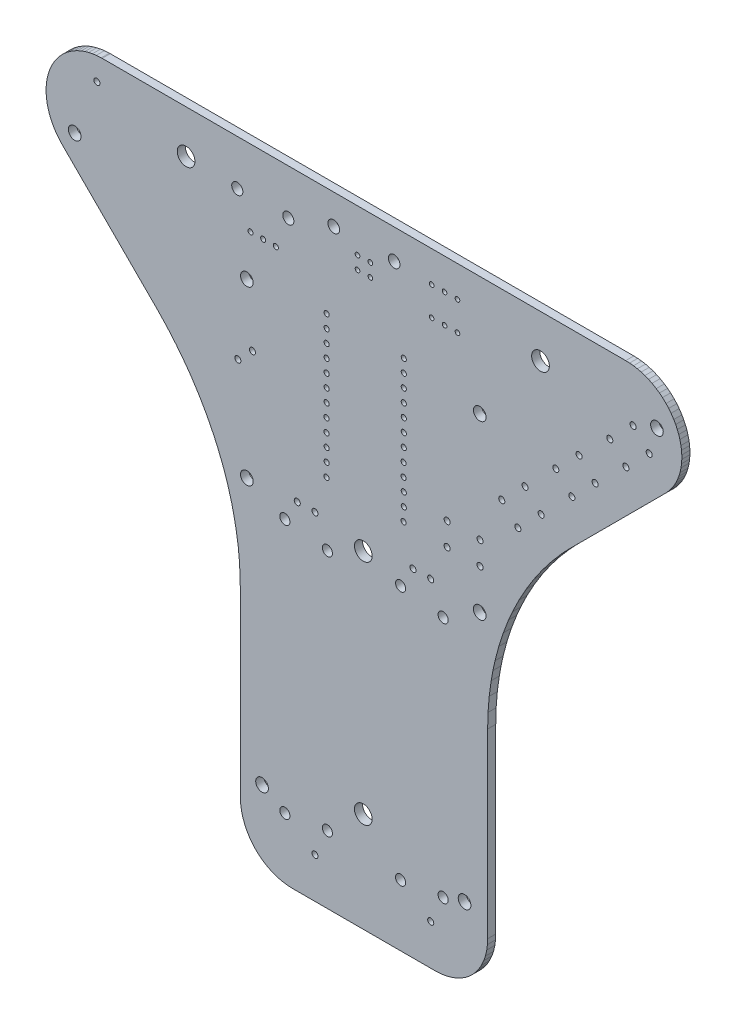
SolidWorks part; units mm, degrees
ref_plane "Front Plane" through (0, 0, 0) normal (0, 0, 1) x (1, 0, 0)
ref_plane "Top Plane" through (0, 0, 0) normal (0, 1, 0) x (1, 0, 0)
ref_plane "Right Plane" through (0, 0, 0) normal (1, 0, 0) x (0, 0, -1)
sketch "pcb" plane through (0, 0, 0) normal (0, 0, 1) x (1, 0, 0)
  line L0 (-7.272, 1.6129) -> (-7.272, 1.0363)
  line L1 (-7.272, 1.0363) -> (-6.03, -0.2057)
  line L2 (-6.03, -0.2057) -> (-6.03, -2.479)
  line L3 (-6.03, -2.479) -> (-5.0089, -3.5001)
  line L4 (-5.0089, -3.5001) -> (0.6274, -3.5001)
  line L5 (0.6274, -3.5001) -> (2.8702, -1.2573)
  line L6 (2.8702, -1.2573) -> (2.8702, -0.5893)
  line L7 (2.8702, -0.5893) -> (3.3299, -0.1295)
  line L8 (3.3299, -0.1295) -> (3.9522, -0.1295)
  line L9 (3.9522, -0.1295) -> (4.8311, 0.7493)
  line L10 (4.8311, 0.7493) -> (4.8311, 1.6434)
  line L11 (4.8311, 1.6434) -> (3.4646, 3.0099)
  line L12 (3.4646, 3.0099) -> (3.015, 3.0099)
  line L13 (16.5621, -6.0599) -> (23.0619, -6.0599)
  line L14 (-7.272, -3.4671) -> (-4.4018, -6.3373)
  line L15 (-4.4018, -6.3373) -> (5.527, -6.3373)
  line L16 (5.527, -6.3373) -> (5.8471, -6.0173)
  line L17 (6.6218, -5.0673) -> (6.6218, -6.3627)
  line L18 (6.6218, -6.3627) -> (6.2154, -6.7691)
  line L19 (6.2154, -6.7691) -> (-6.35, -6.858)
  line L20 (-6.35, -6.858) -> (-7.239, -5.969)
  line L21 (-0.6045, 20.3327) -> (-0.6045, 23.2664)
  line L22 (-0.6045, 23.2664) -> (0.602, 24.4729)
  line L23 (0.602, 24.4729) -> (5.682, 24.4729)
  line L24 (5.682, 24.4729) -> (8.222, 21.9329)
  line L25 (-7.272, 16.8529) -> (-6.1493, 17.9756)
  line L26 (-6.1493, 17.9756) -> (-5.2019, 17.9756)
  line L27 (-5.113, 21.9329) -> (-2.3444, 19.1643)
  line L28 (-2.3444, 19.1643) -> (0.3988, 19.1643)
  line L29 (0.3988, 19.1643) -> (1.3894, 20.1549)
  line L30 (1.3894, 20.1549) -> (1.3894, 22.6695)
  line L31 (1.3894, 22.6695) -> (2.761, 24.0411)
  line L32 (2.761, 24.0411) -> (5.6058, 24.0411)
  line L33 (5.6058, 24.0411) -> (6.698, 22.9489)
  line L34 (6.698, 22.9489) -> (6.698, 21.4249)
  line L35 (6.698, 21.4249) -> (7.079, 21.0439)
  line L36 (7.079, 21.0439) -> (7.079, 20.2819)
  line L37 (7.079, 20.2819) -> (6.698, 19.9009)
  line L38 (6.698, 19.9009) -> (6.698, 18.1229)
  line L39 (6.698, 18.1229) -> (7.968, 16.8529)
  line L40 (1.618, 7.9629) -> (1.872, 7.9629)
  line L41 (1.872, 7.9629) -> (2.38, 7.4549)
  line L42 (2.38, 7.4549) -> (5.047, 7.4549)
  line L43 (5.047, 7.4549) -> (5.555, 6.9469)
  line L44 (5.555, 6.9469) -> (6.19, 6.9469)
  line L45 (6.19, 6.9469) -> (6.698, 6.4389)
  line L46 (6.698, 6.4389) -> (6.698, 2.8829)
  line L47 (6.698, 2.8829) -> (7.968, 1.6129)
  line L48 (1.4148, 6.9723) -> (1.4402, 6.9469)
  line L49 (1.4402, 6.9469) -> (4.92, 6.9469)
  line L50 (4.92, 6.9469) -> (5.3264, 6.5405)
  line L51 (5.3264, 6.5405) -> (5.8598, 6.5405)
  line L52 (5.8598, 6.5405) -> (6.2662, 6.1341)
  line L53 (6.2662, 6.1341) -> (6.2662, 0.6985)
  line L54 (6.2662, 0.6985) -> (7.8918, -0.9271)
  line L55 (7.8918, -0.9271) -> (7.968, -0.9271)
  line L56 (0.348, 6.9469) -> (1.11, 6.1849)
  line L57 (1.11, 6.1849) -> (1.5672, 6.1849)
  line L58 (1.5672, 6.1849) -> (1.9482, 6.5659)
  line L59 (1.9482, 6.5659) -> (4.539, 6.5659)
  line L60 (4.539, 6.5659) -> (4.9708, 6.1341)
  line L61 (4.9708, 6.1341) -> (5.6312, 6.1341)
  line L62 (5.6312, 6.1341) -> (5.8598, 5.9055)
  line L63 (5.8598, 5.9055) -> (5.8598, 4.5339)
  line L64 (5.8598, 4.5339) -> (5.8852, 4.5085)
  line L65 (5.8852, 4.5085) -> (5.8852, -1.3843)
  line L66 (5.8852, -1.3843) -> (7.968, -3.4671)
  line L67 (-0.7722, 0.8865) -> (0.0762, 1.7348)
  line L68 (0.0762, 1.7348) -> (0.0762, 4.3866)
  line L69 (0.0762, 4.3866) -> (-2.827, 7.2898)
  line L70 (-2.827, 7.2898) -> (-2.827, 9.6596)
  line L71 (-2.827, 9.6596) -> (-3.9522, 10.7848)
  line L72 (-3.9522, 10.7848) -> (-4.7523, 10.7848)
  line L73 (-4.7523, 10.7848) -> (-4.8184, 10.8509)
  line L74 (-4.8184, 10.8509) -> (-4.8184, 12.4409)
  line L75 (-4.8184, 12.4409) -> (-4.6203, 12.639)
  line L76 (-4.6203, 12.639) -> (-4.0132, 12.639)
  line L77 (-4.0132, 12.639) -> (-2.8753, 13.777)
  line L78 (-2.8753, 13.777) -> (-2.8753, 17.4396)
  line L79 (-2.8753, 17.4396) -> (-2.827, 17.4879)
  line L80 (-2.827, 17.4879) -> (-7.272, 21.9329)
  line L81 (1.1468, 0.7455) -> (0.8649, 0.7455)
  line L82 (0.8649, 0.7455) -> (-0.9677, -1.0871)
  line L83 (-0.9677, -1.0871) -> (-3.998, -1.0871)
  line L84 (-3.998, -1.0871) -> (-4.4272, -0.6579)
  line L85 (-4.4272, -0.6579) -> (-4.4272, 0.795)
  line L86 (-4.4272, 0.795) -> (-4.986, 1.3538)
  line L87 (-4.986, 1.3538) -> (-4.986, 2.479)
  line L88 (-4.986, 2.479) -> (-4.8463, 2.6187)
  line L89 (5.9436, 7.8029) -> (5.2121, 7.8029)
  line L90 (5.2121, 7.8029) -> (5.1232, 7.8918)
  line L91 (5.1232, 7.8918) -> (2.8321, 7.8918)
  line L92 (2.8321, 7.8918) -> (2.1895, 8.5344)
  line L93 (2.1895, 8.5344) -> (1.717, 9.0068)
  line L94 (1.717, 9.0068) -> (1.5392, 9.0068)
  line L95 (1.5392, 9.0068) -> (0.541, 8.0086)
  line L96 (0.541, 8.0086) -> (0.1626, 8.0086)
  line L97 (0.1626, 8.0086) -> (-0.5715, 7.2746)
  line L98 (-0.5715, 7.2746) -> (-0.5715, 6.8605)
  line L99 (-0.5715, 6.8605) -> (1.1557, 5.1333)
  line L100 (1.1557, 5.1333) -> (1.1557, 0.7544)
  line L101 (6.1112, 12.7813) -> (6.1112, 12.4562)
  line L102 (6.1112, 12.4562) -> (2.1895, 8.5344)
  line L103 (-7.272, 11.7729) -> (-7.272, 12.4866)
  line L104 (-7.272, 12.4866) -> (-5.9893, 13.7693)
  line L105 (-5.9893, 13.7693) -> (-5.9893, 16.5684)
  line L106 (-5.9893, 16.5684) -> (-5.4864, 17.0713)
  line L107 (-5.4864, 17.0713) -> (-4.2951, 17.0713)
  line L108 (-4.2951, 17.0713) -> (-3.716, 16.4922)
  line L109 (-3.716, 16.4922) -> (-3.7186, 16.4897)
  line L110 (-3.7186, 16.4897) -> (-3.7186, 14.1199)
  line L111 (-3.7186, 14.1199) -> (-4.3891, 13.4493)
  line L112 (-4.3891, 13.4493) -> (-5.1003, 13.4493)
  line L113 (-5.1003, 13.4493) -> (-5.6083, 12.9413)
  line L114 (-5.6083, 12.9413) -> (-5.6083, 10.3505)
  line L115 (-5.6083, 10.3505) -> (-5.2654, 10.0076)
  line L116 (-5.2654, 10.0076) -> (-4.3078, 10.0076)
  line L117 (-4.3078, 10.0076) -> (-3.716, 9.4158)
  line L118 (-3.716, 9.4158) -> (-3.716, 6.9469)
  line L119 (-3.716, 6.9469) -> (-0.922, 4.1529)
  line L120 (-0.922, 4.1529) -> (-0.922, 3.3528)
  line L121 (-0.922, 3.3528) -> (-2.093, 2.1819)
  line L122 (-2.5527, 3.1293) -> (-4.3434, 3.1293)
  line L123 (-4.3434, 3.1293) -> (-5.494, 4.2799)
  line L124 (-5.494, 4.2799) -> (-5.494, 5.6769)
  line L125 (-5.494, 5.6769) -> (-6.002, 6.1849)
  line L126 (-6.002, 6.1849) -> (-6.002, 7.9629)
  line L127 (-6.002, 7.9629) -> (-7.272, 9.2329)
  line L128 (-7.272, 6.6929) -> (-6.002, 5.4229)
  line L129 (-6.002, 5.4229) -> (-6.002, 3.4417)
  line L130 (-6.002, 3.4417) -> (-5.621, 3.0607)
  line L131 (-5.621, 3.0607) -> (-5.621, 0.6706)
  line L132 (-5.621, 0.6706) -> (-5.1257, 0.1753)
  line L133 (-5.1257, 0.1753) -> (-5.1257, -2.0117)
  line L134 (-5.1257, -2.0117) -> (-4.6507, -2.4867)
  line L135 (-4.6507, -2.4867) -> (0.3861, -2.4867)
  line L136 (0.3861, -2.4867) -> (2.0422, -0.8306)
  line L137 (2.0422, -0.8306) -> (2.0422, -0.1727)
  line L138 (2.0422, -0.1727) -> (3.0556, 0.8407)
  line L139 (3.0556, 0.8407) -> (3.0556, 1.4834)
  line L140 (5.0876, 4.3993) -> (4.5441, 3.8557)
  line L141 (4.5441, 3.8557) -> (2.8702, 3.8557)
  line L142 (2.8702, 3.8557) -> (2.3038, 3.2893)
  line L143 (2.3038, 3.2893) -> (2.3038, 2.4511)
  line L144 (2.3038, 2.4511) -> (2.5883, 2.1666)
  line L145 (2.5883, 2.1666) -> (3.5687, 2.1666)
  line L146 (3.5687, 2.1666) -> (4.318, 1.4173)
  line L147 (4.318, 1.4173) -> (4.318, 0.8839)
  line L148 (4.318, 0.8839) -> (3.7084, 0.2743)
  line L149 (3.7084, 0.2743) -> (3.1648, 0.2743)
  line L150 (3.1648, 0.2743) -> (2.4714, -0.4191)
  line L151 (2.4714, -0.4191) -> (2.4562, -0.4191)
  line L152 (2.4562, -0.4191) -> (2.4562, -1.0312)
  line L153 (2.4562, -1.0312) -> (0.5131, -2.9743)
  line L154 (0.5131, -2.9743) -> (-4.7828, -2.9743)
  line L155 (-4.7828, -2.9743) -> (-5.5474, -2.2098)
  line L156 (-5.5474, -2.2098) -> (-5.5474, -0.0102)
  line L157 (-5.5474, -0.0102) -> (-6.0452, 0.4877)
  line L158 (-6.0452, 0.4877) -> (-6.0452, 1.0617)
  line L159 (-6.0452, 1.0617) -> (-6.002, 1.1049)
  line L160 (-6.002, 1.1049) -> (-6.002, 2.8829)
  line L161 (-6.002, 2.8829) -> (-7.272, 4.1529)
  line L162 (-5.3111, 6.6929) -> (-5.3111, 8.161)
  line L163 (-5.3111, 8.161) -> (-6.002, 8.8519)
  line L164 (-6.002, 8.8519) -> (-6.002, 13.1547)
  line L165 (-6.002, 13.1547) -> (-5.5448, 13.6119)
  line L166 (-5.5448, 13.6119) -> (-5.5448, 15.6413)
  line L167 (-5.5448, 15.6413) -> (-4.8768, 16.3093)
  line L168 (-4.8768, 16.3093) -> (-4.8438, 16.3093)
  line L169 (-5.0241, 10.3962) -> (-5.0343, 10.3962)
  line L170 (2.888, 16.6243) -> (2.8118, 16.5481)
  line L171 (2.8118, 16.5481) -> (2.8118, 21.4757)
  line L172 (2.8118, 21.4757) -> (3.523, 22.1869)
  line L173 (2.8118, 16.5481) -> (2.8118, 15.428)
  line L174 (2.8118, 15.428) -> (1.9964, 14.6126)
  line L175 (1.9964, 14.6126) -> (1.9964, 13.3731)
  line L176 (1.9964, 13.3731) -> (0.5791, 11.9558)
  line L177 (0.5791, 11.9558) -> (0.4699, 11.9558)
  line L178 (0.4699, 11.9558) -> (-1.077, 13.5026)
  line L179 (-1.077, 13.5026) -> (-2.6035, 13.5026)
  line L180 (-2.6035, 13.5026) -> (-3.7008, 12.4054)
  line L181 (-3.7008, 12.4054) -> (-3.7008, 11.8466)
  line L182 (-1.1532, 12.3698) -> (-1.8618, 13.0785)
  line L183 (-1.8618, 13.0785) -> (-2.4714, 13.0785)
  line L184 (-2.4714, 13.0785) -> (-2.8219, 12.7279)
  line L185 (-2.8219, 12.7279) -> (-2.8219, 12.0599)
  line L186 (-2.8219, 12.0599) -> (-2.3673, 11.6053)
  line L187 (-2.3673, 11.6053) -> (-2.3597, 11.6129)
  line L188 (-2.3597, 11.6129) -> (-1.9609, 11.6129)
  line L189 (-1.9609, 11.6129) -> (-0.9677, 10.6197)
  line L190 (-0.9677, 10.6197) -> (2.5832, 10.6197)
  line L191 (2.5832, 10.6197) -> (4.3586, 12.3952)
  line L192 (4.3586, 12.3952) -> (4.3586, 13.9319)
  line L193 (4.3586, 13.9319) -> (6.063, 15.6362)
  line L194 (6.063, 15.6362) -> (6.063, 22.5679)
  line L195 (6.063, 22.5679) -> (5.682, 22.9489)
  line L196 (5.682, 22.9489) -> (4.5644, 22.9489)
  line L197 (-2.1158, 12.3368) -> (-0.8255, 11.0465)
  line L198 (-0.8255, 11.0465) -> (2.3724, 11.0465)
  line L199 (2.3724, 11.0465) -> (2.3724, 11.0617)
  line L200 (2.3724, 11.0617) -> (3.9091, 12.5984)
  line L201 (3.9091, 12.5984) -> (3.9091, 14.163)
  line L202 (3.9091, 14.163) -> (5.555, 15.809)
  line L203 (5.555, 15.809) -> (5.555, 22.0091)
  line L204 (5.555, 22.0091) -> (5.4026, 22.1615)
  line L205 (-4.478, 9.2329) -> (-4.478, 5.174)
  line L206 (-4.478, 5.174) -> (-4.826, 4.826)
  line L207 (-1.7882, 1.204) -> (-0.5131, 2.479)
  line L208 (-0.5131, 2.479) -> (-0.5131, 4.3231)
  line L209 (-0.5131, 4.3231) -> (-3.2842, 7.0942)
  line L210 (-3.2842, 7.0942) -> (-3.2842, 9.5402)
  line L211 (-3.2842, 9.5402) -> (-4.1402, 10.3962)
  line L212 (-4.1402, 10.3962) -> (-5.0241, 10.3962)
  line L213 (-5.0241, 10.3962) -> (-5.2222, 10.5943)
  line L214 (-5.2222, 10.5943) -> (-5.2222, 12.634)
  line L215 (-5.2222, 12.634) -> (-4.826, 13.0302)
  line L216 (-4.826, 13.0302) -> (-4.826, 13.0404)
  line L217 (-4.826, 13.0404) -> (-4.1808, 13.0404)
  line L218 (-4.1808, 13.0404) -> (-3.269, 13.9522)
  line L219 (-3.269, 13.9522) -> (-3.269, 17.3533)
  line L220 (-3.269, 17.3533) -> (-5.3086, 19.3929)
  line L221 (-5.3086, 19.3929) -> (-7.272, 19.3929)
  line L222 (13.5019, 37.3438) -> (13.4678, 37.3438)
  line L223 (13.4678, 37.3438) -> (3.81, 27.686)
  line L224 (3.81, 27.686) -> (-8.128, 27.686)
  line L225 (-8.128, 27.686) -> (-10.414, 25.4)
  line L226 (-10.414, 25.4) -> (-10.414, 9.906)
  line L227 (-10.414, 9.906) -> (-7.239, 6.731)
  line L228 (16.5621, -6.0599) -> (15.7119, -6.0599)
  line L229 (15.7119, -6.0599) -> (11.684, -2.032)
  line L230 (11.684, -2.032) -> (11.684, 13.208)
  line L231 (11.684, 13.208) -> (8.001, 16.891)
  line L232 (13.5019, 37.3438) -> (13.5019, 36.7447)
  line L233 (13.5019, 36.7447) -> (18.6025, 31.6441)
  line L234 (20.066, 2.794) -> (20.066, 11.43)
  line L235 (20.066, 11.43) -> (11.43, 20.066)
  line L236 (-24.3003, -33.1692) -> (-24.4348, -29.3328)
  line L237 (-24.4348, -29.3328) -> (-24.7142, -26.4668)
  line L238 (-24.7142, -26.4668) -> (-25.1714, -23.5966)
  line L239 (-25.1714, -23.5966) -> (-25.5524, -21.717)
  line L240 (-25.5524, -21.717) -> (-25.9842, -19.812)
  line L241 (-25.9842, -19.812) -> (-26.7716, -17.018)
  line L242 (-26.7716, -17.018) -> (-27.7114, -14.2748)
  line L243 (-27.7114, -14.2748) -> (-28.8036, -11.557)
  line L244 (-28.8036, -11.557) -> (-29.6164, -9.779)
  line L245 (-29.6164, -9.779) -> (-30.9372, -7.1628)
  line L246 (-30.9372, -7.1628) -> (-32.4104, -4.5974)
  line L247 (-32.4104, -4.5974) -> (-33.9852, -2.1336)
  line L248 (-33.9852, -2.1336) -> (-35.1282, -0.5334)
  line L249 (-35.1282, -0.5334) -> (-36.9316, 1.8034)
  line L250 (-36.9316, 1.8034) -> (-38.862, 4.064)
  line L251 (-38.862, 4.064) -> (-40.894, 6.1976)
  line L252 (-24.3003, -33.1692) -> (-24.3003, -69.0429)
  line L253 (40.4734, 5.5013) -> (59.6982, 24.738)
  line L254 (40.4734, 5.5013) -> (39.1247, 4.0579)
  line L255 (39.1247, 4.0579) -> (37.198, 1.8116)
  line L256 (37.198, 1.8116) -> (35.3917, -0.5263)
  line L257 (35.3917, -0.5263) -> (33.7108, -2.9495)
  line L258 (33.7108, -2.9495) -> (32.1599, -5.4511)
  line L259 (32.1599, -5.4511) -> (30.7434, -8.0242)
  line L260 (30.7434, -8.0242) -> (29.4652, -10.6617)
  line L261 (29.4652, -10.6617) -> (28.6917, -12.4521)
  line L262 (28.6917, -12.4521) -> (27.6518, -15.1804)
  line L263 (27.6518, -15.1804) -> (26.7588, -17.9532)
  line L264 (26.7588, -17.9532) -> (26.0152, -20.7626)
  line L265 (26.0152, -20.7626) -> (25.6035, -22.6521)
  line L266 (25.6035, -22.6521) -> (25.2596, -24.5522)
  line L267 (25.2596, -24.5522) -> (24.8719, -27.4168)
  line L268 (24.8719, -27.4168) -> (24.6388, -30.2918)
  line L269 (24.6388, -30.2918) -> (24.561, -33.1692)
  line L270 (24.561, -69.0429) -> (24.561, -33.1692)
  line L271 (14.3787, -79.7108) -> (15.5547, -79.6255)
  line L272 (15.5547, -79.6255) -> (16.5154, -79.4573)
  line L273 (16.5154, -79.4573) -> (17.4506, -79.2021)
  line L274 (17.4506, -79.2021) -> (18.3534, -78.8618)
  line L275 (18.3534, -78.8618) -> (19.3842, -78.3449)
  line L276 (19.3842, -78.3449) -> (20.1917, -77.8275)
  line L277 (20.1917, -77.8275) -> (20.946, -77.2355)
  line L278 (20.946, -77.2355) -> (21.6411, -76.5734)
  line L279 (21.6411, -76.5734) -> (22.272, -75.8462)
  line L280 (22.272, -75.8462) -> (22.8337, -75.0595)
  line L281 (22.8337, -75.0595) -> (23.3221, -74.2191)
  line L282 (23.3221, -74.2191) -> (23.806, -73.1491)
  line L283 (23.806, -73.1491) -> (24.1207, -72.2139)
  line L284 (24.1207, -72.2139) -> (24.3884, -71.05)
  line L285 (24.3884, -71.05) -> (24.5178, -70.0542)
  line L286 (24.5178, -70.0542) -> (24.561, -69.0429)
  line L287 (-13.9204, -79.7126) -> (14.1811, -79.7126)
  line L288 (-24.2986, -69.246) -> (-24.2381, -70.2549)
  line L289 (-24.2381, -70.2549) -> (-24.0519, -71.4423)
  line L290 (-24.0519, -71.4423) -> (-23.8036, -72.4037)
  line L291 (-23.8036, -72.4037) -> (-23.4726, -73.3316)
  line L292 (-23.4726, -73.3316) -> (-23.0614, -74.2191)
  line L293 (-23.0614, -74.2191) -> (-22.573, -75.0595)
  line L294 (-22.573, -75.0595) -> (-22.0113, -75.8462)
  line L295 (-22.0113, -75.8462) -> (-21.2464, -76.7112)
  line L296 (-21.2464, -76.7112) -> (-20.5389, -77.3596)
  line L297 (-20.5389, -77.3596) -> (-19.7736, -77.9371)
  line L298 (-19.7736, -77.9371) -> (-18.7869, -78.53)
  line L299 (-18.7869, -78.53) -> (-17.9151, -78.9365)
  line L300 (-17.9151, -78.9365) -> (-16.8193, -79.3145)
  line L301 (-16.8193, -79.3145) -> (-15.873, -79.5351)
  line L302 (-15.873, -79.5351) -> (-14.9043, -79.6681)
  line L303 (-14.9043, -79.6681) -> (-13.9204, -79.7126)
  line L304 (-59.4375, 24.738) -> (-40.9057, 6.2062)
  line L305 (-51.7634, 43.4849) -> (-52.727, 43.4265)
  line L306 (-52.727, 43.4265) -> (-53.4919, 43.32)
  line L307 (-53.4919, 43.32) -> (-54.2475, 43.1609)
  line L308 (-54.2475, 43.1609) -> (-54.9901, 42.9499)
  line L309 (-54.9901, 42.9499) -> (-55.716, 42.6882)
  line L310 (-55.716, 42.6882) -> (-56.4219, 42.3768)
  line L311 (-56.4219, 42.3768) -> (-57.1042, 42.0175)
  line L312 (-57.1042, 42.0175) -> (-57.9188, 41.5034)
  line L313 (-57.9188, 41.5034) -> (-58.5362, 41.0428)
  line L314 (-58.5362, 41.0428) -> (-59.1197, 40.5405)
  line L315 (-59.1197, 40.5405) -> (-59.6666, 39.9992)
  line L316 (-59.6666, 39.9992) -> (-60.1741, 39.4214)
  line L317 (-60.1741, 39.4214) -> (-60.6399, 38.8099)
  line L318 (-60.6399, 38.8099) -> (-61.0616, 38.1676)
  line L319 (-61.0616, 38.1676) -> (-61.4372, 37.4978)
  line L320 (-61.4372, 37.4978) -> (-61.8391, 36.6267)
  line L321 (-61.8391, 36.6267) -> (-62.1048, 35.9069)
  line L322 (-62.1048, 35.9069) -> (-62.3647, 34.9843)
  line L323 (-62.3647, 34.9843) -> (-62.5137, 34.2321)
  line L324 (-62.5137, 34.2321) -> (-62.6097, 33.4715)
  line L325 (-62.6097, 33.4715) -> (-62.652, 32.7061)
  line L326 (-62.652, 32.7061) -> (-62.6405, 31.9396)
  line L327 (-62.6405, 31.9396) -> (-62.5752, 31.1758)
  line L328 (-62.5752, 31.1758) -> (-62.4565, 30.4184)
  line L329 (-62.4565, 30.4184) -> (-62.2339, 29.4861)
  line L330 (-62.2339, 29.4861) -> (-61.9974, 28.7564)
  line L331 (-61.9974, 28.7564) -> (-61.7103, 28.0447)
  line L332 (-61.7103, 28.0447) -> (-61.374, 27.3547)
  line L333 (-61.374, 27.3547) -> (-60.8869, 26.5275)
  line L334 (-60.8869, 26.5275) -> (-60.4461, 25.898)
  line L335 (-60.4461, 25.898) -> (-59.9622, 25.3006)
  line L336 (-59.9622, 25.3006) -> (-59.4375, 24.738)
  line L337 (51.831, 43.4866) -> (-51.5703, 43.4866)
  line L338 (59.8331, 24.8752) -> (60.3478, 25.4468)
  line L339 (60.3478, 25.4468) -> (60.9327, 26.209)
  line L340 (60.9327, 26.209) -> (61.3512, 26.8533)
  line L341 (61.3512, 26.8533) -> (61.7233, 27.525)
  line L342 (61.7233, 27.525) -> (62.0475, 28.2207)
  line L343 (62.0475, 28.2207) -> (62.3221, 28.9372)
  line L344 (62.3221, 28.9372) -> (62.5457, 29.671)
  line L345 (62.5457, 29.671) -> (62.7519, 30.6069)
  line L346 (62.7519, 30.6069) -> (62.8573, 31.3663)
  line L347 (62.8573, 31.3663) -> (62.9091, 32.1311)
  line L348 (62.9091, 32.1311) -> (62.9072, 32.8977)
  line L349 (62.9072, 32.8977) -> (62.8514, 33.6622)
  line L350 (62.8514, 33.6622) -> (62.7422, 34.4211)
  line L351 (62.7422, 34.4211) -> (62.5312, 35.356)
  line L352 (62.5312, 35.356) -> (62.3038, 36.0886)
  line L353 (62.3038, 36.0886) -> (62.0256, 36.8037)
  line L354 (62.0256, 36.8037) -> (61.6979, 37.4978)
  line L355 (61.6979, 37.4978) -> (61.3223, 38.1676)
  line L356 (61.3223, 38.1676) -> (60.7882, 38.9657)
  line L357 (60.7882, 38.9657) -> (60.3117, 39.5691)
  line L358 (60.3117, 39.5691) -> (59.7941, 40.138)
  line L359 (59.7941, 40.138) -> (59.093, 40.7967)
  line L360 (59.093, 40.7967) -> (58.4923, 41.2785)
  line L361 (58.4923, 41.2785) -> (57.8591, 41.7175)
  line L362 (57.8591, 41.7175) -> (57.0269, 42.2031)
  line L363 (57.0269, 42.2031) -> (56.3324, 42.5386)
  line L364 (56.3324, 42.5386) -> (55.6161, 42.8253)
  line L365 (55.6161, 42.8253) -> (54.8814, 43.0618)
  line L366 (54.8814, 43.0618) -> (54.1318, 43.247)
  line L367 (54.1318, 43.247) -> (53.3711, 43.3799)
  line L368 (53.3711, 43.3799) -> (52.603, 43.4599)
  line L369 (52.603, 43.4599) -> (51.831, 43.4866)
  line L370 (-3.7544, 7.3091) -> (-3.1382, 6.6929)
  line L371 (-3.1382, 6.6929) -> (-3.1242, 6.6929)
  line L372 (-3.1242, 6.6929) -> (-2.192, 6.6929)
  line L373 (-2.192, 6.6929) -> (-1.303, 6.6929)
  line L374 (-1.303, 6.6929) -> (-0.795, 6.1849)
  line L375 (-0.795, 6.1849) -> (0.6274, 6.1849)
  line L376 (0.6274, 6.1849) -> (1.4148, 6.9723)
  line L377 (-3.4056, 7.6576) -> (-2.8219, 7.0739)
  line L378 (-2.8219, 7.0739) -> (-2.7981, 7.0739)
  line L379 (-2.7981, 7.0739) -> (-2.192, 7.0739)
  line L380 (-2.192, 7.0739) -> (0.221, 7.0739)
  line L381 (0.221, 7.0739) -> (0.348, 6.9469)
  line L382 (-3.048, 8.001) -> (-2.7597, 7.7089)
  line L383 (-2.7597, 7.7089) -> (-2.192, 7.7089)
  line L384 (-2.192, 7.7089) -> (1.364, 7.7089)
  line L385 (1.364, 7.7089) -> (1.618, 7.9629)
  line L386 (-2.667, 8.255) -> (-3.5865, 9.2329)
  line L387 (-3.5865, 9.2329) -> (-4.478, 9.2329)
  line L388 (-3.7008, 11.8466) -> (-3.8379, 11.7094)
  line L389 (-3.8379, 11.7094) -> (-5.1867, 11.7094)
  line L390 (-5.1867, 11.7094) -> (-5.4051, 11.491)
  line L391 (-5.4051, 11.491) -> (-5.4051, 10.254)
  line L392 (-5.4051, 10.254) -> (-5.1943, 10.0432)
  line L393 (-5.1943, 10.0432) -> (-4.2774, 10.0432)
  line L394 (-4.2774, 10.0432) -> (-3.8633, 9.6291)
  line L395 (-3.8633, 9.6291) -> (-3.2499, 9.6291)
  line L396 (-3.2499, 9.6291) -> (-3.2499, 9.5936)
  line L397 (-3.2499, 9.5936) -> (-2.3599, 8.7036)
  line L398 (-2.0112, 9.0521) -> (-2.982, 10.0228)
  line L399 (-2.982, 10.0228) -> (-3.6805, 10.0228)
  line L400 (-3.6805, 10.0228) -> (-4.5161, 10.8585)
  line L401 (-4.5161, 10.8585) -> (-4.538, 10.8585)
  line L402 (-3.1618, 13.1745) -> (-3.4747, 13.1745)
  line L403 (-3.4747, 13.1745) -> (-2.8382, 12.5379)
  line L404 (-2.8382, 12.5379) -> (-2.8382, 10.8585)
  line L405 (-2.8382, 10.8585) -> (-2.8382, 10.5761)
  line L406 (-2.8382, 10.5761) -> (-1.651, 9.398)
  line L407 (-1.3142, 9.7493) -> (-1.8186, 10.254)
  line L408 (-1.8186, 10.254) -> (-1.8186, 12.0396)
  line L409 (-1.8186, 12.0396) -> (-2.1158, 12.3368)
  line L410 (-0.889, 10.033) -> (-1.4046, 10.5372)
  line L411 (-1.4046, 10.5372) -> (-1.4046, 12.1183)
  line L412 (-1.4046, 12.1183) -> (-1.1532, 12.3698)
  line L413 (-0.635, 10.414) -> (-1.0008, 10.8303)
  line L414 (-1.0008, 10.8303) -> (-1.0185, 10.8303)
  line L415 (-1.0185, 10.8303) -> (-1.0185, 11.5621)
  line L416 (-1.0185, 11.5621) -> (-0.6248, 11.9558)
  line L417 (-0.6248, 11.9558) -> (0.4699, 11.9558)
  line L418 (-0.6147, 11.1415) -> (-0.2682, 10.7953)
  line L419 (-0.2682, 10.7953) -> (-0.6223, 11.1491)
  line L420 (-0.6223, 11.1491) -> (-0.6223, 11.3614)
  line L421 (-0.6223, 11.3614) -> (-0.475, 11.5087)
  line L422 (-0.475, 11.5087) -> (-0.2972, 11.5087)
  line L423 (-0.2972, 11.5087) -> (0.0025, 11.209)
  line L424 (0.0025, 11.209) -> (0.696, 11.209)
  line L425 (0.696, 11.209) -> (1.2776, 11.7907)
  line L426 (1.2776, 11.7907) -> (1.2776, 12.5501)
  line L427 (1.2776, 12.5501) -> (1.176, 12.6517)
  line L428 (1.176, 12.6517) -> (0.5537, 12.6517)
  line L429 (0.5537, 12.6517) -> (0.1727, 13.0327)
  line L430 (0.1727, 13.0327) -> (0.1727, 13.0531)
  line L431 (0.1727, 13.0531) -> (-1.5138, 13.0531)
  line L432 (-1.5138, 13.0531) -> (-1.6967, 13.2359)
  line L433 (-1.6967, 13.2359) -> (-1.6967, 13.9192)
  line L434 (-1.6967, 13.9192) -> (-1.4529, 14.163)
  line L435 (-1.4529, 14.163) -> (-1.4529, 14.7574)
  line L436 (-1.4529, 14.7574) -> (-1.8821, 15.1867)
  line L437 (-1.8821, 15.1867) -> (-2.3495, 15.1867)
  line L438 (-2.3495, 15.1867) -> (-2.5959, 14.9403)
  line L439 (-2.5959, 14.9403) -> (-4.3688, 14.9403)
  line L440 (-4.3688, 14.9403) -> (-4.6304, 15.2019)
  line L441 (-4.6304, 15.2019) -> (-4.6304, 16.0477)
  line L442 (-4.6304, 16.0477) -> (-4.8438, 16.2611)
  line L443 (-4.8438, 16.2611) -> (-4.8438, 16.3093)
  line L444 (0.889, 10.795) -> (1.6739, 11.5047)
  line L445 (1.6739, 11.5047) -> (1.6739, 12.987)
  line L446 (1.6739, 12.987) -> (1.7374, 13.0505)
  line L447 (1.7374, 13.0505) -> (0.7772, 13.0505)
  line L448 (0.7772, 13.0505) -> (0.5461, 13.2817)
  line L449 (0.5461, 13.2817) -> (0.5461, 13.5179)
  line L450 (0.5461, 13.5179) -> (0.5461, 15.8267)
  line L451 (0.5461, 15.8267) -> (0.1854, 16.1874)
  line L452 (0.1854, 16.1874) -> (-1.7907, 16.1874)
  line L453 (-1.7907, 16.1874) -> (-2.0036, 15.9746)
  line L454 (-2.0036, 15.9746) -> (-3.4747, 15.9746)
  line L455 (1.651, 10.033) -> (2.8435, 11.2801)
  line L456 (2.8435, 11.2801) -> (3.3459, 11.2801)
  line L457 (4.1377, 10.4902) -> (4.1453, 10.4902)
  line L458 (4.1453, 10.4902) -> (2.794, 9.144)
  line L459 (3.0559, 8.7036) -> (4.4386, 10.0863)
  line L460 (4.4386, 10.0863) -> (7.1145, 10.0863)
  line L461 (7.1145, 10.0863) -> (7.968, 9.2329)
  line L462 (3.4044, 8.3548) -> (4.7193, 9.6698)
  line L463 (4.7193, 9.6698) -> (6.3703, 9.6698)
  line L464 (6.3703, 9.6698) -> (6.7259, 9.3142)
  line L465 (6.7259, 9.3142) -> (6.7259, 8.73)
  line L466 (6.7259, 8.73) -> (7.968, 7.4879)
  line L467 (7.968, 7.4879) -> (7.968, 6.6929)
  line L468 (3.7531, 8.0063) -> (4.9873, 9.2405)
  line L469 (4.9873, 9.2405) -> (6.0655, 9.2405)
  line L470 (6.0655, 9.2405) -> (6.2357, 9.0703)
  line L471 (6.2357, 9.0703) -> (6.2357, 8.6614)
  line L472 (6.2357, 8.6614) -> (6.7285, 8.1686)
  line L473 (6.7285, 8.1686) -> (6.7285, 5.3924)
  line L474 (6.7285, 5.3924) -> (7.968, 4.1529)
  line L475 (4.4503, 7.3091) -> (4.9261, 7.7851)
  line L476 (4.9261, 7.7851) -> (5.9258, 7.7851)
  line L477 (5.9258, 7.7851) -> (5.9436, 7.8029)
  line L478 (4.4503, 6.0767) -> (5.1039, 5.4229)
  line L479 (5.1039, 5.4229) -> (5.428, 5.4229)
  line L480 (3.81, 5.334) -> (4.7333, 4.3993)
  line L481 (4.7333, 4.3993) -> (5.0876, 4.3993)
  line L482 (7.968, -6.0071) -> (7.968, -5.3213)
  line L483 (7.968, -5.3213) -> (6.7234, -4.0767)
  line L484 (6.7234, -4.0767) -> (6.7234, 2.4232)
  line L485 (6.7234, 2.4232) -> (5.6972, 3.4493)
  line L486 (5.6972, 3.4493) -> (4.986, 3.4493)
  line L487 (4.986, 3.4493) -> (3.4044, 5.0307)
  line L488 (3.048, 4.699) -> (4.7155, 3.0226)
  line L489 (4.7155, 3.0226) -> (5.5423, 3.0226)
  line L490 (5.5423, 3.0226) -> (6.2916, 2.2733)
  line L491 (6.2916, 2.2733) -> (6.2916, -4.7879)
  line L492 (6.2916, -4.7879) -> (6.5735, -5.0698)
  line L493 (6.5735, -5.0698) -> (6.6167, -5.0698)
  line L494 (5.8471, -6.0173) -> (5.8471, -4.6228)
  line L495 (5.8471, -4.6228) -> (5.8344, -4.6101)
  line L496 (5.8344, -4.6101) -> (5.8344, 2.0295)
  line L497 (5.8344, 2.0295) -> (5.2629, 2.601)
  line L498 (5.2629, 2.601) -> (4.4399, 2.601)
  line L499 (4.4399, 2.601) -> (2.7071, 4.3335)
  line L500 (2.3586, 3.985) -> (3.015, 3.3287)
  line L501 (3.015, 3.3287) -> (3.015, 3.0099)
  line L502 (3.015, 3.0099) -> (3.015, 3.3188)
  line L503 (3.015, 3.3188) -> (3.015, 3.0099)
  line L504 (1.778, 3.175) -> (2.8237, 2.1293)
  line L505 (2.8237, 2.1293) -> (2.8237, 1.7191)
  line L506 (1.27, 2.921) -> (1.985, 2.2669)
  line L507 (1.985, 2.2669) -> (1.985, 0.8026)
  line L508 (1.016, 2.54) -> (1.364, 2.1907)
  line L509 (1.364, 2.1907) -> (1.364, 1.7907)
  line L510 (-2.286, 4.699) -> (-2.8334, 4.2088)
  line L511 (-2.8334, 4.2088) -> (-3.1064, 4.2088)
  line L512 (-3.1064, 4.2088) -> (-3.683, 3.6322)
  line L513 (-3.683, 3.6322) -> (-3.683, 2.6899)
  line L514 (-3.683, 2.6899) -> (-3.2207, 2.2276)
  line L515 (-3.2207, 2.2276) -> (-3.2207, 1.2319)
  line L516 (-3.2207, 1.2319) -> (-2.8524, 0.8636)
  line L517 (-2.8524, 0.8636) -> (-2.8524, 0.6248)
  line L518 (-2.8524, 0.6248) -> (-2.1895, -0.0381)
  line L519 (-2.1895, -0.0381) -> (-1.4935, -0.0381)
  line L520 (-1.4935, -0.0381) -> (-0.7071, -0.8247)
  line L521 (-0.7071, -0.8247) -> (-0.7071, -2.4511)
  line L522 (-0.7071, -2.4511) -> (-0.16, -2.9982)
  line L523 (-0.16, -2.9982) -> (-0.16, -5.0531)
  line L524 (-0.16, -5.0531) -> (-1.3752, -6.2682)
  line L525 (-1.3752, -6.2682) -> (-1.5022, -6.2682)
  line L526 (-2.4072, -2.4511) -> (-2.4072, -1.3701)
  line L527 (-2.4072, -1.3701) -> (-3.2791, -0.4978)
  line L528 (-3.2791, -0.4978) -> (-3.2791, 0.6477)
  line L529 (-3.2791, 0.6477) -> (-3.9065, 1.2751)
  line L530 (-3.9065, 1.2751) -> (-3.9126, 1.2751)
  line L531 (-3.9126, 1.2751) -> (-4.0843, 1.4468)
  line L532 (-4.0843, 1.4468) -> (-4.0843, 2.921)
  line L533 (-4.0843, 2.921) -> (-4.3459, 3.1826)
  line L534 (-4.3459, 3.1826) -> (-4.3459, 3.7567)
  line L535 (-4.3459, 3.7567) -> (-3.8811, 4.2215)
  line L536 (-3.8811, 4.2215) -> (-3.6424, 4.2215)
  line L537 (-3.6424, 4.2215) -> (-3.1816, 4.6822)
  line L538 (-3.1816, 4.6822) -> (-2.794, 4.953)
  line L539 (-4.2631, -0.2532) -> (-4.0843, -0.2532)
  line L540 (-4.0843, -0.2532) -> (-4.986, 0.6485)
  line L541 (-4.986, 0.6485) -> (-4.986, 2.479)
  line L542 (-4.986, 2.479) -> (-4.8463, 2.6187)
  line L543 (-4.8463, 2.6187) -> (-4.8463, 3.8456)
  line L544 (-4.8463, 3.8456) -> (-4.0665, 4.6253)
  line L545 (-4.0665, 4.6253) -> (-3.8113, 4.6253)
  line L546 (-3.8113, 4.6253) -> (-3.048, 5.334)
  line L547 (-3.429, 5.715) -> (-3.8265, 5.2959)
  line L548 (-3.8265, 5.2959) -> (-3.9789, 5.1435)
  line L549 (-3.9789, 5.1435) -> (-4.1986, 5.1435)
  line L550 (-4.1986, 5.1435) -> (-4.7066, 5.6515)
  line L551 (-4.7066, 5.6515) -> (-4.7066, 6.2103)
  line L552 (-4.7066, 6.2103) -> (-4.478, 6.4389)
  line L553 (-4.478, 6.4389) -> (-4.478, 6.9469)
  line L554 (-4.478, 6.9469) -> (-6.002, 8.4709)
  line L555 (-6.002, 8.4709) -> (-6.002, 17.3355)
  line L556 (-6.002, 17.3355) -> (-6.096, 17.4295)
  line L557 (-6.096, 17.4295) -> (-6.096, 18.7833)
  line L558 (-6.096, 18.7833) -> (-6.002, 18.8773)
  line L559 (-6.002, 18.8773) -> (-6.002, 21.0439)
  line L560 (-6.002, 21.0439) -> (-5.113, 21.9329)
  line L561 (-5.113, 21.9329) -> (-4.3119, 21.1318)
  line L562 (-4.3119, 21.1318) -> (-4.3119, 20.6629)
  line L563 (-4.826, 4.826) -> (-5.5931, 4.0589)
  line L564 (-5.5931, 4.0589) -> (-5.5931, -2.2962)
  line L565 (-5.5931, -2.2962) -> (-5.748, -2.4511)
  line L566 (-5.748, -2.4511) -> (-5.748, -4.571)
  line L567 (-5.748, -4.571) -> (-3.97, -6.349)
  line L568 (4.666, -6.349) -> (3.8786, -5.5616)
  line L569 (3.8786, -5.5616) -> (3.8786, -1.8415)
  line L570 (3.8786, -1.8415) -> (3.5916, -1.5545)
  line L571 (3.5916, -1.5545) -> (2.7254, -1.5545)
  line L572 (2.7254, -1.5545) -> (2.3571, -1.1862)
  line L573 (2.3571, -1.1862) -> (0.3683, -1.1862)
  line L574 (0.3683, -1.1862) -> (0.2083, -1.0262)
  line L575 (0.2083, -1.0262) -> (0.2083, -0.2489)
  line L576 (0.2083, -0.2489) -> (-0.1067, 0.066)
  line L577 (-0.1067, 0.066) -> (-0.1067, 1.2776)
  line L578 (-0.1067, 1.2776) -> (-0.6045, 1.7755)
  line L579 (-0.6045, 1.7755) -> (-0.6045, 2.2479)
  line L580 (-0.6045, 2.2479) -> (-0.6111, 2.2479)
  line L581 (-0.6111, 2.2479) -> (-0.254, 2.54)
  line L582 (-0.7722, 0.8865) -> (-1.0236, 1.1379)
  line L583 (-1.0236, 1.1379) -> (-1.0236, 2.5527)
  line L584 (-1.0236, 2.5527) -> (-1.0036, 2.5527)
  line L585 (-1.0036, 2.5527) -> (-0.762, 2.794)
  line L586 (-1.143, 3.175) -> (-1.4044, 2.8489)
  line L587 (-1.4046, 2.8489) -> (-1.4046, 1.5875)
  line L588 (-1.4046, 1.5875) -> (-1.7882, 1.204)
  line L589 (-1.397, 3.556) -> (-1.8364, 3.114)
  line L590 (-1.8364, 3.114) -> (-1.8364, 2.4384)
  line L591 (-1.8364, 2.4384) -> (-2.093, 2.1819)
  line L592 (-1.651, 3.937) -> (-2.032, 3.556)
  line L593 (-2.032, 3.556) -> (-2.5197, 3.1293)
  line L594 (-2.5197, 3.1293) -> (-2.5527, 3.1293)
  line L595 (-2.032, 4.318) -> (-2.5375, 3.8075)
  line L596 (-2.5375, 3.8075) -> (-2.9108, 3.8075)
  line L597 (-2.9108, 3.8075) -> (-3.2893, 3.429)
  line L598 (-3.2893, 3.429) -> (-3.2893, 2.8524)
  line L599 (-3.2893, 2.8524) -> (-2.8016, 2.3647)
  line L600 (-2.8016, 2.3647) -> (-2.8016, 1.4529)
  line L601 (-2.8016, 1.4529) -> (-2.446, 1.0973)
  line L602 (-2.446, 1.0973) -> (-2.446, 0.8433)
  line L603 (-2.446, 0.8433) -> (-1.9914, 0.3886)
  line L604 (-1.9914, 0.3886) -> (-1.2573, 0.3886)
  line L605 (-1.2573, 0.3886) -> (-0.2057, -0.6629)
  line L606 (-0.2057, -0.6629) -> (-0.2057, -1.2344)
  line L607 (-0.2057, -1.2344) -> (0.1676, -1.6078)
  line L608 (0.1676, -1.6078) -> (2.1326, -1.6078)
  line L609 (2.1326, -1.6078) -> (2.9759, -2.4511)
  line L610 (2.9759, -2.4511) -> (2.9759, -3.19)
  line L611 (2.9759, -3.19) -> (2.1979, -3.968)
  line L612 (-7.272, -0.9271) -> (-6.002, 0.3429)
  line L613 (-6.002, 0.3429) -> (-6.002, 6.002)
  line L614 (-6.002, 6.002) -> (-5.3111, 6.6929)
  line L615 (3.3078, 20.6629) -> (3.1046, 20.4343)
  line L616 (3.1046, 20.4343) -> (2.1717, 20.4343)
  line L617 (2.1717, 20.4343) -> (1.016, 21.59)
  line L618 (1.016, 21.59) -> (1.016, 29.972)
  line L619 (1.016, 29.972) -> (-1.143, 32.131)
  line L620 (-1.143, 32.131) -> (-1.143, 32.512)
  line L621 (3.523, 22.1869) -> (2.54, 23.1699)
  line L622 (2.54, 23.1699) -> (2.54, 30.861)
  line L623 (2.54, 30.861) -> (1.397, 32.004)
  line L624 (1.397, 32.004) -> (1.397, 32.512)
  line L625 (3.3078, 19.21) -> (3.0963, 19.21)
  line L626 (3.0963, 19.21) -> (2.253, 20.0533)
  line L627 (2.253, 20.0533) -> (1.2827, 20.0533)
  line L628 (1.2827, 20.0533) -> (-0.254, 21.59)
  line L629 (-0.254, 21.59) -> (-0.254, 29.21)
  line L630 (-0.254, 29.21) -> (-2.794, 31.75)
  line L631 (-2.794, 31.75) -> (-2.794, 33.401)
  line L632 (-2.794, 33.401) -> (-1.143, 35.052)
  line L633 (13.3159, -71.7141) -> (13.3159, -27.578)
  line L634 (13.3159, -27.578) -> (20.066, -20.828)
  line L635 (20.066, -20.828) -> (20.066, 2.794)
  line L636 (2.8118, 16.5481) -> (3.3078, 17.0442)
  line L637 (3.3078, 17.0442) -> (3.3078, 17.7444)
  line L638 (3.3078, 17.7444) -> (3.3205, 17.7571)
  line L639 (3.3205, 17.7571) -> (2.0173, 17.7571)
  line L640 (2.0173, 17.7571) -> (1.748, 17.4879)
  line L641 (1.748, 17.4879) -> (1.875, 17.6149)
  line L642 (5.1699, 5.3467) -> (5.174, 5.3467)
  line L643 (4.666, 0.0008) -> (4.666, 0.1905)
  line L644 (-3.0571, 8.0063) -> (-2.7597, 7.7089)
  line L645 (-3.0917, 15.9746) -> (-3.4747, 15.9746)
  line L646 (-3.4747, 15.9746) -> (-3.4747, 18.3726)
  line L647 (-3.4747, 18.3726) -> (-2.6248, 19.2227)
  line L648 (-2.6248, 19.2227) -> (-2.6248, 20.6502)
  line L649 (-2.6248, 20.6502) -> (-2.6121, 20.6629)
  line L650 (-2.6121, 20.6629) -> (-3.335, 21.3858)
  line L651 (-3.335, 21.3858) -> (-3.335, 22.0599)
  line L652 (-3.335, 22.0599) -> (-4.0335, 22.7584)
  line L653 (-4.0335, 22.7584) -> (-6.1925, 22.7584)
  line L654 (-6.1925, 22.7584) -> (-6.637, 23.2029)
  line L655 (-6.637, 23.2029) -> (-7.272, 23.2029)
  line L656 (-7.272, 23.2029) -> (-7.684, 23.6146)
  line L657 (-7.684, 23.6146) -> (-7.684, 24.4729)
  line L658 (4.666, -1.701) -> (5.4534, -0.9136)
  line L659 (5.4534, -0.9136) -> (5.4534, 1.3589)
  line L660 (5.4534, 1.3589) -> (5.1112, 1.7008)
  line L661 (5.1112, 1.7008) -> (4.666, 1.7008)
  line L662 (4.666, 1.7008) -> (4.4237, 1.7008)
  line L663 (-4.0208, -1.6502) -> (-3.97, -1.701)
  line L664 (-3.97, -1.701) -> (-4.0843, -1.5867)
  line L665 (-4.0843, -1.5867) -> (-4.0843, -0.2532)
  line L666 (0.4369, 13.6271) -> (-0.7059, 13.6271)
  line L667 (1.1468, 0.7455) -> (2.0422, 0.7455)
  line L668 (2.0422, 0.7455) -> (3.7104, 0.7455)
  line L669 (3.7104, 0.7455) -> (4.666, 1.7008)
  line L670 (1.8943, 13.6271) -> (1.8562, 13.6652)
  line L671 (1.8562, 13.6652) -> (1.2344, 13.6652)
  line L672 (1.2344, 13.6652) -> (0.9652, 13.9344)
  line L673 (0.9652, 13.9344) -> (0.9652, 15.5829)
  line L674 (0.9652, 15.5829) -> (1.8387, 15.5829)
  line L675 (1.8387, 15.5829) -> (1.8943, 15.527)
  line L676 (1.8943, 15.527) -> (3.7816, 15.527)
  line L677 (3.7816, 15.527) -> (4.1808, 15.9263)
  line L678 (1.4978, 19.2913) -> (0.8306, 19.2913)
  line L679 (0.8306, 19.2913) -> (-0.2108, 20.3327)
  line L680 (-0.2108, 20.3327) -> (-0.6045, 20.3327)
  line L681 (0.9652, 15.5829) -> (0.9652, 16.4567)
  line L682 (0.9652, 16.4567) -> (0.8204, 16.6014)
  line L683 (0.8204, 16.6014) -> (0.8204, 19.2811)
  line L684 (0.8204, 19.2811) -> (0.8306, 19.2913)
  line L685 (4.1453, 10.4902) -> (6.6777, 10.4902)
  line L686 (6.6777, 10.4902) -> (7.9604, 11.7729)
  line L687 (7.9604, 11.7729) -> (7.968, 11.7729)
  line L688 (4.5644, 22.9489) -> (4.5644, 21.7805)
  line L689 (4.5644, 21.7805) -> (4.92, 21.4249)
  line L690 (4.92, 21.4249) -> (4.92, 20.7508)
  line L691 (4.92, 20.7508) -> (5.0079, 20.6629)
  line L692 (5.0079, 20.6629) -> (5.0079, 20.9812)
  line L693 (5.4026, 22.1615) -> (6.19, 21.3741)
  line L694 (6.19, 21.3741) -> (6.19, 19.6469)
  line L695 (6.19, 19.6469) -> (5.7531, 19.21)
  line L696 (5.7531, 19.21) -> (5.0079, 19.21)
  line L697 (4.666, -4.4831) -> (4.666, -3.2071)
  line L698 (-4.3246, 19.2227) -> (-4.2248, 19.1226)
  line L699 (-4.2248, 19.1226) -> (-4.2248, 17.8283)
  line L700 (-1.0521, 17.4879) -> (-1.0521, 18.6279)
  line L701 (-1.0521, 18.6279) -> (-0.8021, 18.8778)
  line L702 (-0.8021, 18.8778) -> (-0.8021, 19.2913)
  line L703 (-0.8021, 19.2913) -> (-1.7094, 20.1986)
  line L704 (-1.7094, 20.1986) -> (-1.7094, 21.3233)
  line L705 (-1.7094, 21.3233) -> (-1.938, 21.5519)
  line L706 (-1.938, 21.5519) -> (-2.192, 21.5519)
  line L707 (-2.192, 21.5519) -> (-3.843, 23.2029)
  line L708 (-3.843, 23.2029) -> (-5.748, 23.2029)
  line L709 (-5.748, 23.2029) -> (-6.256, 23.7109)
  line L710 (-6.256, 23.7109) -> (-6.637, 23.7109)
  line L711 (-6.637, 23.7109) -> (-6.86, 23.9339)
  line L712 (-6.86, 23.9339) -> (-6.86, 24.4729)
  line L713 (-3.97, -4.6492) -> (-3.97, -3.2012)
  line L714 (9.8158, -13.1219) -> (9.8158, -7.7838)
  line L715 (9.8158, -7.7838) -> (8.001, -5.969)
  line L716 (-13.0442, -13.1219) -> (-13.0442, -11.7742)
  line L717 (-13.0442, -11.7742) -> (-7.239, -5.969)
  line L718 (35.131, 8.8351) -> (30.5349, 4.239)
  line L719 (41.2029, 14.907) -> (45.799, 19.5031)
  line L720 (51.8709, 25.321) -> (56.467, 29.9171)
  line L721 (30.5349, 4.239) -> (10.493, 4.239)
  line L722 (10.493, 4.239) -> (8.001, 6.731)
  line L723 (41.2029, 14.907) -> (13.637, 14.907)
  line L724 (13.637, 14.907) -> (8.001, 9.271)
  line L725 (51.8709, 25.321) -> (21.511, 25.321)
  line L726 (21.511, 25.321) -> (8.001, 11.811)
  line L727 (-17.272, 28.448) -> (-17.272, 29.21)
  line L728 (-17.272, 29.21) -> (-18.542, 30.48)
  line L729 (-18.542, 30.48) -> (-44.1162, 30.48)
  line L730 (-44.1162, 30.48) -> (-52.6171, 38.9809)
  line L731 (-7.684, 24.4729) -> (-13.2969, 24.4729)
  line L732 (-13.2969, 24.4729) -> (-17.272, 28.448)
  line L733 (13.5021, 31.6441) -> (13.5021, 32.2443)
  line L734 (13.5021, 32.2443) -> (18.6019, 37.3441)
  line L735 (18.6019, 37.3441) -> (18.6019, 38.0401)
  line L736 (18.6019, 38.0401) -> (16.256, 40.386)
  line L737 (16.256, 40.386) -> (-8.128, 40.386)
  line L738 (-8.128, 40.386) -> (-10.668, 37.846)
  line L739 (-10.668, 37.846) -> (-10.668, 33.02)
  line L740 (-10.668, 33.02) -> (-13.208, 30.48)
  line L741 (-13.208, 30.48) -> (-18.542, 30.48)
  line L742 (7.8308, 14.3129) -> (7.6429, 14.3129)
  line L743 (7.6429, 14.3129) -> (6.1112, 12.7813)
  line L744 (6.1112, 12.7813) -> (5.4178, 12.0879)
  line L745 (5.4178, 12.0879) -> (3.2868, 12.0879)
  line L746 (3.2868, 12.0879) -> (3.0099, 12.3647)
  line L747 (3.0099, 12.3647) -> (3.0099, 12.8448)
  line L748 (3.0099, 12.8448) -> (2.8042, 13.0505)
  line L749 (2.8042, 13.0505) -> (1.7374, 13.0505)
  line L750 (-9.544, -71.7141) -> (13.3159, -71.7141)
  line L751 (11.43, 20.066) -> (11.43, 17.8719)
  line L752 (-9.544, -71.7141) -> (-9.652, -71.6062)
  line L753 (-9.652, -71.6062) -> (-9.652, -68.326)
  line L754 (-9.652, -68.326) -> (-19.05, -58.928)
  line L755 (-19.05, -58.928) -> (-19.05, -10.16)
  line L756 (-19.05, -10.16) -> (-29.464, 0.254)
  line L757 (-29.464, 0.254) -> (-29.4561, 25.4)
  line L758 (-29.4561, 25.4) -> (-24.3762, 30.48)
  line L759 (-19.7714, 28.448) -> (-19.7714, 14.1834)
  line L760 (-19.7714, 14.1834) -> (-7.239, 1.651)
  line L761 (-24.7785, 5.3947) -> (-24.6987, 5.3947)
  line L762 (-24.6987, 5.3947) -> (-15.748, -3.556)
  line L763 (-15.748, -3.556) -> (-7.366, -3.556)
  line L764 (-7.366, -3.556) -> (-7.239, -3.429)
  line L765 (8.001, 14.351) -> (13.462, 19.812)
  line L766 (13.462, 19.812) -> (13.462, 31.6039)
  line L767 (13.462, 31.6039) -> (13.5021, 31.6441)
  line L768 (22.7137, -0.8087) -> (22.7137, -6.7076)
  line L769 (22.7137, -6.7076) -> (16.9151, -6.7076)
  line L770 (16.9151, -6.7076) -> (16.9151, -0.8087)
  line L771 (16.9151, -0.8087) -> (22.7137, -0.8087)
  line L772 (-5.842, 46.355) -> (6.096, 46.355)
  line L773 (-5.842, 36.83) -> (-5.842, 31.242)
  line L774 (-5.842, 31.242) -> (6.096, 31.242)
  line L775 (6.096, 31.242) -> (6.096, 36.83)
  line L776 (-5.842, 38.354) -> (-5.842, 47.752)
  line L777 (-5.842, 47.752) -> (6.096, 47.752)
  line L778 (6.096, 47.752) -> (6.096, 38.227)
  line L779 (-8.0721, 25.4729) -> (-6.4719, 25.4729)
  line L780 (-8.3721, 25.223) -> (-8.3721, 23.7228)
  line L781 (-6.1719, 25.223) -> (-6.1719, 23.7228)
  line L782 (-6.4719, 23.4729) -> (-8.0721, 23.4729)
  line L783 (-0.287, 18.2499) -> (0.983, 18.2499)
  line L784 (0.983, 16.7259) -> (-0.287, 16.7259)
  line L785 (-4.43, -2.621) -> (-3.97, -2.621)
  line L786 (-3.97, -2.621) -> (-3.51, -2.621)
  line L787 (-3.97, -2.621) -> (-4.204, -2.3111)
  line L788 (-3.9446, -2.6058) -> (-3.7516, -2.3111)
  line L789 (4.1707, 17.7267) -> (4.1707, 17.7876)
  line L790 (-3.6881, 10.828) -> (-3.6881, 10.889)
  line L791 (-1.557, -2.4816) -> (-1.557, -2.4206)
  line L792 (2.126, -2.4816) -> (2.126, -2.4206)
  line L793 (-0.252, -3.5182) -> (0.9479, -3.5182)
  line L794 (2.8478, -4.8181) -> (2.8478, -5.4181)
  line L795 (0.9479, -6.718) -> (-0.252, -6.718)
  line L796 (-2.1521, -4.8181) -> (-2.1521, -5.4181)
  line L797 (5.3807, 13.5263) -> (5.3807, 12.0261)
  line L798 (5.3807, 12.0261) -> (2.9807, 12.0261)
  line L799 (2.9807, 12.0261) -> (2.9807, 13.5263)
  line L800 (5.3807, 15.5263) -> (5.3807, 16.6263)
  line L801 (5.3807, 16.6263) -> (4.9807, 17.0261)
  line L802 (4.9807, 17.0261) -> (3.3807, 17.0261)
  line L803 (3.3807, 17.0261) -> (2.9807, 16.6263)
  line L804 (2.9807, 16.6263) -> (2.9807, 15.5263)
  line L805 (3.1648, 14.9073) -> (5.1968, 14.9073)
  line L806 (0.1648, 15.9995) -> (1.0236, 15.9995)
  line L807 (1.0236, 13.1547) -> (0.1648, 13.1547)
  line L808 (-0.2162, 14.3086) -> (-0.2162, 14.8455)
  line L809 (4.206, -2.621) -> (4.666, -2.621)
  line L810 (4.666, -2.621) -> (5.126, -2.621)
  line L811 (4.666, -2.621) -> (4.432, -2.3111)
  line L812 (4.6914, -2.6058) -> (4.8844, -2.3111)
  line L813 (4.1961, 11.2497) -> (4.1961, 11.3106)
  line L814 (4.6355, 0.8509) -> (4.6965, 0.8509)
  line L815 (-3.3048, 17.3683) -> (-3.3048, 17.8283)
  line L816 (-3.3048, 17.8283) -> (-3.3048, 18.2883)
  line L817 (-3.3048, 17.8283) -> (-3.6147, 17.5943)
  line L818 (-3.32, 17.8537) -> (-3.6147, 18.0467)
  line L819 (-2.2748, 13.5745) -> (-2.2748, 12.0744)
  line L820 (-2.2748, 12.0744) -> (-4.6746, 12.0744)
  line L821 (-4.6746, 12.0744) -> (-4.6746, 13.5745)
  line L822 (-2.2748, 15.5745) -> (-2.2748, 16.6746)
  line L823 (-2.2748, 16.6746) -> (-2.6746, 17.0744)
  line L824 (-2.6746, 17.0744) -> (-4.2748, 17.0744)
  line L825 (-4.2748, 17.0744) -> (-4.6746, 16.6746)
  line L826 (-4.6746, 16.6746) -> (-4.6746, 15.5745)
  line L827 (-4.4907, 14.9555) -> (-2.4587, 14.9555)
  line L828 (-4.1148, 0.5969) -> (-4.0538, 0.5969)
  line L829 (1.2479, 18.6413) -> (0.8481, 18.6413)
  line L830 (0.8481, 18.6413) -> (-0.5519, 18.6413)
  line L831 (1.2479, 19.9413) -> (0.8481, 19.9413)
  line L832 (0.8481, 19.9413) -> (-0.5519, 19.9413)
  line L833 (0.8481, 18.6413) -> (0.8481, 19.9413)
  line L834 (-5.969, -1.524) -> (-6.604, -2.159)
  line L835 (-6.604, -2.159) -> (-5.969, -2.794)
  line L836 (-5.969, -2.794) -> (-5.969, -4.064)
  line L837 (-5.969, -4.064) -> (-6.604, -4.699)
  line L838 (-6.604, -4.699) -> (-5.969, -5.334)
  line L839 (-5.969, -5.334) -> (-5.969, -6.604)
  line L840 (-5.969, -6.604) -> (-6.604, -7.239)
  line L841 (-6.604, -7.239) -> (-7.874, -7.239)
  line L842 (-7.874, -7.239) -> (-8.509, -6.604)
  line L843 (-8.509, -6.604) -> (-8.509, -5.334)
  line L844 (-8.509, -5.334) -> (-7.874, -4.699)
  line L845 (-7.874, -4.699) -> (-8.509, -4.064)
  line L846 (-8.509, -4.064) -> (-8.509, -2.794)
  line L847 (-8.509, -2.794) -> (-7.874, -2.159)
  line L848 (-7.874, -2.159) -> (-8.509, -1.524)
  line L849 (-8.509, -1.524) -> (-8.509, -0.254)
  line L850 (-8.509, -0.254) -> (-7.874, 0.381)
  line L851 (-7.874, 0.381) -> (-8.509, 1.016)
  line L852 (-8.509, 1.016) -> (-8.509, 2.286)
  line L853 (-8.509, 2.286) -> (-7.874, 2.921)
  line L854 (-7.874, 2.921) -> (-8.509, 3.556)
  line L855 (-8.509, 3.556) -> (-8.509, 4.826)
  line L856 (-8.509, 4.826) -> (-7.874, 5.461)
  line L857 (-7.874, 5.461) -> (-8.509, 6.096)
  line L858 (-8.509, 6.096) -> (-8.509, 7.366)
  line L859 (-8.509, 7.366) -> (-7.874, 8.001)
  line L860 (-7.874, 8.001) -> (-8.509, 8.636)
  line L861 (-8.509, 8.636) -> (-8.509, 9.906)
  line L862 (-8.509, 9.906) -> (-7.874, 10.541)
  line L863 (-7.874, 10.541) -> (-8.509, 11.176)
  line L864 (-8.509, 11.176) -> (-8.509, 12.446)
  line L865 (-8.509, 12.446) -> (-7.874, 13.081)
  line L866 (-7.874, 13.081) -> (-8.509, 13.716)
  line L867 (-8.509, 13.716) -> (-8.509, 14.986)
  line L868 (-8.509, 14.986) -> (-7.874, 15.621)
  line L869 (-7.874, 15.621) -> (-8.509, 16.256)
  line L870 (-8.509, 16.256) -> (-8.509, 17.526)
  line L871 (-8.509, 17.526) -> (-7.874, 18.161)
  line L872 (-7.874, 18.161) -> (-8.509, 18.796)
  line L873 (-8.509, 18.796) -> (-8.509, 20.066)
  line L874 (-8.509, 20.066) -> (-7.874, 20.701)
  line L875 (-7.874, 20.701) -> (-8.509, 21.336)
  line L876 (-8.509, 21.336) -> (-8.509, 22.606)
  line L877 (-8.509, 22.606) -> (-7.874, 23.241)
  line L878 (-7.874, 23.241) -> (-6.604, 23.241)
  line L879 (-6.604, 23.241) -> (-5.969, 22.606)
  line L880 (-5.969, 22.606) -> (-5.969, 21.336)
  line L881 (-5.969, 21.336) -> (-6.604, 20.701)
  line L882 (-6.604, 20.701) -> (-5.969, 20.066)
  line L883 (-5.969, 20.066) -> (-5.969, 18.796)
  line L884 (-5.969, 18.796) -> (-6.604, 18.161)
  line L885 (-6.604, 18.161) -> (-5.969, 17.526)
  line L886 (-5.969, 17.526) -> (-5.969, 16.256)
  line L887 (-5.969, 16.256) -> (-6.604, 15.621)
  line L888 (-6.604, 15.621) -> (-5.969, 14.986)
  line L889 (-5.969, 14.986) -> (-5.969, 13.716)
  line L890 (-5.969, 13.716) -> (-6.604, 13.081)
  line L891 (-6.604, 13.081) -> (-5.969, 12.446)
  line L892 (-5.969, 12.446) -> (-5.969, 11.176)
  line L893 (-5.969, 11.176) -> (-6.604, 10.541)
  line L894 (-6.604, 10.541) -> (-5.969, 9.906)
  line L895 (-5.969, 9.906) -> (-5.969, 8.636)
  line L896 (-5.969, 8.636) -> (-6.604, 8.001)
  line L897 (-6.604, 8.001) -> (-5.969, 7.366)
  line L898 (-5.969, 7.366) -> (-5.969, 6.096)
  line L899 (-5.969, 6.096) -> (-6.604, 5.461)
  line L900 (-6.604, 5.461) -> (-5.969, 4.826)
  line L901 (-5.969, 4.826) -> (-5.969, 3.556)
  line L902 (-5.969, 3.556) -> (-6.604, 2.921)
  line L903 (-6.604, 2.921) -> (-5.969, 2.286)
  line L904 (-5.969, 2.286) -> (-5.969, 1.016)
  line L905 (-5.969, 1.016) -> (-6.604, 0.381)
  line L906 (-6.604, 0.381) -> (-5.969, -0.254)
  line L907 (-5.969, -0.254) -> (-5.969, -1.524)
  line L908 (6.731, 17.526) -> (7.366, 18.161)
  line L909 (7.366, 18.161) -> (6.731, 18.796)
  line L910 (6.731, 18.796) -> (6.731, 20.066)
  line L911 (6.731, 20.066) -> (7.366, 20.701)
  line L912 (7.366, 20.701) -> (6.731, 21.336)
  line L913 (6.731, 21.336) -> (6.731, 22.606)
  line L914 (6.731, 22.606) -> (7.366, 23.241)
  line L915 (7.366, 23.241) -> (8.636, 23.241)
  line L916 (8.636, 23.241) -> (9.271, 22.606)
  line L917 (9.271, 22.606) -> (9.271, 21.336)
  line L918 (9.271, 21.336) -> (8.636, 20.701)
  line L919 (8.636, 20.701) -> (9.271, 20.066)
  line L920 (9.271, 20.066) -> (9.271, 18.796)
  line L921 (9.271, 18.796) -> (8.636, 18.161)
  line L922 (8.636, 18.161) -> (9.271, 17.526)
  line L923 (9.271, 17.526) -> (9.271, 16.256)
  line L924 (9.271, 16.256) -> (8.636, 15.621)
  line L925 (8.636, 15.621) -> (9.271, 14.986)
  line L926 (9.271, 14.986) -> (9.271, 13.716)
  line L927 (9.271, 13.716) -> (8.636, 13.081)
  line L928 (8.636, 13.081) -> (9.271, 12.446)
  line L929 (9.271, 12.446) -> (9.271, 11.176)
  line L930 (9.271, 11.176) -> (8.636, 10.541)
  line L931 (8.636, 10.541) -> (9.271, 9.906)
  line L932 (9.271, 9.906) -> (9.271, 8.636)
  line L933 (9.271, 8.636) -> (8.636, 8.001)
  line L934 (8.636, 8.001) -> (9.271, 7.366)
  line L935 (9.271, 7.366) -> (9.271, 6.096)
  line L936 (9.271, 6.096) -> (8.636, 5.461)
  line L937 (8.636, 5.461) -> (9.271, 4.826)
  line L938 (9.271, 4.826) -> (9.271, 3.556)
  line L939 (9.271, 3.556) -> (8.636, 2.921)
  line L940 (8.636, 2.921) -> (9.271, 2.286)
  line L941 (9.271, 2.286) -> (9.271, 1.016)
  line L942 (9.271, 1.016) -> (8.636, 0.381)
  line L943 (8.636, 0.381) -> (9.271, -0.254)
  line L944 (9.271, -0.254) -> (9.271, -1.524)
  line L945 (9.271, -1.524) -> (8.636, -2.159)
  line L946 (8.636, -2.159) -> (9.271, -2.794)
  line L947 (9.271, -2.794) -> (9.271, -4.064)
  line L948 (9.271, -4.064) -> (8.636, -4.699)
  line L949 (8.636, -4.699) -> (9.271, -5.334)
  line L950 (9.271, -5.334) -> (9.271, -6.604)
  line L951 (9.271, -6.604) -> (8.636, -7.239)
  line L952 (8.636, -7.239) -> (7.366, -7.239)
  line L953 (7.366, -7.239) -> (6.731, -6.604)
  line L954 (6.731, -6.604) -> (6.731, -5.334)
  line L955 (6.731, -5.334) -> (7.366, -4.699)
  line L956 (7.366, -4.699) -> (6.731, -4.064)
  line L957 (6.731, -4.064) -> (6.731, -2.794)
  line L958 (6.731, -2.794) -> (7.366, -2.159)
  line L959 (7.366, -2.159) -> (6.731, -1.524)
  line L960 (6.731, -1.524) -> (6.731, -0.254)
  line L961 (6.731, -0.254) -> (7.366, 0.381)
  line L962 (7.366, 0.381) -> (6.731, 1.016)
  line L963 (6.731, 1.016) -> (6.731, 2.286)
  line L964 (6.731, 2.286) -> (7.366, 2.921)
  line L965 (7.366, 2.921) -> (6.731, 3.556)
  line L966 (6.731, 3.556) -> (6.731, 4.826)
  line L967 (6.731, 4.826) -> (7.366, 5.461)
  line L968 (7.366, 5.461) -> (6.731, 6.096)
  line L969 (6.731, 6.096) -> (6.731, 7.366)
  line L970 (6.731, 7.366) -> (7.366, 8.001)
  line L971 (7.366, 8.001) -> (6.731, 8.636)
  line L972 (6.731, 8.636) -> (6.731, 9.906)
  line L973 (6.731, 9.906) -> (7.366, 10.541)
  line L974 (7.366, 10.541) -> (6.731, 11.176)
  line L975 (6.731, 11.176) -> (6.731, 12.446)
  line L976 (6.731, 12.446) -> (7.366, 13.081)
  line L977 (7.366, 13.081) -> (6.731, 13.716)
  line L978 (6.731, 13.716) -> (6.731, 14.986)
  line L979 (6.731, 14.986) -> (7.366, 15.621)
  line L980 (7.366, 15.621) -> (6.731, 16.256)
  line L981 (6.731, 16.256) -> (6.731, 17.526)
  line L982 (-8.382, -12.192) -> (-6.6891, -12.192)
  line L983 (-6.6891, -12.192) -> (-6.6891, -16.2248)
  line L984 (-14.478, -12.192) -> (-16.0528, -12.192)
  line L985 (-16.0528, -12.192) -> (-16.0528, -14.9908)
  line L986 (-16.002, -69.85) -> (-16.002, -72.6491)
  line L987 (-16.002, -72.6491) -> (-11.5021, -72.6491)
  line L988 (-6.604, -68.58) -> (-6.604, -72.613)
  line L989 (-6.604, -72.613) -> (-8.2969, -72.613)
  line L990 (-16.002, -19.812) -> (-16.002, -65.3176)
  line L991 (-6.604, -20.828) -> (-6.604, -64.0339)
  line L992 (14.478, -12.192) -> (16.1709, -12.192)
  line L993 (16.1709, -12.192) -> (16.1709, -16.2248)
  line L994 (8.382, -12.192) -> (6.8072, -12.192)
  line L995 (6.8072, -12.192) -> (6.8072, -14.9908)
  line L996 (6.858, -69.85) -> (6.858, -72.6491)
  line L997 (6.858, -72.6491) -> (11.3579, -72.6491)
  line L998 (16.256, -68.58) -> (16.256, -72.613)
  line L999 (16.256, -72.613) -> (14.5631, -72.613)
  line L1000 (6.858, -19.812) -> (6.858, -65.3176)
  line L1001 (16.256, -20.828) -> (16.256, -64.0339)
  line L1002 (-20.2883, 8.448) -> (-19.2107, 9.5256)
  line L1003 (-19.2107, 9.5256) -> (-21.2017, 11.5167)
  line L1004 (-24.5988, 4.1375) -> (-25.856, 2.8803)
  line L1005 (-25.856, 2.8803) -> (-28.7118, 5.736)
  line L1006 (-55.1317, 32.1559) -> (-58.0053, 35.0296)
  line L1007 (-58.0053, 35.0296) -> (-54.2336, 38.8013)
  line L1008 (-49.3843, 39.6993) -> (-51.3635, 41.6786)
  line L1009 (-51.3635, 41.6786) -> (-52.6172, 40.4177)
  line L1010 (-26.5744, 3.5987) -> (-56.048, 33.0722)
  line L1011 (-19.5699, 9.8848) -> (-50.3103, 40.6253)
  line L1012 (-21.336, 34.544) -> (-18.288, 34.544)
  line L1013 (-19.812, 36.068) -> (-19.812, 33.02)
  line L1014 (-24.892, 40.64) -> (-14.732, 40.64)
  line L1015 (-14.732, 40.64) -> (-14.732, 28.702)
  line L1016 (-14.732, 28.702) -> (-24.892, 28.702)
  line L1017 (-24.892, 28.702) -> (-24.892, 40.64)
  line L1018 (12.102, 30.344) -> (12.102, 38.744)
  line L1019 (20.102, 30.344) -> (20.102, 38.744)
  line L1020 (11.902, 38.544) -> (20.302, 38.544)
  line L1021 (11.902, 30.544) -> (20.302, 30.544)
  line L1022 (27.068, 8.1984) -> (31.2391, 4.0272)
  line L1023 (31.2391, 4.0272) -> (35.3393, 8.1275)
  line L1024 (35.3393, 8.1275) -> (31.1682, 12.2986)
  line L1025 (31.1682, 12.2986) -> (27.068, 8.1984)
  line L1026 (37.736, 18.8664) -> (41.9071, 14.6952)
  line L1027 (41.9071, 14.6952) -> (46.0073, 18.7955)
  line L1028 (46.0073, 18.7955) -> (41.8362, 22.9666)
  line L1029 (41.8362, 22.9666) -> (37.736, 18.8664)
  line L1030 (48.404, 29.2804) -> (52.5751, 25.1092)
  line L1031 (52.5751, 25.1092) -> (56.6753, 29.2095)
  line L1032 (56.6753, 29.2095) -> (52.5042, 33.3806)
  line L1033 (52.5042, 33.3806) -> (48.404, 29.2804)
  line L1034 (0.0653, 2.026) -> (0.348, 1.7434)
  line L1035 (0.348, 1.7434) -> (0.6307, 2.026)
  line L1036 (-4.3189, 6.4102) -> (-4.6016, 6.6929)
  line L1037 (-4.6016, 6.6929) -> (-4.3189, 6.9756)
  line L1038 (5.0148, 6.4102) -> (5.2975, 6.6929)
  line L1039 (5.2975, 6.6929) -> (5.0148, 6.9756)
  line L1040 (0.7014, 11.289) -> (-0.0055, 11.289)
  line L1041 (-7.2415, -6.477) -> (-7.2365, -6.477)
  line L1042 (-7.2365, -6.477) -> (-7.2415, -6.477)
  line L1043 (-7.2415, -5.461) -> (-7.2365, -5.461)
  line L1044 (-7.2365, -5.461) -> (-7.2415, -5.461)
  line L1045 (-7.2415, -3.937) -> (-7.2365, -3.937)
  line L1046 (-7.2365, -3.937) -> (-7.2415, -3.937)
  line L1047 (-7.2415, -2.921) -> (-7.2365, -2.921)
  line L1048 (-7.2365, -2.921) -> (-7.2415, -2.921)
  line L1049 (-7.2415, -1.397) -> (-7.2365, -1.397)
  line L1050 (-7.2365, -1.397) -> (-7.2415, -1.397)
  line L1051 (-7.2415, -0.381) -> (-7.2365, -0.381)
  line L1052 (-7.2365, -0.381) -> (-7.2415, -0.381)
  line L1053 (-7.2415, 1.143) -> (-7.2365, 1.143)
  line L1054 (-7.2365, 1.143) -> (-7.2415, 1.143)
  line L1055 (-7.2415, 2.159) -> (-7.2365, 2.159)
  line L1056 (-7.2365, 2.159) -> (-7.2415, 2.159)
  line L1057 (-7.2415, 3.683) -> (-7.2365, 3.683)
  line L1058 (-7.2365, 3.683) -> (-7.2415, 3.683)
  line L1059 (-7.2415, 4.699) -> (-7.2365, 4.699)
  line L1060 (-7.2365, 4.699) -> (-7.2415, 4.699)
  line L1061 (-7.2415, 6.223) -> (-7.2365, 6.223)
  line L1062 (-7.2365, 6.223) -> (-7.2415, 6.223)
  line L1063 (-7.2415, 7.239) -> (-7.2365, 7.239)
  line L1064 (-7.2365, 7.239) -> (-7.2415, 7.239)
  line L1065 (-7.2415, 8.763) -> (-7.2365, 8.763)
  line L1066 (-7.2365, 8.763) -> (-7.2415, 8.763)
  line L1067 (-7.2415, 9.779) -> (-7.2365, 9.779)
  line L1068 (-7.2365, 9.779) -> (-7.2415, 9.779)
  line L1069 (-7.2415, 11.303) -> (-7.2365, 11.303)
  line L1070 (-7.2365, 11.303) -> (-7.2415, 11.303)
  line L1071 (-7.2415, 12.319) -> (-7.2365, 12.319)
  line L1072 (-7.2365, 12.319) -> (-7.2415, 12.319)
  line L1073 (-7.2415, 13.843) -> (-7.2365, 13.843)
  line L1074 (-7.2365, 13.843) -> (-7.2415, 13.843)
  line L1075 (-7.2415, 14.859) -> (-7.2365, 14.859)
  line L1076 (-7.2365, 14.859) -> (-7.2415, 14.859)
  line L1077 (-7.2415, 16.383) -> (-7.2365, 16.383)
  line L1078 (-7.2365, 16.383) -> (-7.2415, 16.383)
  line L1079 (-7.2415, 17.399) -> (-7.2365, 17.399)
  line L1080 (-7.2365, 17.399) -> (-7.2415, 17.399)
  line L1081 (-7.2415, 18.923) -> (-7.2365, 18.923)
  line L1082 (-7.2365, 18.923) -> (-7.2415, 18.923)
  line L1083 (-7.2415, 19.939) -> (-7.2365, 19.939)
  line L1084 (-7.2365, 19.939) -> (-7.2415, 19.939)
  line L1085 (-7.2415, 21.463) -> (-7.2365, 21.463)
  line L1086 (-7.2365, 21.463) -> (-7.2415, 21.463)
  line L1087 (-7.2415, 22.479) -> (-7.2365, 22.479)
  line L1088 (-7.2365, 22.479) -> (-7.2415, 22.479)
  line L1089 (8.0035, 22.479) -> (7.9985, 22.479)
  line L1090 (7.9985, 22.479) -> (8.0035, 22.479)
  line L1091 (8.0035, 21.463) -> (7.9985, 21.463)
  line L1092 (7.9985, 21.463) -> (8.0035, 21.463)
  line L1093 (8.0035, 19.939) -> (7.9985, 19.939)
  line L1094 (7.9985, 19.939) -> (8.0035, 19.939)
  line L1095 (8.0035, 18.923) -> (7.9985, 18.923)
  line L1096 (7.9985, 18.923) -> (8.0035, 18.923)
  line L1097 (8.0035, 17.399) -> (7.9985, 17.399)
  line L1098 (7.9985, 17.399) -> (8.0035, 17.399)
  line L1099 (8.0035, 16.383) -> (7.9985, 16.383)
  line L1100 (7.9985, 16.383) -> (8.0035, 16.383)
  line L1101 (8.0035, 14.859) -> (7.9985, 14.859)
  line L1102 (7.9985, 14.859) -> (8.0035, 14.859)
  line L1103 (8.0035, 13.843) -> (7.9985, 13.843)
  line L1104 (7.9985, 13.843) -> (8.0035, 13.843)
  line L1105 (8.0035, 12.319) -> (7.9985, 12.319)
  line L1106 (7.9985, 12.319) -> (8.0035, 12.319)
  line L1107 (8.0035, 11.303) -> (7.9985, 11.303)
  line L1108 (7.9985, 11.303) -> (8.0035, 11.303)
  line L1109 (8.0035, 9.779) -> (7.9985, 9.779)
  line L1110 (7.9985, 9.779) -> (8.0035, 9.779)
  line L1111 (8.0035, 8.763) -> (7.9985, 8.763)
  line L1112 (7.9985, 8.763) -> (8.0035, 8.763)
  line L1113 (8.0035, 7.239) -> (7.9985, 7.239)
  line L1114 (7.9985, 7.239) -> (8.0035, 7.239)
  line L1115 (8.0035, 6.223) -> (7.9985, 6.223)
  line L1116 (7.9985, 6.223) -> (8.0035, 6.223)
  line L1117 (8.0035, 4.699) -> (7.9985, 4.699)
  line L1118 (7.9985, 4.699) -> (8.0035, 4.699)
  line L1119 (8.0035, 3.683) -> (7.9985, 3.683)
  line L1120 (7.9985, 3.683) -> (8.0035, 3.683)
  line L1121 (8.0035, 2.159) -> (7.9985, 2.159)
  line L1122 (7.9985, 2.159) -> (8.0035, 2.159)
  line L1123 (8.0035, 1.143) -> (7.9985, 1.143)
  line L1124 (7.9985, 1.143) -> (8.0035, 1.143)
  line L1125 (8.0035, -0.381) -> (7.9985, -0.381)
  line L1126 (7.9985, -0.381) -> (8.0035, -0.381)
  line L1127 (8.0035, -1.397) -> (7.9985, -1.397)
  line L1128 (7.9985, -1.397) -> (8.0035, -1.397)
  line L1129 (8.0035, -2.921) -> (7.9985, -2.921)
  line L1130 (7.9985, -2.921) -> (8.0035, -2.921)
  line L1131 (8.0035, -3.937) -> (7.9985, -3.937)
  line L1132 (7.9985, -3.937) -> (8.0035, -3.937)
  line L1133 (8.0035, -5.461) -> (7.9985, -5.461)
  line L1134 (7.9985, -5.461) -> (8.0035, -5.461)
  line L1135 (8.0035, -6.477) -> (7.9985, -6.477)
  line L1136 (7.9985, -6.477) -> (8.0035, -6.477)
  line L1137 (-10.144, -13.1244) -> (-10.144, -13.1194)
  line L1138 (-10.144, -13.1194) -> (-10.144, -13.1244)
  line L1139 (-8.9441, -13.1244) -> (-8.9441, -13.1194)
  line L1140 (-8.9441, -13.1194) -> (-8.9441, -13.1244)
  line L1141 (-13.6441, -13.1244) -> (-13.6441, -13.1194)
  line L1142 (-13.6441, -13.1194) -> (-13.6441, -13.1244)
  line L1143 (-12.4442, -13.1244) -> (-12.4442, -13.1194)
  line L1144 (-12.4442, -13.1194) -> (-12.4442, -13.1244)
  line L1145 (-10.144, -71.7166) -> (-10.144, -71.7116)
  line L1146 (-10.144, -71.7116) -> (-10.144, -71.7166)
  line L1147 (-8.9441, -71.7166) -> (-8.9441, -71.7116)
  line L1148 (-8.9441, -71.7116) -> (-8.9441, -71.7166)
  line L1149 (-8.0942, -66.3666) -> (-8.0942, -66.3616)
  line L1150 (-8.0942, -66.3616) -> (-8.0942, -66.3666)
  line L1151 (-6.0942, -66.3666) -> (-6.0942, -66.3616)
  line L1152 (-6.0942, -66.3616) -> (-6.0942, -66.3666)
  line L1153 (-8.0942, -18.4744) -> (-8.0942, -18.4694)
  line L1154 (-8.0942, -18.4694) -> (-8.0942, -18.4744)
  line L1155 (-6.0942, -18.4744) -> (-6.0942, -18.4694)
  line L1156 (-6.0942, -18.4694) -> (-6.0942, -18.4744)
  line L1157 (-16.494, -17.2745) -> (-16.494, -17.2695)
  line L1158 (-16.494, -17.2695) -> (-16.494, -17.2745)
  line L1159 (-14.494, -17.2745) -> (-14.494, -17.2695)
  line L1160 (-14.494, -17.2695) -> (-14.494, -17.2745)
  line L1161 (-16.494, -67.5665) -> (-16.494, -67.5615)
  line L1162 (-16.494, -67.5615) -> (-16.494, -67.5665)
  line L1163 (-14.494, -67.5665) -> (-14.494, -67.5615)
  line L1164 (-14.494, -67.5615) -> (-14.494, -67.5665)
  line L1165 (12.716, -13.1244) -> (12.716, -13.1194)
  line L1166 (12.716, -13.1194) -> (12.716, -13.1244)
  line L1167 (13.9159, -13.1244) -> (13.9159, -13.1194)
  line L1168 (13.9159, -13.1194) -> (13.9159, -13.1244)
  line L1169 (9.2159, -13.1244) -> (9.2159, -13.1194)
  line L1170 (9.2159, -13.1194) -> (9.2159, -13.1244)
  line L1171 (10.4158, -13.1244) -> (10.4158, -13.1194)
  line L1172 (10.4158, -13.1194) -> (10.4158, -13.1244)
  line L1173 (12.716, -71.7166) -> (12.716, -71.7116)
  line L1174 (12.716, -71.7116) -> (12.716, -71.7166)
  line L1175 (13.9159, -71.7166) -> (13.9159, -71.7116)
  line L1176 (13.9159, -71.7116) -> (13.9159, -71.7166)
  line L1177 (14.7658, -66.3666) -> (14.7658, -66.3616)
  line L1178 (14.7658, -66.3616) -> (14.7658, -66.3666)
  line L1179 (16.7658, -66.3666) -> (16.7658, -66.3616)
  line L1180 (16.7658, -66.3616) -> (16.7658, -66.3666)
  line L1181 (14.7658, -18.4744) -> (14.7658, -18.4694)
  line L1182 (14.7658, -18.4694) -> (14.7658, -18.4744)
  line L1183 (16.7658, -18.4744) -> (16.7658, -18.4694)
  line L1184 (16.7658, -18.4694) -> (16.7658, -18.4744)
  line L1185 (6.366, -17.2745) -> (6.366, -17.2695)
  line L1186 (6.366, -17.2695) -> (6.366, -17.2745)
  line L1187 (8.366, -17.2745) -> (8.366, -17.2695)
  line L1188 (8.366, -17.2695) -> (8.366, -17.2745)
  line L1189 (6.366, -67.5665) -> (6.366, -67.5615)
  line L1190 (6.366, -67.5615) -> (6.366, -67.5665)
  line L1191 (8.366, -67.5665) -> (8.366, -67.5615)
  line L1192 (8.366, -67.5615) -> (8.366, -67.5665)
  line L1193 (-22.3307, 7.846) -> (-22.3272, 7.8424)
  line L1194 (-22.3272, 7.8424) -> (-22.3307, 7.846)
  line L1195 (-21.4823, 8.6944) -> (-21.4787, 8.6908)
  line L1196 (-21.4787, 8.6908) -> (-21.4823, 8.6944)
  line L1197 (-25.2044, 4.9723) -> (-25.2008, 4.9687)
  line L1198 (-25.2008, 4.9687) -> (-25.2044, 4.9723)
  line L1199 (-24.356, 5.8207) -> (-24.3524, 5.8172)
  line L1200 (-24.3524, 5.8172) -> (-24.356, 5.8207)
  line L1201 (-53.0432, 38.5584) -> (-53.0396, 38.5549)
  line L1202 (-53.0396, 38.5549) -> (-53.0432, 38.5584)
  line L1203 (-52.1948, 39.4069) -> (-52.1912, 39.4033)
  line L1204 (-52.1912, 39.4033) -> (-52.1948, 39.4069)
  line L1205 (0.697, 31.812) -> (2.097, 31.812)
  line L1206 (2.097, 31.812) -> (2.097, 33.212)
  line L1207 (2.097, 33.212) -> (0.697, 33.212)
  line L1208 (0.697, 33.212) -> (0.697, 31.812)
  line L1209 (-6.5425, 23.8379) -> (-7.1775, 23.8379)
  line L1210 (-7.1775, 23.8379) -> (-7.1775, 25.1079)
  line L1211 (-7.1775, 25.1079) -> (-6.5425, 25.1079)
  line L1212 (-6.5425, 25.1079) -> (-6.5425, 23.8379)
  line L1213 (-7.3665, 23.8379) -> (-8.0015, 23.8379)
  line L1214 (-8.0015, 23.8379) -> (-8.0015, 25.1079)
  line L1215 (-8.0015, 25.1079) -> (-7.3665, 25.1079)
  line L1216 (-7.3665, 25.1079) -> (-7.3665, 23.8379)
  line L1217 (2.2479, 16.588) -> (1.2479, 16.588)
  line L1218 (1.2479, 16.588) -> (1.2479, 18.3878)
  line L1219 (1.2479, 18.3878) -> (2.2479, 18.3878)
  line L1220 (2.2479, 18.3878) -> (2.2479, 16.588)
  line L1221 (-0.5519, 16.588) -> (-1.5519, 16.588)
  line L1222 (-1.5519, 16.588) -> (-1.5519, 18.3878)
  line L1223 (-1.5519, 18.3878) -> (-0.5519, 18.3878)
  line L1224 (-0.5519, 18.3878) -> (-0.5519, 16.588)
  line L1225 (5.5579, 20.1629) -> (4.4578, 20.1629)
  line L1226 (4.4578, 20.1629) -> (4.4578, 21.1629)
  line L1227 (4.4578, 21.1629) -> (5.5579, 21.1629)
  line L1228 (5.5579, 21.1629) -> (5.5579, 20.1629)
  line L1229 (3.8579, 20.1629) -> (2.7578, 20.1629)
  line L1230 (2.7578, 20.1629) -> (2.7578, 21.1629)
  line L1231 (2.7578, 21.1629) -> (3.8579, 21.1629)
  line L1232 (3.8579, 21.1629) -> (3.8579, 20.1629)
  line L1233 (5.5579, 18.71) -> (4.4578, 18.71)
  line L1234 (4.4578, 18.71) -> (4.4578, 19.71)
  line L1235 (4.4578, 19.71) -> (5.5579, 19.71)
  line L1236 (5.5579, 19.71) -> (5.5579, 18.71)
  line L1237 (3.8579, 18.71) -> (2.7578, 18.71)
  line L1238 (2.7578, 18.71) -> (2.7578, 19.71)
  line L1239 (2.7578, 19.71) -> (3.8579, 19.71)
  line L1240 (3.8579, 19.71) -> (3.8579, 18.71)
  line L1241 (-3.57, -3.6012) -> (-4.3701, -3.6012)
  line L1242 (-4.3701, -3.6012) -> (-4.3701, -2.8011)
  line L1243 (-4.3701, -2.8011) -> (-3.57, -2.8011)
  line L1244 (-3.57, -2.8011) -> (-3.57, -3.6012)
  line L1245 (-3.57, -2.1011) -> (-4.3701, -2.1011)
  line L1246 (-4.3701, -2.1011) -> (-4.3701, -1.301)
  line L1247 (-4.3701, -1.301) -> (-3.57, -1.301)
  line L1248 (-3.57, -1.301) -> (-3.57, -2.1011)
  line L1249 (-4.47, -6.899) -> (-4.47, -5.7989)
  line L1250 (-4.47, -5.7989) -> (-3.47, -5.7989)
  line L1251 (-3.47, -5.7989) -> (-3.47, -6.899)
  line L1252 (-3.47, -6.899) -> (-4.47, -6.899)
  line L1253 (-4.47, -5.1993) -> (-4.47, -4.0992)
  line L1254 (-4.47, -4.0992) -> (-3.47, -4.0992)
  line L1255 (-3.47, -4.0992) -> (-3.47, -5.1993)
  line L1256 (-3.47, -5.1993) -> (-4.47, -5.1993)
  line L1257 (5.5706, 17.2571) -> (4.4705, 17.2571)
  line L1258 (4.4705, 17.2571) -> (4.4705, 18.2571)
  line L1259 (4.4705, 18.2571) -> (5.5706, 18.2571)
  line L1260 (5.5706, 18.2571) -> (5.5706, 17.2571)
  line L1261 (3.8706, 17.2571) -> (2.7705, 17.2571)
  line L1262 (2.7705, 17.2571) -> (2.7705, 18.2571)
  line L1263 (2.7705, 18.2571) -> (3.8706, 18.2571)
  line L1264 (3.8706, 18.2571) -> (3.8706, 17.2571)
  line L1265 (-2.2882, 10.3585) -> (-3.3882, 10.3585)
  line L1266 (-3.3882, 10.3585) -> (-3.3882, 11.3585)
  line L1267 (-3.3882, 11.3585) -> (-2.2882, 11.3585)
  line L1268 (-2.2882, 11.3585) -> (-2.2882, 10.3585)
  line L1269 (-3.9879, 10.3585) -> (-5.088, 10.3585)
  line L1270 (-5.088, 10.3585) -> (-5.088, 11.3585)
  line L1271 (-5.088, 11.3585) -> (-3.9879, 11.3585)
  line L1272 (-3.9879, 11.3585) -> (-3.9879, 10.3585)
  line L1273 (-0.1571, -2.9511) -> (-1.2572, -2.9511)
  line L1274 (-1.2572, -2.9511) -> (-1.2572, -1.9511)
  line L1275 (-1.2572, -1.9511) -> (-0.1571, -1.9511)
  line L1276 (-0.1571, -1.9511) -> (-0.1571, -2.9511)
  line L1277 (-1.8571, -2.9511) -> (-2.9572, -2.9511)
  line L1278 (-2.9572, -2.9511) -> (-2.9572, -1.9511)
  line L1279 (-2.9572, -1.9511) -> (-1.8571, -1.9511)
  line L1280 (-1.8571, -1.9511) -> (-1.8571, -2.9511)
  line L1281 (3.5259, -2.9511) -> (2.4258, -2.9511)
  line L1282 (2.4258, -2.9511) -> (2.4258, -1.9511)
  line L1283 (2.4258, -1.9511) -> (3.5259, -1.9511)
  line L1284 (3.5259, -1.9511) -> (3.5259, -2.9511)
  line L1285 (1.8259, -2.9511) -> (0.7258, -2.9511)
  line L1286 (0.7258, -2.9511) -> (0.7258, -1.9511)
  line L1287 (0.7258, -1.9511) -> (1.8259, -1.9511)
  line L1288 (1.8259, -1.9511) -> (1.8259, -2.9511)
  line L1289 (-2.4521, -5.7182) -> (-0.5522, -5.7182)
  line L1290 (-0.5522, -5.7182) -> (-0.5522, -6.8182)
  line L1291 (-0.5522, -6.8182) -> (-2.4521, -6.8182)
  line L1292 (-2.4521, -6.8182) -> (-2.4521, -5.7182)
  line L1293 (1.2479, -3.418) -> (3.1478, -3.418)
  line L1294 (3.1478, -3.418) -> (3.1478, -4.518)
  line L1295 (3.1478, -4.518) -> (1.2479, -4.518)
  line L1296 (1.2479, -4.518) -> (1.2479, -3.418)
  line L1297 (-2.4521, -3.418) -> (-0.5522, -3.418)
  line L1298 (-0.5522, -3.418) -> (-0.5522, -4.518)
  line L1299 (-0.5522, -4.518) -> (-2.4521, -4.518)
  line L1300 (-2.4521, -4.518) -> (-2.4521, -3.418)
  line L1301 (1.2479, -5.7182) -> (3.1478, -5.7182)
  line L1302 (3.1478, -5.7182) -> (3.1478, -6.8182)
  line L1303 (3.1478, -6.8182) -> (1.2479, -6.8182)
  line L1304 (1.2479, -6.8182) -> (1.2479, -5.7182)
  line L1305 (4.9808, 12.4262) -> (3.3809, 12.4262)
  line L1306 (3.3809, 12.4262) -> (3.3809, 13.8262)
  line L1307 (3.3809, 13.8262) -> (4.9808, 13.8262)
  line L1308 (4.9808, 13.8262) -> (4.9808, 12.4262)
  line L1309 (4.9808, 15.2263) -> (3.3809, 15.2263)
  line L1310 (3.3809, 15.2263) -> (3.3809, 16.6263)
  line L1311 (3.3809, 16.6263) -> (4.9808, 16.6263)
  line L1312 (4.9808, 16.6263) -> (4.9808, 15.2263)
  line L1313 (1.2944, 13.352) -> (1.2944, 13.9019)
  line L1314 (1.2944, 13.9019) -> (2.4945, 13.9019)
  line L1315 (2.4945, 13.9019) -> (2.4945, 13.352)
  line L1316 (2.4945, 13.352) -> (1.2944, 13.352)
  line L1317 (1.2944, 14.302) -> (1.2944, 14.8521)
  line L1318 (1.2944, 14.8521) -> (2.4945, 14.8521)
  line L1319 (2.4945, 14.8521) -> (2.4945, 14.302)
  line L1320 (2.4945, 14.302) -> (1.2944, 14.302)
  line L1321 (1.2944, 15.2519) -> (1.2944, 15.8021)
  line L1322 (1.2944, 15.8021) -> (2.4945, 15.8021)
  line L1323 (2.4945, 15.8021) -> (2.4945, 15.2519)
  line L1324 (2.4945, 15.2519) -> (1.2944, 15.2519)
  line L1325 (-1.3058, 15.2519) -> (-1.3058, 15.8021)
  line L1326 (-1.3058, 15.8021) -> (-0.1057, 15.8021)
  line L1327 (-0.1057, 15.8021) -> (-0.1057, 15.2519)
  line L1328 (-0.1057, 15.2519) -> (-1.3058, 15.2519)
  line L1329 (-1.3058, 13.352) -> (-1.3058, 13.9019)
  line L1330 (-1.3058, 13.9019) -> (-0.1057, 13.9019)
  line L1331 (-0.1057, 13.9019) -> (-0.1057, 13.352)
  line L1332 (-0.1057, 13.352) -> (-1.3058, 13.352)
  line L1333 (5.066, -3.6012) -> (4.2659, -3.6012)
  line L1334 (4.2659, -3.6012) -> (4.2659, -2.8011)
  line L1335 (4.2659, -2.8011) -> (5.066, -2.8011)
  line L1336 (5.066, -2.8011) -> (5.066, -3.6012)
  line L1337 (5.066, -2.1011) -> (4.2659, -2.1011)
  line L1338 (4.2659, -2.1011) -> (4.2659, -1.301)
  line L1339 (4.2659, -1.301) -> (5.066, -1.301)
  line L1340 (5.066, -1.301) -> (5.066, -2.1011)
  line L1341 (4.166, -6.899) -> (4.166, -5.7989)
  line L1342 (4.166, -5.7989) -> (5.166, -5.7989)
  line L1343 (5.166, -5.7989) -> (5.166, -6.899)
  line L1344 (5.166, -6.899) -> (4.166, -6.899)
  line L1345 (4.166, -5.1993) -> (4.166, -4.0992)
  line L1346 (4.166, -4.0992) -> (5.166, -4.0992)
  line L1347 (5.166, -4.0992) -> (5.166, -5.1993)
  line L1348 (5.166, -5.1993) -> (4.166, -5.1993)
  line L1349 (5.596, 10.7801) -> (4.4959, 10.7801)
  line L1350 (4.4959, 10.7801) -> (4.4959, 11.7801)
  line L1351 (4.4959, 11.7801) -> (5.596, 11.7801)
  line L1352 (5.596, 11.7801) -> (5.596, 10.7801)
  line L1353 (3.896, 10.7801) -> (2.7959, 10.7801)
  line L1354 (2.7959, 10.7801) -> (2.7959, 11.7801)
  line L1355 (2.7959, 11.7801) -> (3.896, 11.7801)
  line L1356 (3.896, 11.7801) -> (3.896, 10.7801)
  line L1357 (4.166, -0.5493) -> (4.166, 0.5508)
  line L1358 (4.166, 0.5508) -> (5.166, 0.5508)
  line L1359 (5.166, 0.5508) -> (5.166, -0.5493)
  line L1360 (5.166, -0.5493) -> (4.166, -0.5493)
  line L1361 (4.166, 1.1507) -> (4.166, 2.2508)
  line L1362 (4.166, 2.2508) -> (5.166, 2.2508)
  line L1363 (5.166, 2.2508) -> (5.166, 1.1507)
  line L1364 (5.166, 1.1507) -> (4.166, 1.1507)
  line L1365 (-4.8619, 21.1629) -> (-3.7619, 21.1629)
  line L1366 (-3.7619, 21.1629) -> (-3.7619, 20.1629)
  line L1367 (-3.7619, 20.1629) -> (-4.8619, 20.1629)
  line L1368 (-4.8619, 20.1629) -> (-4.8619, 21.1629)
  line L1369 (-3.1622, 21.1629) -> (-2.0621, 21.1629)
  line L1370 (-2.0621, 21.1629) -> (-2.0621, 20.1629)
  line L1371 (-2.0621, 20.1629) -> (-3.1622, 20.1629)
  line L1372 (-3.1622, 20.1629) -> (-3.1622, 21.1629)
  line L1373 (-2.3246, 18.2283) -> (-2.3246, 17.4282)
  line L1374 (-2.3246, 17.4282) -> (-3.1247, 17.4282)
  line L1375 (-3.1247, 17.4282) -> (-3.1247, 18.2283)
  line L1376 (-3.1247, 18.2283) -> (-2.3246, 18.2283)
  line L1377 (-3.8247, 18.2283) -> (-3.8247, 17.4282)
  line L1378 (-3.8247, 17.4282) -> (-4.6248, 17.4282)
  line L1379 (-4.6248, 17.4282) -> (-4.6248, 18.2283)
  line L1380 (-4.6248, 18.2283) -> (-3.8247, 18.2283)
  line L1381 (-4.8746, 19.7227) -> (-3.7746, 19.7227)
  line L1382 (-3.7746, 19.7227) -> (-3.7746, 18.7227)
  line L1383 (-3.7746, 18.7227) -> (-4.8746, 18.7227)
  line L1384 (-4.8746, 18.7227) -> (-4.8746, 19.7227)
  line L1385 (-3.1749, 19.7227) -> (-2.0748, 19.7227)
  line L1386 (-2.0748, 19.7227) -> (-2.0748, 18.7227)
  line L1387 (-2.0748, 18.7227) -> (-3.1749, 18.7227)
  line L1388 (-3.1749, 18.7227) -> (-3.1749, 19.7227)
  line L1389 (-2.6747, 12.4744) -> (-4.2747, 12.4744)
  line L1390 (-4.2747, 12.4744) -> (-4.2747, 13.8745)
  line L1391 (-4.2747, 13.8745) -> (-2.6747, 13.8745)
  line L1392 (-2.6747, 13.8745) -> (-2.6747, 12.4744)
  line L1393 (-2.6747, 15.2745) -> (-4.2747, 15.2745)
  line L1394 (-4.2747, 15.2745) -> (-4.2747, 16.6746)
  line L1395 (-4.2747, 16.6746) -> (-2.6747, 16.6746)
  line L1396 (-2.6747, 16.6746) -> (-2.6747, 15.2745)
  line L1397 (-4.5843, -0.8033) -> (-4.5843, 0.2968)
  line L1398 (-4.5843, 0.2968) -> (-3.5843, 0.2968)
  line L1399 (-3.5843, 0.2968) -> (-3.5843, -0.8033)
  line L1400 (-3.5843, -0.8033) -> (-4.5843, -0.8033)
  line L1401 (-4.5843, 0.8967) -> (-4.5843, 1.9968)
  line L1402 (-4.5843, 1.9968) -> (-3.5843, 1.9968)
  line L1403 (-3.5843, 1.9968) -> (-3.5843, 0.8967)
  line L1404 (-3.5843, 0.8967) -> (-4.5843, 0.8967)
  line L1405 (1.8131, 18.8763) -> (1.1829, 18.8763)
  line L1406 (1.1829, 18.8763) -> (1.1829, 19.7063)
  line L1407 (1.1829, 19.7063) -> (1.8131, 19.7063)
  line L1408 (1.8131, 19.7063) -> (1.8131, 18.8763)
  line L1409 (-0.4869, 18.8763) -> (-1.1171, 18.8763)
  line L1410 (-1.1171, 18.8763) -> (-1.1171, 19.7063)
  line L1411 (-1.1171, 19.7063) -> (-0.4869, 19.7063)
  line L1412 (-0.4869, 19.7063) -> (-0.4869, 18.8763)
  line L1413 (12.7398, 38.1059) -> (14.2638, 38.1059)
  line L1414 (14.2638, 38.1059) -> (14.2638, 36.5819)
  line L1415 (14.2638, 36.5819) -> (12.7398, 36.5819)
  line L1416 (12.7398, 36.5819) -> (12.7398, 38.1059)
  line L1417 (-0.0013, 10.4964) -> (-0.0129, 10.4863)
  line L1418 (-0.0129, 10.4863) -> (-0.0256, 10.4776)
  line L1419 (-0.0256, 10.4776) -> (-0.0392, 10.4704)
  line L1420 (-0.0392, 10.4704) -> (-0.0534, 10.4648)
  line L1421 (-0.0534, 10.4648) -> (-0.0685, 10.4612)
  line L1422 (-0.0685, 10.4612) -> (-0.0838, 10.4592)
  line L1423 (-0.0838, 10.4592) -> (-0.0992, 10.4592)
  line L1424 (-0.0992, 10.4592) -> (-0.1145, 10.4612)
  line L1425 (-0.1145, 10.4612) -> (-0.1294, 10.465)
  line L1426 (-0.1294, 10.465) -> (-0.1438, 10.4704)
  line L1427 (-0.1438, 10.4704) -> (-0.1574, 10.4776)
  line L1428 (-0.1574, 10.4776) -> (-0.17, 10.4862)
  line L1429 (-0.17, 10.4862) -> (-0.1817, 10.4964)
  line L1430 (-0.1817, 10.4964) -> (-0.5671, 10.8818)
  line L1431 (-0.5671, 10.8818) -> (-0.5772, 10.8933)
  line L1432 (-0.5772, 10.8933) -> (-0.586, 10.9061)
  line L1433 (-0.586, 10.9061) -> (-0.5931, 10.9197)
  line L1434 (-0.5931, 10.9197) -> (-0.5986, 10.9341)
  line L1435 (-0.5986, 10.9341) -> (-0.6023, 10.949)
  line L1436 (-0.6023, 10.949) -> (-0.6041, 10.9641)
  line L1437 (-0.6041, 10.9641) -> (-0.6041, 10.9795)
  line L1438 (-0.6041, 10.9795) -> (-0.6023, 10.995)
  line L1439 (-0.6023, 10.995) -> (-0.5986, 11.0099)
  line L1440 (-0.5986, 11.0099) -> (-0.5931, 11.0243)
  line L1441 (-0.5931, 11.0243) -> (-0.586, 11.0379)
  line L1442 (-0.586, 11.0379) -> (-0.5772, 11.0507)
  line L1443 (-0.5772, 11.0507) -> (-0.5671, 11.0622)
  line L1444 (-0.5671, 11.0622) -> (-0.5353, 11.0939)
  line L1445 (-0.5353, 11.0939) -> (-0.5236, 11.1042)
  line L1446 (-0.5236, 11.1042) -> (-0.5111, 11.1128)
  line L1447 (-0.5111, 11.1128) -> (-0.4974, 11.12)
  line L1448 (-0.4974, 11.12) -> (-0.4829, 11.1256)
  line L1449 (-0.4829, 11.1256) -> (-0.4681, 11.1291)
  line L1450 (-0.4681, 11.1291) -> (-0.4527, 11.1309)
  line L1451 (-0.4527, 11.1309) -> (-0.4373, 11.1309)
  line L1452 (-0.4373, 11.1309) -> (-0.4222, 11.1291)
  line L1453 (-0.4222, 11.1291) -> (-0.4071, 11.1256)
  line L1454 (-0.4071, 11.1256) -> (-0.3927, 11.1202)
  line L1455 (-0.3927, 11.1202) -> (-0.3791, 11.113)
  line L1456 (-0.3791, 11.113) -> (-0.3663, 11.1042)
  line L1457 (-0.3663, 11.1042) -> (-0.355, 11.0939)
  line L1458 (-0.355, 11.0939) -> (0.0304, 10.7085)
  line L1459 (0.0304, 10.7085) -> (0.0408, 10.697)
  line L1460 (0.0408, 10.697) -> (0.0495, 10.6844)
  line L1461 (0.0495, 10.6844) -> (0.0567, 10.6708)
  line L1462 (0.0567, 10.6708) -> (0.0621, 10.6564)
  line L1463 (0.0621, 10.6564) -> (0.0656, 10.6413)
  line L1464 (0.0656, 10.6413) -> (0.0676, 10.6261)
  line L1465 (0.0676, 10.6261) -> (0.0676, 10.6106)
  line L1466 (0.0676, 10.6106) -> (0.0656, 10.5954)
  line L1467 (0.0656, 10.5954) -> (0.0622, 10.5804)
  line L1468 (0.0622, 10.5804) -> (0.0565, 10.5661)
  line L1469 (0.0565, 10.5661) -> (0.0493, 10.5524)
  line L1470 (0.0493, 10.5524) -> (0.0407, 10.5399)
  line L1471 (0.0407, 10.5399) -> (0.0304, 10.5282)
  line L1472 (0.0304, 10.5282) -> (-0.0013, 10.4964)
  line L1473 (-0.35, 10.1478) -> (-0.3615, 10.1377)
  line L1474 (-0.3615, 10.1377) -> (-0.3742, 10.1289)
  line L1475 (-0.3742, 10.1289) -> (-0.3879, 10.1217)
  line L1476 (-0.3879, 10.1217) -> (-0.4021, 10.1162)
  line L1477 (-0.4021, 10.1162) -> (-0.4171, 10.1126)
  line L1478 (-0.4171, 10.1126) -> (-0.4324, 10.1106)
  line L1479 (-0.4324, 10.1106) -> (-0.4479, 10.1106)
  line L1480 (-0.4479, 10.1106) -> (-0.4631, 10.1126)
  line L1481 (-0.4631, 10.1126) -> (-0.478, 10.1164)
  line L1482 (-0.478, 10.1164) -> (-0.4924, 10.1217)
  line L1483 (-0.4924, 10.1217) -> (-0.506, 10.1289)
  line L1484 (-0.506, 10.1289) -> (-0.5186, 10.1375)
  line L1485 (-0.5186, 10.1375) -> (-0.5303, 10.1478)
  line L1486 (-0.5303, 10.1478) -> (-0.9157, 10.5332)
  line L1487 (-0.9157, 10.5332) -> (-0.9258, 10.5447)
  line L1488 (-0.9258, 10.5447) -> (-0.9346, 10.5575)
  line L1489 (-0.9346, 10.5575) -> (-0.9418, 10.5711)
  line L1490 (-0.9418, 10.5711) -> (-0.9471, 10.5855)
  line L1491 (-0.9471, 10.5855) -> (-0.9509, 10.6004)
  line L1492 (-0.9509, 10.6004) -> (-0.9527, 10.6155)
  line L1493 (-0.9527, 10.6155) -> (-0.9527, 10.6309)
  line L1494 (-0.9527, 10.6309) -> (-0.9509, 10.6464)
  line L1495 (-0.9509, 10.6464) -> (-0.9471, 10.6613)
  line L1496 (-0.9471, 10.6613) -> (-0.9418, 10.6756)
  line L1497 (-0.9418, 10.6756) -> (-0.9346, 10.6893)
  line L1498 (-0.9346, 10.6893) -> (-0.9258, 10.702)
  line L1499 (-0.9258, 10.702) -> (-0.9157, 10.7135)
  line L1500 (-0.9157, 10.7135) -> (-0.8839, 10.7453)
  line L1501 (-0.8839, 10.7453) -> (-0.8723, 10.7556)
  line L1502 (-0.8723, 10.7556) -> (-0.8597, 10.7642)
  line L1503 (-0.8597, 10.7642) -> (-0.846, 10.7714)
  line L1504 (-0.846, 10.7714) -> (-0.8315, 10.7769)
  line L1505 (-0.8315, 10.7769) -> (-0.8168, 10.7805)
  line L1506 (-0.8168, 10.7805) -> (-0.8013, 10.7823)
  line L1507 (-0.8013, 10.7823) -> (-0.7859, 10.7823)
  line L1508 (-0.7859, 10.7823) -> (-0.7708, 10.7805)
  line L1509 (-0.7708, 10.7805) -> (-0.7557, 10.7769)
  line L1510 (-0.7557, 10.7769) -> (-0.7413, 10.7716)
  line L1511 (-0.7413, 10.7716) -> (-0.7277, 10.7644)
  line L1512 (-0.7277, 10.7644) -> (-0.7149, 10.7556)
  line L1513 (-0.7149, 10.7556) -> (-0.7036, 10.7453)
  line L1514 (-0.7036, 10.7453) -> (-0.3182, 10.3599)
  line L1515 (-0.3182, 10.3599) -> (-0.3077, 10.3484)
  line L1516 (-0.3077, 10.3484) -> (-0.2991, 10.3358)
  line L1517 (-0.2991, 10.3358) -> (-0.2919, 10.3222)
  line L1518 (-0.2919, 10.3222) -> (-0.2866, 10.3078)
  line L1519 (-0.2866, 10.3078) -> (-0.283, 10.2927)
  line L1520 (-0.283, 10.2927) -> (-0.281, 10.2774)
  line L1521 (-0.281, 10.2774) -> (-0.281, 10.262)
  line L1522 (-0.281, 10.262) -> (-0.283, 10.2467)
  line L1523 (-0.283, 10.2467) -> (-0.2864, 10.2318)
  line L1524 (-0.2864, 10.2318) -> (-0.2921, 10.2175)
  line L1525 (-0.2921, 10.2175) -> (-0.2993, 10.2038)
  line L1526 (-0.2993, 10.2038) -> (-0.3079, 10.1912)
  line L1527 (-0.3079, 10.1912) -> (-0.3182, 10.1796)
  line L1528 (-0.3182, 10.1796) -> (-0.35, 10.1478)
  line L1529 (-0.6986, 9.7992) -> (-0.7101, 9.7891)
  line L1530 (-0.7101, 9.7891) -> (-0.7228, 9.7803)
  line L1531 (-0.7228, 9.7803) -> (-0.7365, 9.7731)
  line L1532 (-0.7365, 9.7731) -> (-0.7507, 9.7676)
  line L1533 (-0.7507, 9.7676) -> (-0.7658, 9.764)
  line L1534 (-0.7658, 9.764) -> (-0.781, 9.762)
  line L1535 (-0.781, 9.762) -> (-0.7963, 9.7622)
  line L1536 (-0.7963, 9.7622) -> (-0.8117, 9.764)
  line L1537 (-0.8117, 9.764) -> (-0.8266, 9.7677)
  line L1538 (-0.8266, 9.7677) -> (-0.841, 9.7731)
  line L1539 (-0.841, 9.7731) -> (-0.8547, 9.7803)
  line L1540 (-0.8547, 9.7803) -> (-0.8672, 9.7889)
  line L1541 (-0.8672, 9.7889) -> (-0.8789, 9.7992)
  line L1542 (-0.8789, 9.7992) -> (-1.2643, 10.1846)
  line L1543 (-1.2643, 10.1846) -> (-1.2744, 10.1961)
  line L1544 (-1.2744, 10.1961) -> (-1.2832, 10.2088)
  line L1545 (-1.2832, 10.2088) -> (-1.2904, 10.2225)
  line L1546 (-1.2904, 10.2225) -> (-1.2958, 10.2369)
  line L1547 (-1.2958, 10.2369) -> (-1.2995, 10.2518)
  line L1548 (-1.2995, 10.2518) -> (-1.3012, 10.267)
  line L1549 (-1.3012, 10.267) -> (-1.3013, 10.2823)
  line L1550 (-1.3013, 10.2823) -> (-1.2995, 10.2977)
  line L1551 (-1.2995, 10.2977) -> (-1.2958, 10.3127)
  line L1552 (-1.2958, 10.3127) -> (-1.2904, 10.327)
  line L1553 (-1.2904, 10.327) -> (-1.2832, 10.3407)
  line L1554 (-1.2832, 10.3407) -> (-1.2744, 10.3534)
  line L1555 (-1.2744, 10.3534) -> (-1.2643, 10.3649)
  line L1556 (-1.2643, 10.3649) -> (-1.2325, 10.3967)
  line L1557 (-1.2325, 10.3967) -> (-1.2209, 10.407)
  line L1558 (-1.2209, 10.407) -> (-1.2081, 10.4158)
  line L1559 (-1.2081, 10.4158) -> (-1.1946, 10.4228)
  line L1560 (-1.1946, 10.4228) -> (-1.1801, 10.4283)
  line L1561 (-1.1801, 10.4283) -> (-1.1652, 10.4321)
  line L1562 (-1.1652, 10.4321) -> (-1.1499, 10.4337)
  line L1563 (-1.1499, 10.4337) -> (-1.1345, 10.4337)
  line L1564 (-1.1345, 10.4337) -> (-1.1192, 10.4321)
  line L1565 (-1.1192, 10.4321) -> (-1.1043, 10.4283)
  line L1566 (-1.1043, 10.4283) -> (-1.0899, 10.4229)
  line L1567 (-1.0899, 10.4229) -> (-1.0763, 10.4158)
  line L1568 (-1.0763, 10.4158) -> (-1.0635, 10.407)
  line L1569 (-1.0635, 10.407) -> (-1.0522, 10.3967)
  line L1570 (-1.0522, 10.3967) -> (-0.6668, 10.0113)
  line L1571 (-0.6668, 10.0113) -> (-0.6564, 9.9998)
  line L1572 (-0.6564, 9.9998) -> (-0.6478, 9.9872)
  line L1573 (-0.6478, 9.9872) -> (-0.6406, 9.9736)
  line L1574 (-0.6406, 9.9736) -> (-0.6352, 9.9592)
  line L1575 (-0.6352, 9.9592) -> (-0.6314, 9.9443)
  line L1576 (-0.6314, 9.9443) -> (-0.6296, 9.9288)
  line L1577 (-0.6296, 9.9288) -> (-0.6296, 9.9134)
  line L1578 (-0.6296, 9.9134) -> (-0.6314, 9.8983)
  line L1579 (-0.6314, 9.8983) -> (-0.635, 9.8832)
  line L1580 (-0.635, 9.8832) -> (-0.6407, 9.8689)
  line L1581 (-0.6407, 9.8689) -> (-0.6478, 9.8554)
  line L1582 (-0.6478, 9.8554) -> (-0.6565, 9.8426)
  line L1583 (-0.6565, 9.8426) -> (-0.6668, 9.831)
  line L1584 (-0.6668, 9.831) -> (-0.6986, 9.7992)
  line L1585 (-1.0472, 9.4506) -> (-1.0587, 9.4405)
  line L1586 (-1.0587, 9.4405) -> (-1.0714, 9.4317)
  line L1587 (-1.0714, 9.4317) -> (-1.0851, 9.4245)
  line L1588 (-1.0851, 9.4245) -> (-1.0993, 9.419)
  line L1589 (-1.0993, 9.419) -> (-1.1144, 9.4153)
  line L1590 (-1.1144, 9.4153) -> (-1.1296, 9.4134)
  line L1591 (-1.1296, 9.4134) -> (-1.1449, 9.4136)
  line L1592 (-1.1449, 9.4136) -> (-1.1603, 9.4153)
  line L1593 (-1.1603, 9.4153) -> (-1.1753, 9.4191)
  line L1594 (-1.1753, 9.4191) -> (-1.1896, 9.4245)
  line L1595 (-1.1896, 9.4245) -> (-1.2033, 9.4317)
  line L1596 (-1.2033, 9.4317) -> (-1.2158, 9.4403)
  line L1597 (-1.2158, 9.4403) -> (-1.2275, 9.4506)
  line L1598 (-1.2275, 9.4506) -> (-1.613, 9.836)
  line L1599 (-1.613, 9.836) -> (-1.623, 9.8475)
  line L1600 (-1.623, 9.8475) -> (-1.6318, 9.8602)
  line L1601 (-1.6318, 9.8602) -> (-1.639, 9.8739)
  line L1602 (-1.639, 9.8739) -> (-1.6444, 9.8882)
  line L1603 (-1.6444, 9.8882) -> (-1.6482, 9.9032)
  line L1604 (-1.6482, 9.9032) -> (-1.6498, 9.9184)
  line L1605 (-1.6498, 9.9184) -> (-1.65, 9.9337)
  line L1606 (-1.65, 9.9337) -> (-1.6482, 9.9491)
  line L1607 (-1.6482, 9.9491) -> (-1.6444, 9.964)
  line L1608 (-1.6444, 9.964) -> (-1.639, 9.9784)
  line L1609 (-1.639, 9.9784) -> (-1.6318, 9.9921)
  line L1610 (-1.6318, 9.9921) -> (-1.623, 10.0048)
  line L1611 (-1.623, 10.0048) -> (-1.613, 10.0163)
  line L1612 (-1.613, 10.0163) -> (-1.5811, 10.0481)
  line L1613 (-1.5811, 10.0481) -> (-1.5695, 10.0583)
  line L1614 (-1.5695, 10.0583) -> (-1.5567, 10.0671)
  line L1615 (-1.5567, 10.0671) -> (-1.5433, 10.0741)
  line L1616 (-1.5433, 10.0741) -> (-1.5287, 10.0797)
  line L1617 (-1.5287, 10.0797) -> (-1.5138, 10.0835)
  line L1618 (-1.5138, 10.0835) -> (-1.4985, 10.0851)
  line L1619 (-1.4985, 10.0851) -> (-1.4831, 10.0851)
  line L1620 (-1.4831, 10.0851) -> (-1.4678, 10.0835)
  line L1621 (-1.4678, 10.0835) -> (-1.4529, 10.0797)
  line L1622 (-1.4529, 10.0797) -> (-1.4386, 10.0743)
  line L1623 (-1.4386, 10.0743) -> (-1.4249, 10.0671)
  line L1624 (-1.4249, 10.0671) -> (-1.4121, 10.0583)
  line L1625 (-1.4121, 10.0583) -> (-1.4008, 10.0481)
  line L1626 (-1.4008, 10.0481) -> (-1.0154, 9.6627)
  line L1627 (-1.0154, 9.6627) -> (-1.005, 9.6512)
  line L1628 (-1.005, 9.6512) -> (-0.9964, 9.6386)
  line L1629 (-0.9964, 9.6386) -> (-0.9892, 9.6249)
  line L1630 (-0.9892, 9.6249) -> (-0.9838, 9.6106)
  line L1631 (-0.9838, 9.6106) -> (-0.98, 9.5957)
  line L1632 (-0.98, 9.5957) -> (-0.9782, 9.5802)
  line L1633 (-0.9782, 9.5802) -> (-0.9782, 9.5648)
  line L1634 (-0.9782, 9.5648) -> (-0.98, 9.5497)
  line L1635 (-0.98, 9.5497) -> (-0.9836, 9.5346)
  line L1636 (-0.9836, 9.5346) -> (-0.9894, 9.5203)
  line L1637 (-0.9894, 9.5203) -> (-0.9964, 9.5068)
  line L1638 (-0.9964, 9.5068) -> (-1.0052, 9.494)
  line L1639 (-1.0052, 9.494) -> (-1.0154, 9.4824)
  line L1640 (-1.0154, 9.4824) -> (-1.0472, 9.4506)
  line L1641 (-1.3958, 9.1019) -> (-1.4073, 9.0919)
  line L1642 (-1.4073, 9.0919) -> (-1.4201, 9.0831)
  line L1643 (-1.4201, 9.0831) -> (-1.4337, 9.0759)
  line L1644 (-1.4337, 9.0759) -> (-1.4479, 9.0703)
  line L1645 (-1.4479, 9.0703) -> (-1.463, 9.0667)
  line L1646 (-1.463, 9.0667) -> (-1.4783, 9.0648)
  line L1647 (-1.4783, 9.0648) -> (-1.4935, 9.065)
  line L1648 (-1.4935, 9.065) -> (-1.509, 9.0667)
  line L1649 (-1.509, 9.0667) -> (-1.5239, 9.0705)
  line L1650 (-1.5239, 9.0705) -> (-1.5382, 9.0759)
  line L1651 (-1.5382, 9.0759) -> (-1.5519, 9.0831)
  line L1652 (-1.5519, 9.0831) -> (-1.5645, 9.0917)
  line L1653 (-1.5645, 9.0917) -> (-1.5761, 9.1019)
  line L1654 (-1.5761, 9.1019) -> (-1.9616, 9.4874)
  line L1655 (-1.9616, 9.4874) -> (-1.9716, 9.4989)
  line L1656 (-1.9716, 9.4989) -> (-1.9804, 9.5116)
  line L1657 (-1.9804, 9.5116) -> (-1.9876, 9.5253)
  line L1658 (-1.9876, 9.5253) -> (-1.993, 9.5396)
  line L1659 (-1.993, 9.5396) -> (-1.9968, 9.5545)
  line L1660 (-1.9968, 9.5545) -> (-1.9984, 9.5698)
  line L1661 (-1.9984, 9.5698) -> (-1.9986, 9.5851)
  line L1662 (-1.9986, 9.5851) -> (-1.9968, 9.6005)
  line L1663 (-1.9968, 9.6005) -> (-1.993, 9.6154)
  line L1664 (-1.993, 9.6154) -> (-1.9876, 9.6298)
  line L1665 (-1.9876, 9.6298) -> (-1.9804, 9.6435)
  line L1666 (-1.9804, 9.6435) -> (-1.9716, 9.6562)
  line L1667 (-1.9716, 9.6562) -> (-1.9616, 9.6677)
  line L1668 (-1.9616, 9.6677) -> (-1.9296, 9.6997)
  line L1669 (-1.9296, 9.6997) -> (-1.9181, 9.7097)
  line L1670 (-1.9181, 9.7097) -> (-1.9054, 9.7185)
  line L1671 (-1.9054, 9.7185) -> (-1.8917, 9.7257)
  line L1672 (-1.8917, 9.7257) -> (-1.8773, 9.7311)
  line L1673 (-1.8773, 9.7311) -> (-1.8624, 9.7349)
  line L1674 (-1.8624, 9.7349) -> (-1.8472, 9.7365)
  line L1675 (-1.8472, 9.7365) -> (-1.8317, 9.7365)
  line L1676 (-1.8317, 9.7365) -> (-1.8164, 9.7349)
  line L1677 (-1.8164, 9.7349) -> (-1.8015, 9.7311)
  line L1678 (-1.8015, 9.7311) -> (-1.7872, 9.7257)
  line L1679 (-1.7872, 9.7257) -> (-1.7735, 9.7185)
  line L1680 (-1.7735, 9.7185) -> (-1.7608, 9.7097)
  line L1681 (-1.7608, 9.7097) -> (-1.7495, 9.6995)
  line L1682 (-1.7495, 9.6995) -> (-1.364, 9.3141)
  line L1683 (-1.364, 9.3141) -> (-1.3536, 9.3026)
  line L1684 (-1.3536, 9.3026) -> (-1.345, 9.29)
  line L1685 (-1.345, 9.29) -> (-1.3378, 9.2763)
  line L1686 (-1.3378, 9.2763) -> (-1.3324, 9.262)
  line L1687 (-1.3324, 9.262) -> (-1.3286, 9.2471)
  line L1688 (-1.3286, 9.2471) -> (-1.3268, 9.2316)
  line L1689 (-1.3268, 9.2316) -> (-1.3268, 9.2162)
  line L1690 (-1.3268, 9.2162) -> (-1.3286, 9.2011)
  line L1691 (-1.3286, 9.2011) -> (-1.3322, 9.186)
  line L1692 (-1.3322, 9.186) -> (-1.3378, 9.1718)
  line L1693 (-1.3378, 9.1718) -> (-1.345, 9.1581)
  line L1694 (-1.345, 9.1581) -> (-1.3538, 9.1454)
  line L1695 (-1.3538, 9.1454) -> (-1.3638, 9.1339)
  line L1696 (-1.3638, 9.1339) -> (-1.3958, 9.1019)
  line L1697 (-1.7444, 8.7533) -> (-1.7559, 8.7433)
  line L1698 (-1.7559, 8.7433) -> (-1.7687, 8.7345)
  line L1699 (-1.7687, 8.7345) -> (-1.7823, 8.7273)
  line L1700 (-1.7823, 8.7273) -> (-1.7965, 8.7217)
  line L1701 (-1.7965, 8.7217) -> (-1.8116, 8.7181)
  line L1702 (-1.8116, 8.7181) -> (-1.8267, 8.7163)
  line L1703 (-1.8267, 8.7163) -> (-1.8421, 8.7163)
  line L1704 (-1.8421, 8.7163) -> (-1.8576, 8.7181)
  line L1705 (-1.8576, 8.7181) -> (-1.8725, 8.7219)
  line L1706 (-1.8725, 8.7219) -> (-1.8868, 8.7273)
  line L1707 (-1.8868, 8.7273) -> (-1.9005, 8.7345)
  line L1708 (-1.9005, 8.7345) -> (-1.9131, 8.7431)
  line L1709 (-1.9131, 8.7431) -> (-1.9247, 8.7533)
  line L1710 (-1.9247, 8.7533) -> (-2.3102, 9.1388)
  line L1711 (-2.3102, 9.1388) -> (-2.3202, 9.1502)
  line L1712 (-2.3202, 9.1502) -> (-2.329, 9.163)
  line L1713 (-2.329, 9.163) -> (-2.3362, 9.1767)
  line L1714 (-2.3362, 9.1767) -> (-2.3416, 9.191)
  line L1715 (-2.3416, 9.191) -> (-2.3454, 9.2059)
  line L1716 (-2.3454, 9.2059) -> (-2.347, 9.2212)
  line L1717 (-2.347, 9.2212) -> (-2.347, 9.2367)
  line L1718 (-2.347, 9.2367) -> (-2.3454, 9.2519)
  line L1719 (-2.3454, 9.2519) -> (-2.3416, 9.2668)
  line L1720 (-2.3416, 9.2668) -> (-2.3362, 9.2812)
  line L1721 (-2.3362, 9.2812) -> (-2.329, 9.2949)
  line L1722 (-2.329, 9.2949) -> (-2.3202, 9.3076)
  line L1723 (-2.3202, 9.3076) -> (-2.3102, 9.3191)
  line L1724 (-2.3102, 9.3191) -> (-2.2782, 9.3511)
  line L1725 (-2.2782, 9.3511) -> (-2.2667, 9.3611)
  line L1726 (-2.2667, 9.3611) -> (-2.254, 9.3699)
  line L1727 (-2.254, 9.3699) -> (-2.2403, 9.3771)
  line L1728 (-2.2403, 9.3771) -> (-2.2259, 9.3825)
  line L1729 (-2.2259, 9.3825) -> (-2.211, 9.3863)
  line L1730 (-2.211, 9.3863) -> (-2.1958, 9.3879)
  line L1731 (-2.1958, 9.3879) -> (-2.1803, 9.3879)
  line L1732 (-2.1803, 9.3879) -> (-2.165, 9.3863)
  line L1733 (-2.165, 9.3863) -> (-2.1501, 9.3825)
  line L1734 (-2.1501, 9.3825) -> (-2.1358, 9.3771)
  line L1735 (-2.1358, 9.3771) -> (-2.1221, 9.3699)
  line L1736 (-2.1221, 9.3699) -> (-2.1094, 9.3611)
  line L1737 (-2.1094, 9.3611) -> (-2.0979, 9.3511)
  line L1738 (-2.0979, 9.3511) -> (-1.7124, 8.9656)
  line L1739 (-1.7124, 8.9656) -> (-1.7022, 8.954)
  line L1740 (-1.7022, 8.954) -> (-1.6936, 8.9414)
  line L1741 (-1.6936, 8.9414) -> (-1.6864, 8.9277)
  line L1742 (-1.6864, 8.9277) -> (-1.681, 8.9134)
  line L1743 (-1.681, 8.9134) -> (-1.6772, 8.8985)
  line L1744 (-1.6772, 8.8985) -> (-1.6755, 8.883)
  line L1745 (-1.6755, 8.883) -> (-1.6755, 8.8675)
  line L1746 (-1.6755, 8.8675) -> (-1.6772, 8.8525)
  line L1747 (-1.6772, 8.8525) -> (-1.6808, 8.8374)
  line L1748 (-1.6808, 8.8374) -> (-1.6864, 8.8232)
  line L1749 (-1.6864, 8.8232) -> (-1.6936, 8.8096)
  line L1750 (-1.6936, 8.8096) -> (-1.7024, 8.7968)
  line L1751 (-1.7024, 8.7968) -> (-1.7124, 8.7853)
  line L1752 (-1.7124, 8.7853) -> (-1.7444, 8.7533)
  line L1753 (-2.6268, 9.0024) -> (-2.6153, 9.0125)
  line L1754 (-2.6153, 9.0125) -> (-2.6026, 9.0213)
  line L1755 (-2.6026, 9.0213) -> (-2.5889, 9.0285)
  line L1756 (-2.5889, 9.0285) -> (-2.5745, 9.0339)
  line L1757 (-2.5745, 9.0339) -> (-2.5597, 9.0377)
  line L1758 (-2.5597, 9.0377) -> (-2.5442, 9.0395)
  line L1759 (-2.5442, 9.0395) -> (-2.5289, 9.0393)
  line L1760 (-2.5289, 9.0393) -> (-2.5137, 9.0377)
  line L1761 (-2.5137, 9.0377) -> (-2.4988, 9.0339)
  line L1762 (-2.4988, 9.0339) -> (-2.4844, 9.0285)
  line L1763 (-2.4844, 9.0285) -> (-2.4707, 9.0213)
  line L1764 (-2.4707, 9.0213) -> (-2.458, 9.0125)
  line L1765 (-2.458, 9.0125) -> (-2.4465, 9.0024)
  line L1766 (-2.4465, 9.0024) -> (-2.0611, 8.617)
  line L1767 (-2.0611, 8.617) -> (-2.0508, 8.6053)
  line L1768 (-2.0508, 8.6053) -> (-2.0422, 8.5928)
  line L1769 (-2.0422, 8.5928) -> (-2.035, 8.5791)
  line L1770 (-2.035, 8.5791) -> (-2.0296, 8.5648)
  line L1771 (-2.0296, 8.5648) -> (-2.0259, 8.5498)
  line L1772 (-2.0259, 8.5498) -> (-2.0241, 8.5344)
  line L1773 (-2.0241, 8.5344) -> (-2.0239, 8.5191)
  line L1774 (-2.0239, 8.5191) -> (-2.0259, 8.5039)
  line L1775 (-2.0259, 8.5039) -> (-2.0295, 8.4888)
  line L1776 (-2.0295, 8.4888) -> (-2.035, 8.4746)
  line L1777 (-2.035, 8.4746) -> (-2.0422, 8.4609)
  line L1778 (-2.0422, 8.4609) -> (-2.051, 8.4482)
  line L1779 (-2.051, 8.4482) -> (-2.0611, 8.4367)
  line L1780 (-2.0611, 8.4367) -> (-2.093, 8.4047)
  line L1781 (-2.093, 8.4047) -> (-2.1045, 8.3946)
  line L1782 (-2.1045, 8.3946) -> (-2.1173, 8.3859)
  line L1783 (-2.1173, 8.3859) -> (-2.1309, 8.3787)
  line L1784 (-2.1309, 8.3787) -> (-2.1451, 8.3731)
  line L1785 (-2.1451, 8.3731) -> (-2.1602, 8.3695)
  line L1786 (-2.1602, 8.3695) -> (-2.1753, 8.3677)
  line L1787 (-2.1753, 8.3677) -> (-2.1907, 8.3677)
  line L1788 (-2.1907, 8.3677) -> (-2.2062, 8.3695)
  line L1789 (-2.2062, 8.3695) -> (-2.2211, 8.3733)
  line L1790 (-2.2211, 8.3733) -> (-2.2355, 8.3787)
  line L1791 (-2.2355, 8.3787) -> (-2.2491, 8.3859)
  line L1792 (-2.2491, 8.3859) -> (-2.2617, 8.3945)
  line L1793 (-2.2617, 8.3945) -> (-2.2732, 8.4049)
  line L1794 (-2.2732, 8.4049) -> (-2.6586, 8.7903)
  line L1795 (-2.6586, 8.7903) -> (-2.6689, 8.8016)
  line L1796 (-2.6689, 8.8016) -> (-2.6776, 8.8144)
  line L1797 (-2.6776, 8.8144) -> (-2.6848, 8.828)
  line L1798 (-2.6848, 8.828) -> (-2.6902, 8.8424)
  line L1799 (-2.6902, 8.8424) -> (-2.694, 8.8573)
  line L1800 (-2.694, 8.8573) -> (-2.6956, 8.8726)
  line L1801 (-2.6956, 8.8726) -> (-2.6956, 8.888)
  line L1802 (-2.6956, 8.888) -> (-2.694, 8.9033)
  line L1803 (-2.694, 8.9033) -> (-2.6902, 8.9182)
  line L1804 (-2.6902, 8.9182) -> (-2.6848, 8.9326)
  line L1805 (-2.6848, 8.9326) -> (-2.6776, 8.9462)
  line L1806 (-2.6776, 8.9462) -> (-2.6689, 8.959)
  line L1807 (-2.6689, 8.959) -> (-2.6588, 8.9705)
  line L1808 (-2.6588, 8.9705) -> (-2.6268, 9.0024)
  line L1809 (-2.9754, 8.6538) -> (-2.9639, 8.6639)
  line L1810 (-2.9639, 8.6639) -> (-2.9512, 8.6727)
  line L1811 (-2.9512, 8.6727) -> (-2.9375, 8.6799)
  line L1812 (-2.9375, 8.6799) -> (-2.9232, 8.6853)
  line L1813 (-2.9232, 8.6853) -> (-2.9082, 8.689)
  line L1814 (-2.9082, 8.689) -> (-2.8928, 8.6908)
  line L1815 (-2.8928, 8.6908) -> (-2.8775, 8.6906)
  line L1816 (-2.8775, 8.6906) -> (-2.8623, 8.689)
  line L1817 (-2.8623, 8.689) -> (-2.8474, 8.6853)
  line L1818 (-2.8474, 8.6853) -> (-2.833, 8.6799)
  line L1819 (-2.833, 8.6799) -> (-2.8193, 8.6727)
  line L1820 (-2.8193, 8.6727) -> (-2.8066, 8.6639)
  line L1821 (-2.8066, 8.6639) -> (-2.7951, 8.6538)
  line L1822 (-2.7951, 8.6538) -> (-2.4097, 8.2684)
  line L1823 (-2.4097, 8.2684) -> (-2.3994, 8.2567)
  line L1824 (-2.3994, 8.2567) -> (-2.3908, 8.2442)
  line L1825 (-2.3908, 8.2442) -> (-2.3836, 8.2305)
  line L1826 (-2.3836, 8.2305) -> (-2.3783, 8.2161)
  line L1827 (-2.3783, 8.2161) -> (-2.3745, 8.2012)
  line L1828 (-2.3745, 8.2012) -> (-2.3727, 8.1858)
  line L1829 (-2.3727, 8.1858) -> (-2.3725, 8.1705)
  line L1830 (-2.3725, 8.1705) -> (-2.3745, 8.1553)
  line L1831 (-2.3745, 8.1553) -> (-2.3781, 8.1402)
  line L1832 (-2.3781, 8.1402) -> (-2.3836, 8.126)
  line L1833 (-2.3836, 8.126) -> (-2.3908, 8.1123)
  line L1834 (-2.3908, 8.1123) -> (-2.3996, 8.0996)
  line L1835 (-2.3996, 8.0996) -> (-2.4097, 8.0881)
  line L1836 (-2.4097, 8.0881) -> (-2.4415, 8.0563)
  line L1837 (-2.4415, 8.0563) -> (-2.4531, 8.046)
  line L1838 (-2.4531, 8.046) -> (-2.4659, 8.0372)
  line L1839 (-2.4659, 8.0372) -> (-2.4794, 8.0302)
  line L1840 (-2.4794, 8.0302) -> (-2.4937, 8.0245)
  line L1841 (-2.4937, 8.0245) -> (-2.5088, 8.0209)
  line L1842 (-2.5088, 8.0209) -> (-2.5239, 8.0191)
  line L1843 (-2.5239, 8.0191) -> (-2.5393, 8.0191)
  line L1844 (-2.5393, 8.0191) -> (-2.5548, 8.0209)
  line L1845 (-2.5548, 8.0209) -> (-2.5697, 8.0247)
  line L1846 (-2.5697, 8.0247) -> (-2.5841, 8.0301)
  line L1847 (-2.5841, 8.0301) -> (-2.5977, 8.0372)
  line L1848 (-2.5977, 8.0372) -> (-2.6103, 8.0459)
  line L1849 (-2.6103, 8.0459) -> (-2.6218, 8.0563)
  line L1850 (-2.6218, 8.0563) -> (-3.0072, 8.4417)
  line L1851 (-3.0072, 8.4417) -> (-3.0175, 8.453)
  line L1852 (-3.0175, 8.453) -> (-3.0263, 8.4658)
  line L1853 (-3.0263, 8.4658) -> (-3.0334, 8.4794)
  line L1854 (-3.0334, 8.4794) -> (-3.0388, 8.4938)
  line L1855 (-3.0388, 8.4938) -> (-3.0426, 8.5087)
  line L1856 (-3.0426, 8.5087) -> (-3.0442, 8.524)
  line L1857 (-3.0442, 8.524) -> (-3.0442, 8.5394)
  line L1858 (-3.0442, 8.5394) -> (-3.0426, 8.5547)
  line L1859 (-3.0426, 8.5547) -> (-3.0388, 8.5696)
  line L1860 (-3.0388, 8.5696) -> (-3.0333, 8.5841)
  line L1861 (-3.0333, 8.5841) -> (-3.0263, 8.5976)
  line L1862 (-3.0263, 8.5976) -> (-3.0175, 8.6104)
  line L1863 (-3.0175, 8.6104) -> (-3.0072, 8.622)
  line L1864 (-3.0072, 8.622) -> (-2.9754, 8.6538)
  line L1865 (-3.324, 8.3052) -> (-3.3125, 8.3153)
  line L1866 (-3.3125, 8.3153) -> (-3.2998, 8.3241)
  line L1867 (-3.2998, 8.3241) -> (-3.2862, 8.3313)
  line L1868 (-3.2862, 8.3313) -> (-3.2718, 8.3366)
  line L1869 (-3.2718, 8.3366) -> (-3.2569, 8.3404)
  line L1870 (-3.2569, 8.3404) -> (-3.2414, 8.3422)
  line L1871 (-3.2414, 8.3422) -> (-3.2262, 8.342)
  line L1872 (-3.2262, 8.342) -> (-3.2109, 8.3404)
  line L1873 (-3.2109, 8.3404) -> (-3.196, 8.3366)
  line L1874 (-3.196, 8.3366) -> (-3.1816, 8.3313)
  line L1875 (-3.1816, 8.3313) -> (-3.168, 8.3241)
  line L1876 (-3.168, 8.3241) -> (-3.1552, 8.3153)
  line L1877 (-3.1552, 8.3153) -> (-3.1437, 8.3052)
  line L1878 (-3.1437, 8.3052) -> (-2.7583, 7.9198)
  line L1879 (-2.7583, 7.9198) -> (-2.7481, 7.9081)
  line L1880 (-2.7481, 7.9081) -> (-2.7394, 7.8955)
  line L1881 (-2.7394, 7.8955) -> (-2.7323, 7.8819)
  line L1882 (-2.7323, 7.8819) -> (-2.7269, 7.8675)
  line L1883 (-2.7269, 7.8675) -> (-2.7231, 7.8526)
  line L1884 (-2.7231, 7.8526) -> (-2.7213, 7.8372)
  line L1885 (-2.7213, 7.8372) -> (-2.7211, 7.8219)
  line L1886 (-2.7211, 7.8219) -> (-2.7231, 7.8066)
  line L1887 (-2.7231, 7.8066) -> (-2.7267, 7.7916)
  line L1888 (-2.7267, 7.7916) -> (-2.7323, 7.7774)
  line L1889 (-2.7323, 7.7774) -> (-2.7394, 7.7637)
  line L1890 (-2.7394, 7.7637) -> (-2.7482, 7.751)
  line L1891 (-2.7482, 7.751) -> (-2.7583, 7.7395)
  line L1892 (-2.7583, 7.7395) -> (-2.7901, 7.7077)
  line L1893 (-2.7901, 7.7077) -> (-2.8017, 7.6974)
  line L1894 (-2.8017, 7.6974) -> (-2.8145, 7.6886)
  line L1895 (-2.8145, 7.6886) -> (-2.828, 7.6816)
  line L1896 (-2.828, 7.6816) -> (-2.8423, 7.6759)
  line L1897 (-2.8423, 7.6759) -> (-2.8574, 7.6723)
  line L1898 (-2.8574, 7.6723) -> (-2.8725, 7.6705)
  line L1899 (-2.8725, 7.6705) -> (-2.888, 7.6705)
  line L1900 (-2.888, 7.6705) -> (-2.9034, 7.6723)
  line L1901 (-2.9034, 7.6723) -> (-2.9183, 7.6761)
  line L1902 (-2.9183, 7.6761) -> (-2.9327, 7.6814)
  line L1903 (-2.9327, 7.6814) -> (-2.9463, 7.6886)
  line L1904 (-2.9463, 7.6886) -> (-2.9589, 7.6972)
  line L1905 (-2.9589, 7.6972) -> (-2.9704, 7.7077)
  line L1906 (-2.9704, 7.7077) -> (-3.3558, 8.0931)
  line L1907 (-3.3558, 8.0931) -> (-3.3661, 8.1044)
  line L1908 (-3.3661, 8.1044) -> (-3.3749, 8.1172)
  line L1909 (-3.3749, 8.1172) -> (-3.3821, 8.1308)
  line L1910 (-3.3821, 8.1308) -> (-3.3874, 8.1452)
  line L1911 (-3.3874, 8.1452) -> (-3.3912, 8.1601)
  line L1912 (-3.3912, 8.1601) -> (-3.3928, 8.1754)
  line L1913 (-3.3928, 8.1754) -> (-3.3928, 8.1908)
  line L1914 (-3.3928, 8.1908) -> (-3.3912, 8.2061)
  line L1915 (-3.3912, 8.2061) -> (-3.3874, 8.221)
  line L1916 (-3.3874, 8.221) -> (-3.3819, 8.2355)
  line L1917 (-3.3819, 8.2355) -> (-3.3749, 8.249)
  line L1918 (-3.3749, 8.249) -> (-3.3661, 8.2618)
  line L1919 (-3.3661, 8.2618) -> (-3.3558, 8.2734)
  line L1920 (-3.3558, 8.2734) -> (-3.324, 8.3052)
  line L1921 (-3.6727, 7.9566) -> (-3.6612, 7.9667)
  line L1922 (-3.6612, 7.9667) -> (-3.6484, 7.9754)
  line L1923 (-3.6484, 7.9754) -> (-3.6348, 7.9826)
  line L1924 (-3.6348, 7.9826) -> (-3.6204, 7.988)
  line L1925 (-3.6204, 7.988) -> (-3.6055, 7.9918)
  line L1926 (-3.6055, 7.9918) -> (-3.59, 7.9936)
  line L1927 (-3.59, 7.9936) -> (-3.5746, 7.9936)
  line L1928 (-3.5746, 7.9936) -> (-3.5595, 7.9918)
  line L1929 (-3.5595, 7.9918) -> (-3.5446, 7.988)
  line L1930 (-3.5446, 7.988) -> (-3.5302, 7.9826)
  line L1931 (-3.5302, 7.9826) -> (-3.5166, 7.9754)
  line L1932 (-3.5166, 7.9754) -> (-3.5038, 7.9667)
  line L1933 (-3.5038, 7.9667) -> (-3.4923, 7.9566)
  line L1934 (-3.4923, 7.9566) -> (-3.1069, 7.5712)
  line L1935 (-3.1069, 7.5712) -> (-3.0967, 7.5595)
  line L1936 (-3.0967, 7.5595) -> (-3.0881, 7.5469)
  line L1937 (-3.0881, 7.5469) -> (-3.0809, 7.5333)
  line L1938 (-3.0809, 7.5333) -> (-3.0755, 7.5189)
  line L1939 (-3.0755, 7.5189) -> (-3.0717, 7.504)
  line L1940 (-3.0717, 7.504) -> (-3.0697, 7.4887)
  line L1941 (-3.0697, 7.4887) -> (-3.0697, 7.4733)
  line L1942 (-3.0697, 7.4733) -> (-3.0717, 7.458)
  line L1943 (-3.0717, 7.458) -> (-3.0753, 7.4429)
  line L1944 (-3.0753, 7.4429) -> (-3.0809, 7.4287)
  line L1945 (-3.0809, 7.4287) -> (-3.0881, 7.4151)
  line L1946 (-3.0881, 7.4151) -> (-3.0968, 7.4023)
  line L1947 (-3.0968, 7.4023) -> (-3.1069, 7.3908)
  line L1948 (-3.1069, 7.3908) -> (-3.1387, 7.3591)
  line L1949 (-3.1387, 7.3591) -> (-3.1504, 7.3488)
  line L1950 (-3.1504, 7.3488) -> (-3.1629, 7.3402)
  line L1951 (-3.1629, 7.3402) -> (-3.1766, 7.333)
  line L1952 (-3.1766, 7.333) -> (-3.191, 7.3273)
  line L1953 (-3.191, 7.3273) -> (-3.2059, 7.3239)
  line L1954 (-3.2059, 7.3239) -> (-3.2211, 7.3219)
  line L1955 (-3.2211, 7.3219) -> (-3.2366, 7.3219)
  line L1956 (-3.2366, 7.3219) -> (-3.2518, 7.3239)
  line L1957 (-3.2518, 7.3239) -> (-3.2669, 7.3274)
  line L1958 (-3.2669, 7.3274) -> (-3.2813, 7.3328)
  line L1959 (-3.2813, 7.3328) -> (-3.2949, 7.34)
  line L1960 (-3.2949, 7.34) -> (-3.3075, 7.3486)
  line L1961 (-3.3075, 7.3486) -> (-3.319, 7.3591)
  line L1962 (-3.319, 7.3591) -> (-3.7045, 7.7445)
  line L1963 (-3.7045, 7.7445) -> (-3.7147, 7.7558)
  line L1964 (-3.7147, 7.7558) -> (-3.7235, 7.7686)
  line L1965 (-3.7235, 7.7686) -> (-3.7307, 7.7822)
  line L1966 (-3.7307, 7.7822) -> (-3.7361, 7.7966)
  line L1967 (-3.7361, 7.7966) -> (-3.7396, 7.8117)
  line L1968 (-3.7396, 7.8117) -> (-3.7414, 7.8268)
  line L1969 (-3.7414, 7.8268) -> (-3.7414, 7.8422)
  line L1970 (-3.7414, 7.8422) -> (-3.7396, 7.8576)
  line L1971 (-3.7396, 7.8576) -> (-3.7361, 7.8724)
  line L1972 (-3.7361, 7.8724) -> (-3.7305, 7.8869)
  line L1973 (-3.7305, 7.8869) -> (-3.7233, 7.9006)
  line L1974 (-3.7233, 7.9006) -> (-3.7147, 7.9131)
  line L1975 (-3.7147, 7.9131) -> (-3.7045, 7.9248)
  line L1976 (-3.7045, 7.9248) -> (-3.6727, 7.9566)
  line L1977 (-4.0213, 7.608) -> (-4.0098, 7.618)
  line L1978 (-4.0098, 7.618) -> (-3.997, 7.6269)
  line L1979 (-3.997, 7.6269) -> (-3.9834, 7.634)
  line L1980 (-3.9834, 7.634) -> (-3.969, 7.6394)
  line L1981 (-3.969, 7.6394) -> (-3.9541, 7.6432)
  line L1982 (-3.9541, 7.6432) -> (-3.9387, 7.645)
  line L1983 (-3.9387, 7.645) -> (-3.9232, 7.645)
  line L1984 (-3.9232, 7.645) -> (-3.9081, 7.6432)
  line L1985 (-3.9081, 7.6432) -> (-3.8932, 7.6394)
  line L1986 (-3.8932, 7.6394) -> (-3.8789, 7.634)
  line L1987 (-3.8789, 7.634) -> (-3.8652, 7.6269)
  line L1988 (-3.8652, 7.6269) -> (-3.8524, 7.618)
  line L1989 (-3.8524, 7.618) -> (-3.841, 7.608)
  line L1990 (-3.841, 7.608) -> (-3.4555, 7.2226)
  line L1991 (-3.4555, 7.2226) -> (-3.4453, 7.2109)
  line L1992 (-3.4453, 7.2109) -> (-3.4367, 7.1983)
  line L1993 (-3.4367, 7.1983) -> (-3.4295, 7.1847)
  line L1994 (-3.4295, 7.1847) -> (-3.4241, 7.1703)
  line L1995 (-3.4241, 7.1703) -> (-3.4203, 7.1554)
  line L1996 (-3.4203, 7.1554) -> (-3.4183, 7.1401)
  line L1997 (-3.4183, 7.1401) -> (-3.4183, 7.1247)
  line L1998 (-3.4183, 7.1247) -> (-3.4203, 7.1094)
  line L1999 (-3.4203, 7.1094) -> (-3.4239, 7.0943)
  line L2000 (-3.4239, 7.0943) -> (-3.4295, 7.0801)
  line L2001 (-3.4295, 7.0801) -> (-3.4367, 7.0665)
  line L2002 (-3.4367, 7.0665) -> (-3.4455, 7.0537)
  line L2003 (-3.4455, 7.0537) -> (-3.4555, 7.0422)
  line L2004 (-3.4555, 7.0422) -> (-3.4873, 7.0105)
  line L2005 (-3.4873, 7.0105) -> (-3.499, 7.0002)
  line L2006 (-3.499, 7.0002) -> (-3.5115, 6.9916)
  line L2007 (-3.5115, 6.9916) -> (-3.5252, 6.9844)
  line L2008 (-3.5252, 6.9844) -> (-3.5396, 6.9786)
  line L2009 (-3.5396, 6.9786) -> (-3.5545, 6.9752)
  line L2010 (-3.5545, 6.9752) -> (-3.5697, 6.9733)
  line L2011 (-3.5697, 6.9733) -> (-3.5852, 6.9733)
  line L2012 (-3.5852, 6.9733) -> (-3.6004, 6.9752)
  line L2013 (-3.6004, 6.9752) -> (-3.6155, 6.9788)
  line L2014 (-3.6155, 6.9788) -> (-3.6299, 6.9842)
  line L2015 (-3.6299, 6.9842) -> (-3.6436, 6.9914)
  line L2016 (-3.6436, 6.9914) -> (-3.6561, 7)
  line L2017 (-3.6561, 7) -> (-3.6676, 7.0105)
  line L2018 (-3.6676, 7.0105) -> (-4.0531, 7.3959)
  line L2019 (-4.0531, 7.3959) -> (-4.0633, 7.4072)
  line L2020 (-4.0633, 7.4072) -> (-4.0721, 7.4199)
  line L2021 (-4.0721, 7.4199) -> (-4.0793, 7.4336)
  line L2022 (-4.0793, 7.4336) -> (-4.0847, 7.448)
  line L2023 (-4.0847, 7.448) -> (-4.0883, 7.4631)
  line L2024 (-4.0883, 7.4631) -> (-4.0901, 7.4781)
  line L2025 (-4.0901, 7.4781) -> (-4.0901, 7.4936)
  line L2026 (-4.0901, 7.4936) -> (-4.0883, 7.509)
  line L2027 (-4.0883, 7.509) -> (-4.0847, 7.5238)
  line L2028 (-4.0847, 7.5238) -> (-4.0791, 7.5383)
  line L2029 (-4.0791, 7.5383) -> (-4.0719, 7.552)
  line L2030 (-4.0719, 7.552) -> (-4.0633, 7.5645)
  line L2031 (-4.0633, 7.5645) -> (-4.0531, 7.5762)
  line L2032 (-4.0531, 7.5762) -> (-4.0213, 7.608)
  line L2033 (-3.4555, 6.3436) -> (-3.4455, 6.3321)
  line L2034 (-3.4455, 6.3321) -> (-3.4367, 6.3193)
  line L2035 (-3.4367, 6.3193) -> (-3.4295, 6.3057)
  line L2036 (-3.4295, 6.3057) -> (-3.4239, 6.2915)
  line L2037 (-3.4239, 6.2915) -> (-3.4203, 6.2764)
  line L2038 (-3.4203, 6.2764) -> (-3.4183, 6.2611)
  line L2039 (-3.4183, 6.2611) -> (-3.4183, 6.2457)
  line L2040 (-3.4183, 6.2457) -> (-3.4203, 6.2304)
  line L2041 (-3.4203, 6.2304) -> (-3.4241, 6.2155)
  line L2042 (-3.4241, 6.2155) -> (-3.4295, 6.2011)
  line L2043 (-3.4295, 6.2011) -> (-3.4367, 6.1875)
  line L2044 (-3.4367, 6.1875) -> (-3.4453, 6.1749)
  line L2045 (-3.4453, 6.1749) -> (-3.4555, 6.1632)
  line L2046 (-3.4555, 6.1632) -> (-3.841, 5.7778)
  line L2047 (-3.841, 5.7778) -> (-3.8524, 5.7678)
  line L2048 (-3.8524, 5.7678) -> (-3.8652, 5.7589)
  line L2049 (-3.8652, 5.7589) -> (-3.8789, 5.7518)
  line L2050 (-3.8789, 5.7518) -> (-3.8932, 5.7464)
  line L2051 (-3.8932, 5.7464) -> (-3.9081, 5.7426)
  line L2052 (-3.9081, 5.7426) -> (-3.9232, 5.7408)
  line L2053 (-3.9232, 5.7408) -> (-3.9387, 5.7408)
  line L2054 (-3.9387, 5.7408) -> (-3.9541, 5.7426)
  line L2055 (-3.9541, 5.7426) -> (-3.969, 5.7464)
  line L2056 (-3.969, 5.7464) -> (-3.9834, 5.7518)
  line L2057 (-3.9834, 5.7518) -> (-3.997, 5.7589)
  line L2058 (-3.997, 5.7589) -> (-4.0098, 5.7678)
  line L2059 (-4.0098, 5.7678) -> (-4.0213, 5.7778)
  line L2060 (-4.0213, 5.7778) -> (-4.0531, 5.8096)
  line L2061 (-4.0531, 5.8096) -> (-4.0633, 5.8213)
  line L2062 (-4.0633, 5.8213) -> (-4.0719, 5.8338)
  line L2063 (-4.0719, 5.8338) -> (-4.0791, 5.8475)
  line L2064 (-4.0791, 5.8475) -> (-4.0847, 5.862)
  line L2065 (-4.0847, 5.862) -> (-4.0883, 5.8768)
  line L2066 (-4.0883, 5.8768) -> (-4.0901, 5.8922)
  line L2067 (-4.0901, 5.8922) -> (-4.0901, 5.9077)
  line L2068 (-4.0901, 5.9077) -> (-4.0883, 5.9227)
  line L2069 (-4.0883, 5.9227) -> (-4.0847, 5.9378)
  line L2070 (-4.0847, 5.9378) -> (-4.0793, 5.9522)
  line L2071 (-4.0793, 5.9522) -> (-4.0721, 5.9659)
  line L2072 (-4.0721, 5.9659) -> (-4.0633, 5.9786)
  line L2073 (-4.0633, 5.9786) -> (-4.0531, 5.9899)
  line L2074 (-4.0531, 5.9899) -> (-3.6676, 6.3753)
  line L2075 (-3.6676, 6.3753) -> (-3.6561, 6.3858)
  line L2076 (-3.6561, 6.3858) -> (-3.6436, 6.3944)
  line L2077 (-3.6436, 6.3944) -> (-3.6299, 6.4016)
  line L2078 (-3.6299, 6.4016) -> (-3.6155, 6.407)
  line L2079 (-3.6155, 6.407) -> (-3.6004, 6.4106)
  line L2080 (-3.6004, 6.4106) -> (-3.5852, 6.4125)
  line L2081 (-3.5852, 6.4125) -> (-3.5697, 6.4125)
  line L2082 (-3.5697, 6.4125) -> (-3.5545, 6.4106)
  line L2083 (-3.5545, 6.4106) -> (-3.5396, 6.4071)
  line L2084 (-3.5396, 6.4071) -> (-3.5252, 6.4014)
  line L2085 (-3.5252, 6.4014) -> (-3.5115, 6.3942)
  line L2086 (-3.5115, 6.3942) -> (-3.499, 6.3856)
  line L2087 (-3.499, 6.3856) -> (-3.4873, 6.3753)
  line L2088 (-3.4873, 6.3753) -> (-3.4555, 6.3436)
  line L2089 (-3.1069, 5.995) -> (-3.0968, 5.9835)
  line L2090 (-3.0968, 5.9835) -> (-3.0881, 5.9707)
  line L2091 (-3.0881, 5.9707) -> (-3.0809, 5.9571)
  line L2092 (-3.0809, 5.9571) -> (-3.0753, 5.9429)
  line L2093 (-3.0753, 5.9429) -> (-3.0717, 5.9278)
  line L2094 (-3.0717, 5.9278) -> (-3.0697, 5.9125)
  line L2095 (-3.0697, 5.9125) -> (-3.0697, 5.8971)
  line L2096 (-3.0697, 5.8971) -> (-3.0717, 5.8818)
  line L2097 (-3.0717, 5.8818) -> (-3.0755, 5.8669)
  line L2098 (-3.0755, 5.8669) -> (-3.0809, 5.8525)
  line L2099 (-3.0809, 5.8525) -> (-3.0881, 5.8389)
  line L2100 (-3.0881, 5.8389) -> (-3.0967, 5.8263)
  line L2101 (-3.0967, 5.8263) -> (-3.1069, 5.8146)
  line L2102 (-3.1069, 5.8146) -> (-3.4923, 5.4292)
  line L2103 (-3.4923, 5.4292) -> (-3.5038, 5.4191)
  line L2104 (-3.5038, 5.4191) -> (-3.5166, 5.4104)
  line L2105 (-3.5166, 5.4104) -> (-3.5302, 5.4032)
  line L2106 (-3.5302, 5.4032) -> (-3.5446, 5.3978)
  line L2107 (-3.5446, 5.3978) -> (-3.5595, 5.394)
  line L2108 (-3.5595, 5.394) -> (-3.5746, 5.3922)
  line L2109 (-3.5746, 5.3922) -> (-3.59, 5.3922)
  line L2110 (-3.59, 5.3922) -> (-3.6055, 5.394)
  line L2111 (-3.6055, 5.394) -> (-3.6204, 5.3978)
  line L2112 (-3.6204, 5.3978) -> (-3.6348, 5.4032)
  line L2113 (-3.6348, 5.4032) -> (-3.6484, 5.4104)
  line L2114 (-3.6484, 5.4104) -> (-3.6612, 5.4191)
  line L2115 (-3.6612, 5.4191) -> (-3.6727, 5.4292)
  line L2116 (-3.6727, 5.4292) -> (-3.7045, 5.461)
  line L2117 (-3.7045, 5.461) -> (-3.7147, 5.4727)
  line L2118 (-3.7147, 5.4727) -> (-3.7233, 5.4852)
  line L2119 (-3.7233, 5.4852) -> (-3.7305, 5.4989)
  line L2120 (-3.7305, 5.4989) -> (-3.7361, 5.5134)
  line L2121 (-3.7361, 5.5134) -> (-3.7396, 5.5282)
  line L2122 (-3.7396, 5.5282) -> (-3.7414, 5.5436)
  line L2123 (-3.7414, 5.5436) -> (-3.7414, 5.559)
  line L2124 (-3.7414, 5.559) -> (-3.7396, 5.5741)
  line L2125 (-3.7396, 5.5741) -> (-3.7361, 5.5892)
  line L2126 (-3.7361, 5.5892) -> (-3.7307, 5.6036)
  line L2127 (-3.7307, 5.6036) -> (-3.7235, 5.6172)
  line L2128 (-3.7235, 5.6172) -> (-3.7147, 5.63)
  line L2129 (-3.7147, 5.63) -> (-3.7045, 5.6413)
  line L2130 (-3.7045, 5.6413) -> (-3.319, 6.0267)
  line L2131 (-3.319, 6.0267) -> (-3.3075, 6.0372)
  line L2132 (-3.3075, 6.0372) -> (-3.2949, 6.0458)
  line L2133 (-3.2949, 6.0458) -> (-3.2813, 6.053)
  line L2134 (-3.2813, 6.053) -> (-3.2669, 6.0584)
  line L2135 (-3.2669, 6.0584) -> (-3.2518, 6.0619)
  line L2136 (-3.2518, 6.0619) -> (-3.2366, 6.0639)
  line L2137 (-3.2366, 6.0639) -> (-3.2211, 6.0639)
  line L2138 (-3.2211, 6.0639) -> (-3.2059, 6.0619)
  line L2139 (-3.2059, 6.0619) -> (-3.191, 6.0585)
  line L2140 (-3.191, 6.0585) -> (-3.1766, 6.0528)
  line L2141 (-3.1766, 6.0528) -> (-3.1629, 6.0456)
  line L2142 (-3.1629, 6.0456) -> (-3.1504, 6.037)
  line L2143 (-3.1504, 6.037) -> (-3.1387, 6.0267)
  line L2144 (-3.1387, 6.0267) -> (-3.1069, 5.995)
  line L2145 (-2.7583, 5.6463) -> (-2.7482, 5.6348)
  line L2146 (-2.7482, 5.6348) -> (-2.7394, 5.6221)
  line L2147 (-2.7394, 5.6221) -> (-2.7323, 5.6084)
  line L2148 (-2.7323, 5.6084) -> (-2.7267, 5.5942)
  line L2149 (-2.7267, 5.5942) -> (-2.7231, 5.5792)
  line L2150 (-2.7231, 5.5792) -> (-2.7211, 5.5639)
  line L2151 (-2.7211, 5.5639) -> (-2.7213, 5.5486)
  line L2152 (-2.7213, 5.5486) -> (-2.7231, 5.5332)
  line L2153 (-2.7231, 5.5332) -> (-2.7269, 5.5183)
  line L2154 (-2.7269, 5.5183) -> (-2.7323, 5.5039)
  line L2155 (-2.7323, 5.5039) -> (-2.7394, 5.4903)
  line L2156 (-2.7394, 5.4903) -> (-2.7481, 5.4777)
  line L2157 (-2.7481, 5.4777) -> (-2.7583, 5.466)
  line L2158 (-2.7583, 5.466) -> (-3.1437, 5.0806)
  line L2159 (-3.1437, 5.0806) -> (-3.1552, 5.0705)
  line L2160 (-3.1552, 5.0705) -> (-3.168, 5.0617)
  line L2161 (-3.168, 5.0617) -> (-3.1816, 5.0545)
  line L2162 (-3.1816, 5.0545) -> (-3.196, 5.0492)
  line L2163 (-3.196, 5.0492) -> (-3.2109, 5.0454)
  line L2164 (-3.2109, 5.0454) -> (-3.2262, 5.0438)
  line L2165 (-3.2262, 5.0438) -> (-3.2414, 5.0436)
  line L2166 (-3.2414, 5.0436) -> (-3.2569, 5.0454)
  line L2167 (-3.2569, 5.0454) -> (-3.2718, 5.0492)
  line L2168 (-3.2718, 5.0492) -> (-3.2862, 5.0545)
  line L2169 (-3.2862, 5.0545) -> (-3.2998, 5.0617)
  line L2170 (-3.2998, 5.0617) -> (-3.3125, 5.0705)
  line L2171 (-3.3125, 5.0705) -> (-3.324, 5.0806)
  line L2172 (-3.324, 5.0806) -> (-3.3558, 5.1124)
  line L2173 (-3.3558, 5.1124) -> (-3.3661, 5.124)
  line L2174 (-3.3661, 5.124) -> (-3.3749, 5.1368)
  line L2175 (-3.3749, 5.1368) -> (-3.3819, 5.1503)
  line L2176 (-3.3819, 5.1503) -> (-3.3874, 5.1648)
  line L2177 (-3.3874, 5.1648) -> (-3.3912, 5.1797)
  line L2178 (-3.3912, 5.1797) -> (-3.3928, 5.195)
  line L2179 (-3.3928, 5.195) -> (-3.3928, 5.2104)
  line L2180 (-3.3928, 5.2104) -> (-3.3912, 5.2257)
  line L2181 (-3.3912, 5.2257) -> (-3.3874, 5.2406)
  line L2182 (-3.3874, 5.2406) -> (-3.3821, 5.255)
  line L2183 (-3.3821, 5.255) -> (-3.3749, 5.2686)
  line L2184 (-3.3749, 5.2686) -> (-3.3661, 5.2814)
  line L2185 (-3.3661, 5.2814) -> (-3.3558, 5.2927)
  line L2186 (-3.3558, 5.2927) -> (-2.9704, 5.6781)
  line L2187 (-2.9704, 5.6781) -> (-2.9589, 5.6886)
  line L2188 (-2.9589, 5.6886) -> (-2.9463, 5.6972)
  line L2189 (-2.9463, 5.6972) -> (-2.9327, 5.7044)
  line L2190 (-2.9327, 5.7044) -> (-2.9183, 5.7097)
  line L2191 (-2.9183, 5.7097) -> (-2.9034, 5.7135)
  line L2192 (-2.9034, 5.7135) -> (-2.888, 5.7153)
  line L2193 (-2.888, 5.7153) -> (-2.8725, 5.7153)
  line L2194 (-2.8725, 5.7153) -> (-2.8574, 5.7135)
  line L2195 (-2.8574, 5.7135) -> (-2.8423, 5.7099)
  line L2196 (-2.8423, 5.7099) -> (-2.828, 5.7042)
  line L2197 (-2.828, 5.7042) -> (-2.8145, 5.6972)
  line L2198 (-2.8145, 5.6972) -> (-2.8017, 5.6884)
  line L2199 (-2.8017, 5.6884) -> (-2.7901, 5.6781)
  line L2200 (-2.7901, 5.6781) -> (-2.7583, 5.6463)
  line L2201 (-2.4097, 5.2977) -> (-2.3996, 5.2862)
  line L2202 (-2.3996, 5.2862) -> (-2.3908, 5.2735)
  line L2203 (-2.3908, 5.2735) -> (-2.3836, 5.2598)
  line L2204 (-2.3836, 5.2598) -> (-2.3781, 5.2456)
  line L2205 (-2.3781, 5.2456) -> (-2.3745, 5.2305)
  line L2206 (-2.3745, 5.2305) -> (-2.3725, 5.2153)
  line L2207 (-2.3725, 5.2153) -> (-2.3727, 5.2)
  line L2208 (-2.3727, 5.2) -> (-2.3745, 5.1846)
  line L2209 (-2.3745, 5.1846) -> (-2.3783, 5.1697)
  line L2210 (-2.3783, 5.1697) -> (-2.3836, 5.1553)
  line L2211 (-2.3836, 5.1553) -> (-2.3908, 5.1416)
  line L2212 (-2.3908, 5.1416) -> (-2.3994, 5.1291)
  line L2213 (-2.3994, 5.1291) -> (-2.4097, 5.1174)
  line L2214 (-2.4097, 5.1174) -> (-2.7951, 4.732)
  line L2215 (-2.7951, 4.732) -> (-2.8066, 4.7219)
  line L2216 (-2.8066, 4.7219) -> (-2.8193, 4.7131)
  line L2217 (-2.8193, 4.7131) -> (-2.833, 4.7059)
  line L2218 (-2.833, 4.7059) -> (-2.8474, 4.7005)
  line L2219 (-2.8474, 4.7005) -> (-2.8623, 4.6968)
  line L2220 (-2.8623, 4.6968) -> (-2.8775, 4.6952)
  line L2221 (-2.8775, 4.6952) -> (-2.8928, 4.695)
  line L2222 (-2.8928, 4.695) -> (-2.9082, 4.6968)
  line L2223 (-2.9082, 4.6968) -> (-2.9232, 4.7005)
  line L2224 (-2.9232, 4.7005) -> (-2.9375, 4.7059)
  line L2225 (-2.9375, 4.7059) -> (-2.9512, 4.7131)
  line L2226 (-2.9512, 4.7131) -> (-2.9639, 4.7219)
  line L2227 (-2.9639, 4.7219) -> (-2.9754, 4.732)
  line L2228 (-2.9754, 4.732) -> (-3.0072, 4.7638)
  line L2229 (-3.0072, 4.7638) -> (-3.0175, 4.7754)
  line L2230 (-3.0175, 4.7754) -> (-3.0263, 4.7882)
  line L2231 (-3.0263, 4.7882) -> (-3.0333, 4.8017)
  line L2232 (-3.0333, 4.8017) -> (-3.0388, 4.8162)
  line L2233 (-3.0388, 4.8162) -> (-3.0426, 4.8311)
  line L2234 (-3.0426, 4.8311) -> (-3.0442, 4.8464)
  line L2235 (-3.0442, 4.8464) -> (-3.0442, 4.8618)
  line L2236 (-3.0442, 4.8618) -> (-3.0426, 4.8771)
  line L2237 (-3.0426, 4.8771) -> (-3.0388, 4.892)
  line L2238 (-3.0388, 4.892) -> (-3.0334, 4.9064)
  line L2239 (-3.0334, 4.9064) -> (-3.0263, 4.92)
  line L2240 (-3.0263, 4.92) -> (-3.0175, 4.9328)
  line L2241 (-3.0175, 4.9328) -> (-3.0072, 4.9441)
  line L2242 (-3.0072, 4.9441) -> (-2.6218, 5.3295)
  line L2243 (-2.6218, 5.3295) -> (-2.6103, 5.3399)
  line L2244 (-2.6103, 5.3399) -> (-2.5977, 5.3486)
  line L2245 (-2.5977, 5.3486) -> (-2.5841, 5.3557)
  line L2246 (-2.5841, 5.3557) -> (-2.5697, 5.3611)
  line L2247 (-2.5697, 5.3611) -> (-2.5548, 5.3649)
  line L2248 (-2.5548, 5.3649) -> (-2.5393, 5.3667)
  line L2249 (-2.5393, 5.3667) -> (-2.5239, 5.3667)
  line L2250 (-2.5239, 5.3667) -> (-2.5088, 5.3649)
  line L2251 (-2.5088, 5.3649) -> (-2.4937, 5.3613)
  line L2252 (-2.4937, 5.3613) -> (-2.4794, 5.3556)
  line L2253 (-2.4794, 5.3556) -> (-2.4659, 5.3486)
  line L2254 (-2.4659, 5.3486) -> (-2.4531, 5.3398)
  line L2255 (-2.4531, 5.3398) -> (-2.4415, 5.3295)
  line L2256 (-2.4415, 5.3295) -> (-2.4097, 5.2977)
  line L2257 (-2.0611, 4.9491) -> (-2.051, 4.9376)
  line L2258 (-2.051, 4.9376) -> (-2.0422, 4.9249)
  line L2259 (-2.0422, 4.9249) -> (-2.035, 4.9112)
  line L2260 (-2.035, 4.9112) -> (-2.0295, 4.897)
  line L2261 (-2.0295, 4.897) -> (-2.0259, 4.8819)
  line L2262 (-2.0259, 4.8819) -> (-2.0239, 4.8667)
  line L2263 (-2.0239, 4.8667) -> (-2.0241, 4.8514)
  line L2264 (-2.0241, 4.8514) -> (-2.0259, 4.836)
  line L2265 (-2.0259, 4.836) -> (-2.0296, 4.821)
  line L2266 (-2.0296, 4.821) -> (-2.035, 4.8067)
  line L2267 (-2.035, 4.8067) -> (-2.0422, 4.793)
  line L2268 (-2.0422, 4.793) -> (-2.0508, 4.7805)
  line L2269 (-2.0508, 4.7805) -> (-2.0611, 4.7688)
  line L2270 (-2.0611, 4.7688) -> (-2.4465, 4.3834)
  line L2271 (-2.4465, 4.3834) -> (-2.458, 4.3733)
  line L2272 (-2.458, 4.3733) -> (-2.4707, 4.3645)
  line L2273 (-2.4707, 4.3645) -> (-2.4844, 4.3573)
  line L2274 (-2.4844, 4.3573) -> (-2.4988, 4.3519)
  line L2275 (-2.4988, 4.3519) -> (-2.5137, 4.3481)
  line L2276 (-2.5137, 4.3481) -> (-2.5289, 4.3465)
  line L2277 (-2.5289, 4.3465) -> (-2.5442, 4.3463)
  line L2278 (-2.5442, 4.3463) -> (-2.5597, 4.3481)
  line L2279 (-2.5597, 4.3481) -> (-2.5745, 4.3519)
  line L2280 (-2.5745, 4.3519) -> (-2.5889, 4.3573)
  line L2281 (-2.5889, 4.3573) -> (-2.6026, 4.3645)
  line L2282 (-2.6026, 4.3645) -> (-2.6153, 4.3733)
  line L2283 (-2.6153, 4.3733) -> (-2.6268, 4.3834)
  line L2284 (-2.6268, 4.3834) -> (-2.6588, 4.4153)
  line L2285 (-2.6588, 4.4153) -> (-2.6689, 4.4268)
  line L2286 (-2.6689, 4.4268) -> (-2.6776, 4.4396)
  line L2287 (-2.6776, 4.4396) -> (-2.6848, 4.4532)
  line L2288 (-2.6848, 4.4532) -> (-2.6902, 4.4676)
  line L2289 (-2.6902, 4.4676) -> (-2.694, 4.4825)
  line L2290 (-2.694, 4.4825) -> (-2.6956, 4.4978)
  line L2291 (-2.6956, 4.4978) -> (-2.6956, 4.5132)
  line L2292 (-2.6956, 4.5132) -> (-2.694, 4.5285)
  line L2293 (-2.694, 4.5285) -> (-2.6902, 4.5434)
  line L2294 (-2.6902, 4.5434) -> (-2.6848, 4.5578)
  line L2295 (-2.6848, 4.5578) -> (-2.6776, 4.5714)
  line L2296 (-2.6776, 4.5714) -> (-2.6689, 4.5842)
  line L2297 (-2.6689, 4.5842) -> (-2.6586, 4.5955)
  line L2298 (-2.6586, 4.5955) -> (-2.2732, 4.9809)
  line L2299 (-2.2732, 4.9809) -> (-2.2617, 4.9913)
  line L2300 (-2.2617, 4.9913) -> (-2.2491, 4.9999)
  line L2301 (-2.2491, 4.9999) -> (-2.2355, 5.0071)
  line L2302 (-2.2355, 5.0071) -> (-2.2211, 5.0125)
  line L2303 (-2.2211, 5.0125) -> (-2.2062, 5.0163)
  line L2304 (-2.2062, 5.0163) -> (-2.1907, 5.0181)
  line L2305 (-2.1907, 5.0181) -> (-2.1753, 5.0181)
  line L2306 (-2.1753, 5.0181) -> (-2.1602, 5.0163)
  line L2307 (-2.1602, 5.0163) -> (-2.1451, 5.0127)
  line L2308 (-2.1451, 5.0127) -> (-2.1309, 5.0071)
  line L2309 (-2.1309, 5.0071) -> (-2.1173, 4.9999)
  line L2310 (-2.1173, 4.9999) -> (-2.1045, 4.9912)
  line L2311 (-2.1045, 4.9912) -> (-2.093, 4.9811)
  line L2312 (-2.093, 4.9811) -> (-2.0611, 4.9491)
  line L2313 (-1.7124, 4.6005) -> (-1.7024, 4.589)
  line L2314 (-1.7024, 4.589) -> (-1.6936, 4.5762)
  line L2315 (-1.6936, 4.5762) -> (-1.6864, 4.5626)
  line L2316 (-1.6864, 4.5626) -> (-1.6808, 4.5484)
  line L2317 (-1.6808, 4.5484) -> (-1.6772, 4.5333)
  line L2318 (-1.6772, 4.5333) -> (-1.6755, 4.5183)
  line L2319 (-1.6755, 4.5183) -> (-1.6755, 4.5028)
  line L2320 (-1.6755, 4.5028) -> (-1.6772, 4.4873)
  line L2321 (-1.6772, 4.4873) -> (-1.681, 4.4724)
  line L2322 (-1.681, 4.4724) -> (-1.6864, 4.4581)
  line L2323 (-1.6864, 4.4581) -> (-1.6936, 4.4444)
  line L2324 (-1.6936, 4.4444) -> (-1.7022, 4.4318)
  line L2325 (-1.7022, 4.4318) -> (-1.7124, 4.4202)
  line L2326 (-1.7124, 4.4202) -> (-2.0979, 4.0347)
  line L2327 (-2.0979, 4.0347) -> (-2.1094, 4.0247)
  line L2328 (-2.1094, 4.0247) -> (-2.1221, 4.0159)
  line L2329 (-2.1221, 4.0159) -> (-2.1358, 4.0087)
  line L2330 (-2.1358, 4.0087) -> (-2.1501, 4.0033)
  line L2331 (-2.1501, 4.0033) -> (-2.165, 3.9995)
  line L2332 (-2.165, 3.9995) -> (-2.1803, 3.9979)
  line L2333 (-2.1803, 3.9979) -> (-2.1958, 3.9979)
  line L2334 (-2.1958, 3.9979) -> (-2.211, 3.9995)
  line L2335 (-2.211, 3.9995) -> (-2.2259, 4.0033)
  line L2336 (-2.2259, 4.0033) -> (-2.2403, 4.0087)
  line L2337 (-2.2403, 4.0087) -> (-2.254, 4.0159)
  line L2338 (-2.254, 4.0159) -> (-2.2667, 4.0247)
  line L2339 (-2.2667, 4.0247) -> (-2.2782, 4.0347)
  line L2340 (-2.2782, 4.0347) -> (-2.3102, 4.0667)
  line L2341 (-2.3102, 4.0667) -> (-2.3202, 4.0782)
  line L2342 (-2.3202, 4.0782) -> (-2.329, 4.0909)
  line L2343 (-2.329, 4.0909) -> (-2.3362, 4.1046)
  line L2344 (-2.3362, 4.1046) -> (-2.3416, 4.119)
  line L2345 (-2.3416, 4.119) -> (-2.3454, 4.1339)
  line L2346 (-2.3454, 4.1339) -> (-2.347, 4.1491)
  line L2347 (-2.347, 4.1491) -> (-2.347, 4.1646)
  line L2348 (-2.347, 4.1646) -> (-2.3454, 4.1799)
  line L2349 (-2.3454, 4.1799) -> (-2.3416, 4.1948)
  line L2350 (-2.3416, 4.1948) -> (-2.3362, 4.2091)
  line L2351 (-2.3362, 4.2091) -> (-2.329, 4.2228)
  line L2352 (-2.329, 4.2228) -> (-2.3202, 4.2356)
  line L2353 (-2.3202, 4.2356) -> (-2.3102, 4.247)
  line L2354 (-2.3102, 4.247) -> (-1.9247, 4.6325)
  line L2355 (-1.9247, 4.6325) -> (-1.9131, 4.6427)
  line L2356 (-1.9131, 4.6427) -> (-1.9005, 4.6513)
  line L2357 (-1.9005, 4.6513) -> (-1.8868, 4.6585)
  line L2358 (-1.8868, 4.6585) -> (-1.8725, 4.6639)
  line L2359 (-1.8725, 4.6639) -> (-1.8576, 4.6677)
  line L2360 (-1.8576, 4.6677) -> (-1.8421, 4.6695)
  line L2361 (-1.8421, 4.6695) -> (-1.8267, 4.6695)
  line L2362 (-1.8267, 4.6695) -> (-1.8116, 4.6677)
  line L2363 (-1.8116, 4.6677) -> (-1.7965, 4.6641)
  line L2364 (-1.7965, 4.6641) -> (-1.7823, 4.6585)
  line L2365 (-1.7823, 4.6585) -> (-1.7687, 4.6513)
  line L2366 (-1.7687, 4.6513) -> (-1.7559, 4.6425)
  line L2367 (-1.7559, 4.6425) -> (-1.7444, 4.6325)
  line L2368 (-1.7444, 4.6325) -> (-1.7124, 4.6005)
  line L2369 (-1.9616, 3.7181) -> (-1.9716, 3.7296)
  line L2370 (-1.9716, 3.7296) -> (-1.9804, 3.7423)
  line L2371 (-1.9804, 3.7423) -> (-1.9876, 3.756)
  line L2372 (-1.9876, 3.756) -> (-1.993, 3.7704)
  line L2373 (-1.993, 3.7704) -> (-1.9968, 3.7853)
  line L2374 (-1.9968, 3.7853) -> (-1.9986, 3.8007)
  line L2375 (-1.9986, 3.8007) -> (-1.9984, 3.816)
  line L2376 (-1.9984, 3.816) -> (-1.9968, 3.8313)
  line L2377 (-1.9968, 3.8313) -> (-1.993, 3.8462)
  line L2378 (-1.993, 3.8462) -> (-1.9876, 3.8605)
  line L2379 (-1.9876, 3.8605) -> (-1.9804, 3.8742)
  line L2380 (-1.9804, 3.8742) -> (-1.9716, 3.8869)
  line L2381 (-1.9716, 3.8869) -> (-1.9616, 3.8984)
  line L2382 (-1.9616, 3.8984) -> (-1.5761, 4.2839)
  line L2383 (-1.5761, 4.2839) -> (-1.5645, 4.2941)
  line L2384 (-1.5645, 4.2941) -> (-1.5519, 4.3027)
  line L2385 (-1.5519, 4.3027) -> (-1.5382, 4.3099)
  line L2386 (-1.5382, 4.3099) -> (-1.5239, 4.3153)
  line L2387 (-1.5239, 4.3153) -> (-1.509, 4.3191)
  line L2388 (-1.509, 4.3191) -> (-1.4935, 4.3208)
  line L2389 (-1.4935, 4.3208) -> (-1.4783, 4.321)
  line L2390 (-1.4783, 4.321) -> (-1.463, 4.3191)
  line L2391 (-1.463, 4.3191) -> (-1.4479, 4.3155)
  line L2392 (-1.4479, 4.3155) -> (-1.4337, 4.3099)
  line L2393 (-1.4337, 4.3099) -> (-1.4201, 4.3027)
  line L2394 (-1.4201, 4.3027) -> (-1.4073, 4.2939)
  line L2395 (-1.4073, 4.2939) -> (-1.3958, 4.2839)
  line L2396 (-1.3958, 4.2839) -> (-1.3638, 4.2519)
  line L2397 (-1.3638, 4.2519) -> (-1.3538, 4.2404)
  line L2398 (-1.3538, 4.2404) -> (-1.345, 4.2277)
  line L2399 (-1.345, 4.2277) -> (-1.3378, 4.214)
  line L2400 (-1.3378, 4.214) -> (-1.3322, 4.1998)
  line L2401 (-1.3322, 4.1998) -> (-1.3286, 4.1847)
  line L2402 (-1.3286, 4.1847) -> (-1.3268, 4.1696)
  line L2403 (-1.3268, 4.1696) -> (-1.3268, 4.1542)
  line L2404 (-1.3268, 4.1542) -> (-1.3286, 4.1387)
  line L2405 (-1.3286, 4.1387) -> (-1.3324, 4.1238)
  line L2406 (-1.3324, 4.1238) -> (-1.3378, 4.1095)
  line L2407 (-1.3378, 4.1095) -> (-1.345, 4.0958)
  line L2408 (-1.345, 4.0958) -> (-1.3536, 4.0832)
  line L2409 (-1.3536, 4.0832) -> (-1.364, 4.0717)
  line L2410 (-1.364, 4.0717) -> (-1.7495, 3.6863)
  line L2411 (-1.7495, 3.6863) -> (-1.7608, 3.6761)
  line L2412 (-1.7608, 3.6761) -> (-1.7735, 3.6673)
  line L2413 (-1.7735, 3.6673) -> (-1.7872, 3.6601)
  line L2414 (-1.7872, 3.6601) -> (-1.8015, 3.6547)
  line L2415 (-1.8015, 3.6547) -> (-1.8164, 3.6509)
  line L2416 (-1.8164, 3.6509) -> (-1.8317, 3.6493)
  line L2417 (-1.8317, 3.6493) -> (-1.8472, 3.6493)
  line L2418 (-1.8472, 3.6493) -> (-1.8624, 3.6509)
  line L2419 (-1.8624, 3.6509) -> (-1.8773, 3.6547)
  line L2420 (-1.8773, 3.6547) -> (-1.8917, 3.6601)
  line L2421 (-1.8917, 3.6601) -> (-1.9054, 3.6673)
  line L2422 (-1.9054, 3.6673) -> (-1.9181, 3.6761)
  line L2423 (-1.9181, 3.6761) -> (-1.9296, 3.6861)
  line L2424 (-1.9296, 3.6861) -> (-1.9616, 3.7181)
  line L2425 (-1.613, 3.3695) -> (-1.623, 3.381)
  line L2426 (-1.623, 3.381) -> (-1.6318, 3.3937)
  line L2427 (-1.6318, 3.3937) -> (-1.639, 3.4074)
  line L2428 (-1.639, 3.4074) -> (-1.6444, 3.4218)
  line L2429 (-1.6444, 3.4218) -> (-1.6482, 3.4367)
  line L2430 (-1.6482, 3.4367) -> (-1.65, 3.4521)
  line L2431 (-1.65, 3.4521) -> (-1.6498, 3.4674)
  line L2432 (-1.6498, 3.4674) -> (-1.6482, 3.4826)
  line L2433 (-1.6482, 3.4826) -> (-1.6444, 3.4976)
  line L2434 (-1.6444, 3.4976) -> (-1.639, 3.5119)
  line L2435 (-1.639, 3.5119) -> (-1.6318, 3.5256)
  line L2436 (-1.6318, 3.5256) -> (-1.623, 3.5383)
  line L2437 (-1.623, 3.5383) -> (-1.613, 3.5498)
  line L2438 (-1.613, 3.5498) -> (-1.2275, 3.9352)
  line L2439 (-1.2275, 3.9352) -> (-1.2158, 3.9455)
  line L2440 (-1.2158, 3.9455) -> (-1.2033, 3.9541)
  line L2441 (-1.2033, 3.9541) -> (-1.1896, 3.9613)
  line L2442 (-1.1896, 3.9613) -> (-1.1753, 3.9667)
  line L2443 (-1.1753, 3.9667) -> (-1.1603, 3.9705)
  line L2444 (-1.1603, 3.9705) -> (-1.1449, 3.9722)
  line L2445 (-1.1449, 3.9722) -> (-1.1296, 3.9724)
  line L2446 (-1.1296, 3.9724) -> (-1.1144, 3.9705)
  line L2447 (-1.1144, 3.9705) -> (-1.0993, 3.9668)
  line L2448 (-1.0993, 3.9668) -> (-1.0851, 3.9613)
  line L2449 (-1.0851, 3.9613) -> (-1.0714, 3.9541)
  line L2450 (-1.0714, 3.9541) -> (-1.0587, 3.9453)
  line L2451 (-1.0587, 3.9453) -> (-1.0472, 3.9352)
  line L2452 (-1.0472, 3.9352) -> (-1.0154, 3.9034)
  line L2453 (-1.0154, 3.9034) -> (-1.0052, 3.8918)
  line L2454 (-1.0052, 3.8918) -> (-0.9964, 3.879)
  line L2455 (-0.9964, 3.879) -> (-0.9894, 3.8655)
  line L2456 (-0.9894, 3.8655) -> (-0.9836, 3.8512)
  line L2457 (-0.9836, 3.8512) -> (-0.98, 3.8361)
  line L2458 (-0.98, 3.8361) -> (-0.9782, 3.821)
  line L2459 (-0.9782, 3.821) -> (-0.9782, 3.8056)
  line L2460 (-0.9782, 3.8056) -> (-0.98, 3.7901)
  line L2461 (-0.98, 3.7901) -> (-0.9838, 3.7752)
  line L2462 (-0.9838, 3.7752) -> (-0.9892, 3.7609)
  line L2463 (-0.9892, 3.7609) -> (-0.9964, 3.7472)
  line L2464 (-0.9964, 3.7472) -> (-1.005, 3.7346)
  line L2465 (-1.005, 3.7346) -> (-1.0154, 3.7231)
  line L2466 (-1.0154, 3.7231) -> (-1.4008, 3.3377)
  line L2467 (-1.4008, 3.3377) -> (-1.4121, 3.3275)
  line L2468 (-1.4121, 3.3275) -> (-1.4249, 3.3187)
  line L2469 (-1.4249, 3.3187) -> (-1.4386, 3.3115)
  line L2470 (-1.4386, 3.3115) -> (-1.4529, 3.3061)
  line L2471 (-1.4529, 3.3061) -> (-1.4678, 3.3023)
  line L2472 (-1.4678, 3.3023) -> (-1.4831, 3.3007)
  line L2473 (-1.4831, 3.3007) -> (-1.4985, 3.3007)
  line L2474 (-1.4985, 3.3007) -> (-1.5138, 3.3023)
  line L2475 (-1.5138, 3.3023) -> (-1.5287, 3.3061)
  line L2476 (-1.5287, 3.3061) -> (-1.5433, 3.3117)
  line L2477 (-1.5433, 3.3117) -> (-1.5567, 3.3187)
  line L2478 (-1.5567, 3.3187) -> (-1.5695, 3.3275)
  line L2479 (-1.5695, 3.3275) -> (-1.5811, 3.3377)
  line L2480 (-1.5811, 3.3377) -> (-1.613, 3.3695)
  line L2481 (-1.2643, 3.0209) -> (-1.2744, 3.0324)
  line L2482 (-1.2744, 3.0324) -> (-1.2832, 3.0451)
  line L2483 (-1.2832, 3.0451) -> (-1.2904, 3.0588)
  line L2484 (-1.2904, 3.0588) -> (-1.2958, 3.0731)
  line L2485 (-1.2958, 3.0731) -> (-1.2995, 3.0881)
  line L2486 (-1.2995, 3.0881) -> (-1.3013, 3.1035)
  line L2487 (-1.3013, 3.1035) -> (-1.3012, 3.1188)
  line L2488 (-1.3012, 3.1188) -> (-1.2995, 3.134)
  line L2489 (-1.2995, 3.134) -> (-1.2958, 3.1489)
  line L2490 (-1.2958, 3.1489) -> (-1.2904, 3.1633)
  line L2491 (-1.2904, 3.1633) -> (-1.2832, 3.177)
  line L2492 (-1.2832, 3.177) -> (-1.2744, 3.1897)
  line L2493 (-1.2744, 3.1897) -> (-1.2643, 3.2012)
  line L2494 (-1.2643, 3.2012) -> (-0.8789, 3.5866)
  line L2495 (-0.8789, 3.5866) -> (-0.8672, 3.5969)
  line L2496 (-0.8672, 3.5969) -> (-0.8547, 3.6055)
  line L2497 (-0.8547, 3.6055) -> (-0.841, 3.6127)
  line L2498 (-0.841, 3.6127) -> (-0.8266, 3.6181)
  line L2499 (-0.8266, 3.6181) -> (-0.8117, 3.6218)
  line L2500 (-0.8117, 3.6218) -> (-0.7963, 3.6236)
  line L2501 (-0.7963, 3.6236) -> (-0.781, 3.6238)
  line L2502 (-0.781, 3.6238) -> (-0.7658, 3.6218)
  line L2503 (-0.7658, 3.6218) -> (-0.7507, 3.6182)
  line L2504 (-0.7507, 3.6182) -> (-0.7365, 3.6127)
  line L2505 (-0.7365, 3.6127) -> (-0.7228, 3.6055)
  line L2506 (-0.7228, 3.6055) -> (-0.7101, 3.5967)
  line L2507 (-0.7101, 3.5967) -> (-0.6986, 3.5866)
  line L2508 (-0.6986, 3.5866) -> (-0.6668, 3.5548)
  line L2509 (-0.6668, 3.5548) -> (-0.6565, 3.5432)
  line L2510 (-0.6565, 3.5432) -> (-0.6478, 3.5304)
  line L2511 (-0.6478, 3.5304) -> (-0.6407, 3.5169)
  line L2512 (-0.6407, 3.5169) -> (-0.635, 3.5026)
  line L2513 (-0.635, 3.5026) -> (-0.6314, 3.4875)
  line L2514 (-0.6314, 3.4875) -> (-0.6296, 3.4724)
  line L2515 (-0.6296, 3.4724) -> (-0.6296, 3.457)
  line L2516 (-0.6296, 3.457) -> (-0.6314, 3.4415)
  line L2517 (-0.6314, 3.4415) -> (-0.6352, 3.4266)
  line L2518 (-0.6352, 3.4266) -> (-0.6406, 3.4122)
  line L2519 (-0.6406, 3.4122) -> (-0.6478, 3.3986)
  line L2520 (-0.6478, 3.3986) -> (-0.6564, 3.386)
  line L2521 (-0.6564, 3.386) -> (-0.6668, 3.3745)
  line L2522 (-0.6668, 3.3745) -> (-1.0522, 2.9891)
  line L2523 (-1.0522, 2.9891) -> (-1.0635, 2.9788)
  line L2524 (-1.0635, 2.9788) -> (-1.0763, 2.97)
  line L2525 (-1.0763, 2.97) -> (-1.0899, 2.9629)
  line L2526 (-1.0899, 2.9629) -> (-1.1043, 2.9575)
  line L2527 (-1.1043, 2.9575) -> (-1.1192, 2.9537)
  line L2528 (-1.1192, 2.9537) -> (-1.1345, 2.9521)
  line L2529 (-1.1345, 2.9521) -> (-1.1499, 2.9521)
  line L2530 (-1.1499, 2.9521) -> (-1.1652, 2.9537)
  line L2531 (-1.1652, 2.9537) -> (-1.1801, 2.9575)
  line L2532 (-1.1801, 2.9575) -> (-1.1946, 2.963)
  line L2533 (-1.1946, 2.963) -> (-1.2081, 2.97)
  line L2534 (-1.2081, 2.97) -> (-1.2209, 2.9788)
  line L2535 (-1.2209, 2.9788) -> (-1.2325, 2.9891)
  line L2536 (-1.2325, 2.9891) -> (-1.2643, 3.0209)
  line L2537 (-0.9157, 2.6723) -> (-0.9258, 2.6838)
  line L2538 (-0.9258, 2.6838) -> (-0.9346, 2.6965)
  line L2539 (-0.9346, 2.6965) -> (-0.9418, 2.7102)
  line L2540 (-0.9418, 2.7102) -> (-0.9471, 2.7245)
  line L2541 (-0.9471, 2.7245) -> (-0.9509, 2.7394)
  line L2542 (-0.9509, 2.7394) -> (-0.9527, 2.7549)
  line L2543 (-0.9527, 2.7549) -> (-0.9527, 2.7703)
  line L2544 (-0.9527, 2.7703) -> (-0.9509, 2.7854)
  line L2545 (-0.9509, 2.7854) -> (-0.9471, 2.8003)
  line L2546 (-0.9471, 2.8003) -> (-0.9418, 2.8147)
  line L2547 (-0.9418, 2.8147) -> (-0.9346, 2.8283)
  line L2548 (-0.9346, 2.8283) -> (-0.9258, 2.8411)
  line L2549 (-0.9258, 2.8411) -> (-0.9157, 2.8526)
  line L2550 (-0.9157, 2.8526) -> (-0.5303, 3.238)
  line L2551 (-0.5303, 3.238) -> (-0.5186, 3.2483)
  line L2552 (-0.5186, 3.2483) -> (-0.506, 3.2569)
  line L2553 (-0.506, 3.2569) -> (-0.4924, 3.2641)
  line L2554 (-0.4924, 3.2641) -> (-0.478, 3.2694)
  line L2555 (-0.478, 3.2694) -> (-0.4631, 3.2732)
  line L2556 (-0.4631, 3.2732) -> (-0.4479, 3.2752)
  line L2557 (-0.4479, 3.2752) -> (-0.4324, 3.2752)
  line L2558 (-0.4324, 3.2752) -> (-0.4171, 3.2732)
  line L2559 (-0.4171, 3.2732) -> (-0.4021, 3.2696)
  line L2560 (-0.4021, 3.2696) -> (-0.3879, 3.2641)
  line L2561 (-0.3879, 3.2641) -> (-0.3742, 3.2569)
  line L2562 (-0.3742, 3.2569) -> (-0.3615, 3.2481)
  line L2563 (-0.3615, 3.2481) -> (-0.35, 3.238)
  line L2564 (-0.35, 3.238) -> (-0.3182, 3.2062)
  line L2565 (-0.3182, 3.2062) -> (-0.3079, 3.1946)
  line L2566 (-0.3079, 3.1946) -> (-0.2993, 3.182)
  line L2567 (-0.2993, 3.182) -> (-0.2921, 3.1683)
  line L2568 (-0.2921, 3.1683) -> (-0.2864, 3.154)
  line L2569 (-0.2864, 3.154) -> (-0.283, 3.1391)
  line L2570 (-0.283, 3.1391) -> (-0.281, 3.1238)
  line L2571 (-0.281, 3.1238) -> (-0.281, 3.1084)
  line L2572 (-0.281, 3.1084) -> (-0.283, 3.0931)
  line L2573 (-0.283, 3.0931) -> (-0.2866, 3.078)
  line L2574 (-0.2866, 3.078) -> (-0.2919, 3.0636)
  line L2575 (-0.2919, 3.0636) -> (-0.2991, 3.05)
  line L2576 (-0.2991, 3.05) -> (-0.3077, 3.0374)
  line L2577 (-0.3077, 3.0374) -> (-0.3182, 3.0259)
  line L2578 (-0.3182, 3.0259) -> (-0.7036, 2.6405)
  line L2579 (-0.7036, 2.6405) -> (-0.7149, 2.6302)
  line L2580 (-0.7149, 2.6302) -> (-0.7277, 2.6214)
  line L2581 (-0.7277, 2.6214) -> (-0.7413, 2.6142)
  line L2582 (-0.7413, 2.6142) -> (-0.7557, 2.6089)
  line L2583 (-0.7557, 2.6089) -> (-0.7708, 2.6053)
  line L2584 (-0.7708, 2.6053) -> (-0.7859, 2.6035)
  line L2585 (-0.7859, 2.6035) -> (-0.8013, 2.6035)
  line L2586 (-0.8013, 2.6035) -> (-0.8168, 2.6053)
  line L2587 (-0.8168, 2.6053) -> (-0.8315, 2.6089)
  line L2588 (-0.8315, 2.6089) -> (-0.846, 2.6144)
  line L2589 (-0.846, 2.6144) -> (-0.8597, 2.6216)
  line L2590 (-0.8597, 2.6216) -> (-0.8723, 2.6302)
  line L2591 (-0.8723, 2.6302) -> (-0.8839, 2.6405)
  line L2592 (-0.8839, 2.6405) -> (-0.9157, 2.6723)
  line L2593 (-0.5671, 2.3236) -> (-0.5772, 2.3351)
  line L2594 (-0.5772, 2.3351) -> (-0.586, 2.3479)
  line L2595 (-0.586, 2.3479) -> (-0.5931, 2.3615)
  line L2596 (-0.5931, 2.3615) -> (-0.5986, 2.3759)
  line L2597 (-0.5986, 2.3759) -> (-0.6023, 2.3908)
  line L2598 (-0.6023, 2.3908) -> (-0.6041, 2.4063)
  line L2599 (-0.6041, 2.4063) -> (-0.6041, 2.4217)
  line L2600 (-0.6041, 2.4217) -> (-0.6023, 2.4368)
  line L2601 (-0.6023, 2.4368) -> (-0.5986, 2.4517)
  line L2602 (-0.5986, 2.4517) -> (-0.5931, 2.4661)
  line L2603 (-0.5931, 2.4661) -> (-0.586, 2.4797)
  line L2604 (-0.586, 2.4797) -> (-0.5772, 2.4925)
  line L2605 (-0.5772, 2.4925) -> (-0.5671, 2.504)
  line L2606 (-0.5671, 2.504) -> (-0.1817, 2.8894)
  line L2607 (-0.1817, 2.8894) -> (-0.17, 2.8996)
  line L2608 (-0.17, 2.8996) -> (-0.1574, 2.9082)
  line L2609 (-0.1574, 2.9082) -> (-0.1438, 2.9154)
  line L2610 (-0.1438, 2.9154) -> (-0.1294, 2.9208)
  line L2611 (-0.1294, 2.9208) -> (-0.1145, 2.9246)
  line L2612 (-0.1145, 2.9246) -> (-0.0992, 2.9266)
  line L2613 (-0.0992, 2.9266) -> (-0.0838, 2.9266)
  line L2614 (-0.0838, 2.9266) -> (-0.0685, 2.9246)
  line L2615 (-0.0685, 2.9246) -> (-0.0534, 2.921)
  line L2616 (-0.0534, 2.921) -> (-0.0392, 2.9154)
  line L2617 (-0.0392, 2.9154) -> (-0.0256, 2.9082)
  line L2618 (-0.0256, 2.9082) -> (-0.0129, 2.8995)
  line L2619 (-0.0129, 2.8995) -> (-0.0013, 2.8894)
  line L2620 (-0.0013, 2.8894) -> (0.0304, 2.8576)
  line L2621 (0.0304, 2.8576) -> (0.0407, 2.8459)
  line L2622 (0.0407, 2.8459) -> (0.0493, 2.8334)
  line L2623 (0.0493, 2.8334) -> (0.0565, 2.8197)
  line L2624 (0.0565, 2.8197) -> (0.0622, 2.8054)
  line L2625 (0.0622, 2.8054) -> (0.0656, 2.7904)
  line L2626 (0.0656, 2.7904) -> (0.0676, 2.7752)
  line L2627 (0.0676, 2.7752) -> (0.0676, 2.7597)
  line L2628 (0.0676, 2.7597) -> (0.0656, 2.7445)
  line L2629 (0.0656, 2.7445) -> (0.0621, 2.7294)
  line L2630 (0.0621, 2.7294) -> (0.0567, 2.715)
  line L2631 (0.0567, 2.715) -> (0.0495, 2.7014)
  line L2632 (0.0495, 2.7014) -> (0.0408, 2.6888)
  line L2633 (0.0408, 2.6888) -> (0.0304, 2.6773)
  line L2634 (0.0304, 2.6773) -> (-0.355, 2.2919)
  line L2635 (-0.355, 2.2919) -> (-0.3663, 2.2816)
  line L2636 (-0.3663, 2.2816) -> (-0.3791, 2.2728)
  line L2637 (-0.3791, 2.2728) -> (-0.3927, 2.2656)
  line L2638 (-0.3927, 2.2656) -> (-0.4071, 2.2602)
  line L2639 (-0.4071, 2.2602) -> (-0.4222, 2.2567)
  line L2640 (-0.4222, 2.2567) -> (-0.4373, 2.2549)
  line L2641 (-0.4373, 2.2549) -> (-0.4527, 2.2549)
  line L2642 (-0.4527, 2.2549) -> (-0.4681, 2.2567)
  line L2643 (-0.4681, 2.2567) -> (-0.4829, 2.2602)
  line L2644 (-0.4829, 2.2602) -> (-0.4974, 2.2658)
  line L2645 (-0.4974, 2.2658) -> (-0.5111, 2.273)
  line L2646 (-0.5111, 2.273) -> (-0.5236, 2.2816)
  line L2647 (-0.5236, 2.2816) -> (-0.5353, 2.2919)
  line L2648 (-0.5353, 2.2919) -> (-0.5671, 2.3236)
  line L2649 (0.6973, 2.8894) -> (0.7088, 2.8995)
  line L2650 (0.7088, 2.8995) -> (0.7216, 2.9082)
  line L2651 (0.7216, 2.9082) -> (0.7352, 2.9154)
  line L2652 (0.7352, 2.9154) -> (0.7494, 2.921)
  line L2653 (0.7494, 2.921) -> (0.7645, 2.9246)
  line L2654 (0.7645, 2.9246) -> (0.7798, 2.9266)
  line L2655 (0.7798, 2.9266) -> (0.7952, 2.9266)
  line L2656 (0.7952, 2.9266) -> (0.8105, 2.9246)
  line L2657 (0.8105, 2.9246) -> (0.8254, 2.9208)
  line L2658 (0.8254, 2.9208) -> (0.8397, 2.9154)
  line L2659 (0.8397, 2.9154) -> (0.8534, 2.9082)
  line L2660 (0.8534, 2.9082) -> (0.866, 2.8996)
  line L2661 (0.866, 2.8996) -> (0.8776, 2.8894)
  line L2662 (0.8776, 2.8894) -> (1.2631, 2.504)
  line L2663 (1.2631, 2.504) -> (1.2731, 2.4925)
  line L2664 (1.2731, 2.4925) -> (1.2819, 2.4797)
  line L2665 (1.2819, 2.4797) -> (1.2891, 2.4661)
  line L2666 (1.2891, 2.4661) -> (1.2945, 2.4517)
  line L2667 (1.2945, 2.4517) -> (1.2983, 2.4368)
  line L2668 (1.2983, 2.4368) -> (1.3001, 2.4217)
  line L2669 (1.3001, 2.4217) -> (1.3001, 2.4063)
  line L2670 (1.3001, 2.4063) -> (1.2983, 2.3908)
  line L2671 (1.2983, 2.3908) -> (1.2945, 2.3759)
  line L2672 (1.2945, 2.3759) -> (1.2891, 2.3615)
  line L2673 (1.2891, 2.3615) -> (1.2819, 2.3479)
  line L2674 (1.2819, 2.3479) -> (1.2731, 2.3351)
  line L2675 (1.2731, 2.3351) -> (1.2631, 2.3236)
  line L2676 (1.2631, 2.3236) -> (1.2313, 2.2919)
  line L2677 (1.2313, 2.2919) -> (1.2196, 2.2816)
  line L2678 (1.2196, 2.2816) -> (1.207, 2.273)
  line L2679 (1.207, 2.273) -> (1.1934, 2.2658)
  line L2680 (1.1934, 2.2658) -> (1.1788, 2.2602)
  line L2681 (1.1788, 2.2602) -> (1.1641, 2.2567)
  line L2682 (1.1641, 2.2567) -> (1.1487, 2.2549)
  line L2683 (1.1487, 2.2549) -> (1.1332, 2.2549)
  line L2684 (1.1332, 2.2549) -> (1.1181, 2.2567)
  line L2685 (1.1181, 2.2567) -> (1.103, 2.2602)
  line L2686 (1.103, 2.2602) -> (1.0887, 2.2656)
  line L2687 (1.0887, 2.2656) -> (1.075, 2.2728)
  line L2688 (1.075, 2.2728) -> (1.0623, 2.2816)
  line L2689 (1.0623, 2.2816) -> (1.051, 2.2919)
  line L2690 (1.051, 2.2919) -> (0.6655, 2.6773)
  line L2691 (0.6655, 2.6773) -> (0.6551, 2.6888)
  line L2692 (0.6551, 2.6888) -> (0.6465, 2.7014)
  line L2693 (0.6465, 2.7014) -> (0.6393, 2.715)
  line L2694 (0.6393, 2.715) -> (0.6339, 2.7294)
  line L2695 (0.6339, 2.7294) -> (0.6303, 2.7445)
  line L2696 (0.6303, 2.7445) -> (0.6283, 2.7597)
  line L2697 (0.6283, 2.7597) -> (0.6283, 2.7752)
  line L2698 (0.6283, 2.7752) -> (0.6303, 2.7904)
  line L2699 (0.6303, 2.7904) -> (0.6337, 2.8054)
  line L2700 (0.6337, 2.8054) -> (0.6395, 2.8197)
  line L2701 (0.6395, 2.8197) -> (0.6467, 2.8334)
  line L2702 (0.6467, 2.8334) -> (0.6553, 2.8459)
  line L2703 (0.6553, 2.8459) -> (0.6655, 2.8576)
  line L2704 (0.6655, 2.8576) -> (0.6973, 2.8894)
  line L2705 (1.0459, 3.238) -> (1.0574, 3.2481)
  line L2706 (1.0574, 3.2481) -> (1.0702, 3.2569)
  line L2707 (1.0702, 3.2569) -> (1.0838, 3.2641)
  line L2708 (1.0838, 3.2641) -> (1.098, 3.2696)
  line L2709 (1.098, 3.2696) -> (1.1131, 3.2732)
  line L2710 (1.1131, 3.2732) -> (1.1284, 3.2752)
  line L2711 (1.1284, 3.2752) -> (1.1438, 3.2752)
  line L2712 (1.1438, 3.2752) -> (1.1591, 3.2732)
  line L2713 (1.1591, 3.2732) -> (1.174, 3.2694)
  line L2714 (1.174, 3.2694) -> (1.1884, 3.2641)
  line L2715 (1.1884, 3.2641) -> (1.202, 3.2569)
  line L2716 (1.202, 3.2569) -> (1.2146, 3.2483)
  line L2717 (1.2146, 3.2483) -> (1.2263, 3.238)
  line L2718 (1.2263, 3.238) -> (1.6117, 2.8526)
  line L2719 (1.6117, 2.8526) -> (1.6217, 2.8411)
  line L2720 (1.6217, 2.8411) -> (1.6305, 2.8283)
  line L2721 (1.6305, 2.8283) -> (1.6377, 2.8147)
  line L2722 (1.6377, 2.8147) -> (1.6431, 2.8003)
  line L2723 (1.6431, 2.8003) -> (1.6469, 2.7854)
  line L2724 (1.6469, 2.7854) -> (1.6487, 2.7703)
  line L2725 (1.6487, 2.7703) -> (1.6487, 2.7549)
  line L2726 (1.6487, 2.7549) -> (1.6469, 2.7394)
  line L2727 (1.6469, 2.7394) -> (1.6431, 2.7245)
  line L2728 (1.6431, 2.7245) -> (1.6377, 2.7102)
  line L2729 (1.6377, 2.7102) -> (1.6305, 2.6965)
  line L2730 (1.6305, 2.6965) -> (1.6217, 2.6838)
  line L2731 (1.6217, 2.6838) -> (1.6117, 2.6723)
  line L2732 (1.6117, 2.6723) -> (1.5799, 2.6405)
  line L2733 (1.5799, 2.6405) -> (1.5682, 2.6302)
  line L2734 (1.5682, 2.6302) -> (1.5556, 2.6216)
  line L2735 (1.5556, 2.6216) -> (1.542, 2.6144)
  line L2736 (1.542, 2.6144) -> (1.5275, 2.6089)
  line L2737 (1.5275, 2.6089) -> (1.5127, 2.6053)
  line L2738 (1.5127, 2.6053) -> (1.4973, 2.6035)
  line L2739 (1.4973, 2.6035) -> (1.4818, 2.6035)
  line L2740 (1.4818, 2.6035) -> (1.4667, 2.6053)
  line L2741 (1.4667, 2.6053) -> (1.4517, 2.6089)
  line L2742 (1.4517, 2.6089) -> (1.4373, 2.6142)
  line L2743 (1.4373, 2.6142) -> (1.4236, 2.6214)
  line L2744 (1.4236, 2.6214) -> (1.4109, 2.6302)
  line L2745 (1.4109, 2.6302) -> (1.3996, 2.6405)
  line L2746 (1.3996, 2.6405) -> (1.0141, 3.0259)
  line L2747 (1.0141, 3.0259) -> (1.0037, 3.0374)
  line L2748 (1.0037, 3.0374) -> (0.9951, 3.05)
  line L2749 (0.9951, 3.05) -> (0.9879, 3.0636)
  line L2750 (0.9879, 3.0636) -> (0.9825, 3.078)
  line L2751 (0.9825, 3.078) -> (0.9789, 3.0931)
  line L2752 (0.9789, 3.0931) -> (0.977, 3.1084)
  line L2753 (0.977, 3.1084) -> (0.977, 3.1238)
  line L2754 (0.977, 3.1238) -> (0.9789, 3.1391)
  line L2755 (0.9789, 3.1391) -> (0.9823, 3.154)
  line L2756 (0.9823, 3.154) -> (0.9881, 3.1683)
  line L2757 (0.9881, 3.1683) -> (0.9953, 3.182)
  line L2758 (0.9953, 3.182) -> (1.0039, 3.1946)
  line L2759 (1.0039, 3.1946) -> (1.0141, 3.2062)
  line L2760 (1.0141, 3.2062) -> (1.0459, 3.238)
  line L2761 (1.3945, 3.5866) -> (1.406, 3.5967)
  line L2762 (1.406, 3.5967) -> (1.4188, 3.6055)
  line L2763 (1.4188, 3.6055) -> (1.4324, 3.6127)
  line L2764 (1.4324, 3.6127) -> (1.4466, 3.6182)
  line L2765 (1.4466, 3.6182) -> (1.4617, 3.6218)
  line L2766 (1.4617, 3.6218) -> (1.477, 3.6238)
  line L2767 (1.477, 3.6238) -> (1.4922, 3.6236)
  line L2768 (1.4922, 3.6236) -> (1.5077, 3.6218)
  line L2769 (1.5077, 3.6218) -> (1.5226, 3.6181)
  line L2770 (1.5226, 3.6181) -> (1.537, 3.6127)
  line L2771 (1.537, 3.6127) -> (1.5506, 3.6055)
  line L2772 (1.5506, 3.6055) -> (1.5632, 3.5969)
  line L2773 (1.5632, 3.5969) -> (1.5749, 3.5866)
  line L2774 (1.5749, 3.5866) -> (1.9603, 3.2012)
  line L2775 (1.9603, 3.2012) -> (1.9704, 3.1897)
  line L2776 (1.9704, 3.1897) -> (1.9791, 3.177)
  line L2777 (1.9791, 3.177) -> (1.9863, 3.1633)
  line L2778 (1.9863, 3.1633) -> (1.9917, 3.1489)
  line L2779 (1.9917, 3.1489) -> (1.9955, 3.134)
  line L2780 (1.9955, 3.134) -> (1.9971, 3.1188)
  line L2781 (1.9971, 3.1188) -> (1.9973, 3.1035)
  line L2782 (1.9973, 3.1035) -> (1.9955, 3.0881)
  line L2783 (1.9955, 3.0881) -> (1.9917, 3.0731)
  line L2784 (1.9917, 3.0731) -> (1.9863, 3.0588)
  line L2785 (1.9863, 3.0588) -> (1.9791, 3.0451)
  line L2786 (1.9791, 3.0451) -> (1.9704, 3.0324)
  line L2787 (1.9704, 3.0324) -> (1.9603, 3.0209)
  line L2788 (1.9603, 3.0209) -> (1.9285, 2.9891)
  line L2789 (1.9285, 2.9891) -> (1.9168, 2.9788)
  line L2790 (1.9168, 2.9788) -> (1.9041, 2.97)
  line L2791 (1.9041, 2.97) -> (1.8906, 2.963)
  line L2792 (1.8906, 2.963) -> (1.8761, 2.9575)
  line L2793 (1.8761, 2.9575) -> (1.8612, 2.9537)
  line L2794 (1.8612, 2.9537) -> (1.8459, 2.9521)
  line L2795 (1.8459, 2.9521) -> (1.8305, 2.9521)
  line L2796 (1.8305, 2.9521) -> (1.8152, 2.9537)
  line L2797 (1.8152, 2.9537) -> (1.8003, 2.9575)
  line L2798 (1.8003, 2.9575) -> (1.7859, 2.9629)
  line L2799 (1.7859, 2.9629) -> (1.7723, 2.97)
  line L2800 (1.7723, 2.97) -> (1.7595, 2.9788)
  line L2801 (1.7595, 2.9788) -> (1.7482, 2.9891)
  line L2802 (1.7482, 2.9891) -> (1.3628, 3.3745)
  line L2803 (1.3628, 3.3745) -> (1.3523, 3.386)
  line L2804 (1.3523, 3.386) -> (1.3437, 3.3986)
  line L2805 (1.3437, 3.3986) -> (1.3365, 3.4122)
  line L2806 (1.3365, 3.4122) -> (1.3311, 3.4266)
  line L2807 (1.3311, 3.4266) -> (1.3274, 3.4415)
  line L2808 (1.3274, 3.4415) -> (1.3256, 3.457)
  line L2809 (1.3256, 3.457) -> (1.3256, 3.4724)
  line L2810 (1.3256, 3.4724) -> (1.3274, 3.4875)
  line L2811 (1.3274, 3.4875) -> (1.331, 3.5026)
  line L2812 (1.331, 3.5026) -> (1.3367, 3.5169)
  line L2813 (1.3367, 3.5169) -> (1.3437, 3.5304)
  line L2814 (1.3437, 3.5304) -> (1.3525, 3.5432)
  line L2815 (1.3525, 3.5432) -> (1.3628, 3.5548)
  line L2816 (1.3628, 3.5548) -> (1.3945, 3.5866)
  line L2817 (1.7432, 3.9352) -> (1.7547, 3.9453)
  line L2818 (1.7547, 3.9453) -> (1.7674, 3.9541)
  line L2819 (1.7674, 3.9541) -> (1.781, 3.9613)
  line L2820 (1.781, 3.9613) -> (1.7952, 3.9668)
  line L2821 (1.7952, 3.9668) -> (1.8103, 3.9705)
  line L2822 (1.8103, 3.9705) -> (1.8256, 3.9724)
  line L2823 (1.8256, 3.9724) -> (1.8409, 3.9722)
  line L2824 (1.8409, 3.9722) -> (1.8563, 3.9705)
  line L2825 (1.8563, 3.9705) -> (1.8712, 3.9667)
  line L2826 (1.8712, 3.9667) -> (1.8856, 3.9613)
  line L2827 (1.8856, 3.9613) -> (1.8992, 3.9541)
  line L2828 (1.8992, 3.9541) -> (1.9118, 3.9455)
  line L2829 (1.9118, 3.9455) -> (1.9235, 3.9352)
  line L2830 (1.9235, 3.9352) -> (2.3089, 3.5498)
  line L2831 (2.3089, 3.5498) -> (2.319, 3.5383)
  line L2832 (2.319, 3.5383) -> (2.3278, 3.5256)
  line L2833 (2.3278, 3.5256) -> (2.3349, 3.5119)
  line L2834 (2.3349, 3.5119) -> (2.3403, 3.4976)
  line L2835 (2.3403, 3.4976) -> (2.3441, 3.4826)
  line L2836 (2.3441, 3.4826) -> (2.3457, 3.4674)
  line L2837 (2.3457, 3.4674) -> (2.3459, 3.4521)
  line L2838 (2.3459, 3.4521) -> (2.3441, 3.4367)
  line L2839 (2.3441, 3.4367) -> (2.3403, 3.4218)
  line L2840 (2.3403, 3.4218) -> (2.3349, 3.4074)
  line L2841 (2.3349, 3.4074) -> (2.3278, 3.3937)
  line L2842 (2.3278, 3.3937) -> (2.319, 3.381)
  line L2843 (2.319, 3.381) -> (2.3089, 3.3695)
  line L2844 (2.3089, 3.3695) -> (2.2771, 3.3377)
  line L2845 (2.2771, 3.3377) -> (2.2655, 3.3275)
  line L2846 (2.2655, 3.3275) -> (2.2527, 3.3187)
  line L2847 (2.2527, 3.3187) -> (2.2392, 3.3117)
  line L2848 (2.2392, 3.3117) -> (2.2247, 3.3061)
  line L2849 (2.2247, 3.3061) -> (2.2098, 3.3023)
  line L2850 (2.2098, 3.3023) -> (2.1945, 3.3007)
  line L2851 (2.1945, 3.3007) -> (2.1791, 3.3007)
  line L2852 (2.1791, 3.3007) -> (2.1638, 3.3023)
  line L2853 (2.1638, 3.3023) -> (2.1489, 3.3061)
  line L2854 (2.1489, 3.3061) -> (2.1345, 3.3115)
  line L2855 (2.1345, 3.3115) -> (2.1209, 3.3187)
  line L2856 (2.1209, 3.3187) -> (2.1081, 3.3275)
  line L2857 (2.1081, 3.3275) -> (2.0968, 3.3377)
  line L2858 (2.0968, 3.3377) -> (1.7114, 3.7231)
  line L2859 (1.7114, 3.7231) -> (1.7009, 3.7346)
  line L2860 (1.7009, 3.7346) -> (1.6923, 3.7472)
  line L2861 (1.6923, 3.7472) -> (1.6851, 3.7609)
  line L2862 (1.6851, 3.7609) -> (1.6798, 3.7752)
  line L2863 (1.6798, 3.7752) -> (1.676, 3.7901)
  line L2864 (1.676, 3.7901) -> (1.6742, 3.8056)
  line L2865 (1.6742, 3.8056) -> (1.6742, 3.821)
  line L2866 (1.6742, 3.821) -> (1.676, 3.8361)
  line L2867 (1.676, 3.8361) -> (1.6796, 3.8512)
  line L2868 (1.6796, 3.8512) -> (1.6853, 3.8655)
  line L2869 (1.6853, 3.8655) -> (1.6923, 3.879)
  line L2870 (1.6923, 3.879) -> (1.7011, 3.8918)
  line L2871 (1.7011, 3.8918) -> (1.7114, 3.9034)
  line L2872 (1.7114, 3.9034) -> (1.7432, 3.9352)
  line L2873 (2.0918, 4.2839) -> (2.1033, 4.2939)
  line L2874 (2.1033, 4.2939) -> (2.116, 4.3027)
  line L2875 (2.116, 4.3027) -> (2.1297, 4.3099)
  line L2876 (2.1297, 4.3099) -> (2.1439, 4.3155)
  line L2877 (2.1439, 4.3155) -> (2.1589, 4.3191)
  line L2878 (2.1589, 4.3191) -> (2.1742, 4.321)
  line L2879 (2.1742, 4.321) -> (2.1895, 4.3208)
  line L2880 (2.1895, 4.3208) -> (2.2049, 4.3191)
  line L2881 (2.2049, 4.3191) -> (2.2198, 4.3153)
  line L2882 (2.2198, 4.3153) -> (2.2342, 4.3099)
  line L2883 (2.2342, 4.3099) -> (2.2478, 4.3027)
  line L2884 (2.2478, 4.3027) -> (2.2604, 4.2941)
  line L2885 (2.2604, 4.2941) -> (2.2721, 4.2839)
  line L2886 (2.2721, 4.2839) -> (2.6575, 3.8984)
  line L2887 (2.6575, 3.8984) -> (2.6676, 3.8869)
  line L2888 (2.6676, 3.8869) -> (2.6764, 3.8742)
  line L2889 (2.6764, 3.8742) -> (2.6836, 3.8605)
  line L2890 (2.6836, 3.8605) -> (2.6889, 3.8462)
  line L2891 (2.6889, 3.8462) -> (2.6927, 3.8313)
  line L2892 (2.6927, 3.8313) -> (2.6943, 3.816)
  line L2893 (2.6943, 3.816) -> (2.6945, 3.8007)
  line L2894 (2.6945, 3.8007) -> (2.6927, 3.7853)
  line L2895 (2.6927, 3.7853) -> (2.6889, 3.7704)
  line L2896 (2.6889, 3.7704) -> (2.6836, 3.756)
  line L2897 (2.6836, 3.756) -> (2.6764, 3.7423)
  line L2898 (2.6764, 3.7423) -> (2.6676, 3.7296)
  line L2899 (2.6676, 3.7296) -> (2.6575, 3.7181)
  line L2900 (2.6575, 3.7181) -> (2.6255, 3.6861)
  line L2901 (2.6255, 3.6861) -> (2.6141, 3.6761)
  line L2902 (2.6141, 3.6761) -> (2.6013, 3.6673)
  line L2903 (2.6013, 3.6673) -> (2.5877, 3.6601)
  line L2904 (2.5877, 3.6601) -> (2.5733, 3.6547)
  line L2905 (2.5733, 3.6547) -> (2.5584, 3.6509)
  line L2906 (2.5584, 3.6509) -> (2.5431, 3.6493)
  line L2907 (2.5431, 3.6493) -> (2.5277, 3.6493)
  line L2908 (2.5277, 3.6493) -> (2.5124, 3.6509)
  line L2909 (2.5124, 3.6509) -> (2.4975, 3.6547)
  line L2910 (2.4975, 3.6547) -> (2.4831, 3.6601)
  line L2911 (2.4831, 3.6601) -> (2.4695, 3.6673)
  line L2912 (2.4695, 3.6673) -> (2.4567, 3.6761)
  line L2913 (2.4567, 3.6761) -> (2.4454, 3.6863)
  line L2914 (2.4454, 3.6863) -> (2.06, 4.0717)
  line L2915 (2.06, 4.0717) -> (2.0496, 4.0832)
  line L2916 (2.0496, 4.0832) -> (2.0409, 4.0958)
  line L2917 (2.0409, 4.0958) -> (2.0338, 4.1095)
  line L2918 (2.0338, 4.1095) -> (2.0284, 4.1238)
  line L2919 (2.0284, 4.1238) -> (2.0246, 4.1387)
  line L2920 (2.0246, 4.1387) -> (2.0228, 4.1542)
  line L2921 (2.0228, 4.1542) -> (2.0228, 4.1696)
  line L2922 (2.0228, 4.1696) -> (2.0246, 4.1847)
  line L2923 (2.0246, 4.1847) -> (2.0282, 4.1998)
  line L2924 (2.0282, 4.1998) -> (2.0338, 4.214)
  line L2925 (2.0338, 4.214) -> (2.0409, 4.2277)
  line L2926 (2.0409, 4.2277) -> (2.0497, 4.2404)
  line L2927 (2.0497, 4.2404) -> (2.0598, 4.2519)
  line L2928 (2.0598, 4.2519) -> (2.0918, 4.2839)
  line L2929 (2.4404, 4.6325) -> (2.4519, 4.6425)
  line L2930 (2.4519, 4.6425) -> (2.4646, 4.6513)
  line L2931 (2.4646, 4.6513) -> (2.4783, 4.6585)
  line L2932 (2.4783, 4.6585) -> (2.4925, 4.6641)
  line L2933 (2.4925, 4.6641) -> (2.5076, 4.6677)
  line L2934 (2.5076, 4.6677) -> (2.5226, 4.6695)
  line L2935 (2.5226, 4.6695) -> (2.5381, 4.6695)
  line L2936 (2.5381, 4.6695) -> (2.5535, 4.6677)
  line L2937 (2.5535, 4.6677) -> (2.5684, 4.6639)
  line L2938 (2.5684, 4.6639) -> (2.5828, 4.6585)
  line L2939 (2.5828, 4.6585) -> (2.5965, 4.6513)
  line L2940 (2.5965, 4.6513) -> (2.609, 4.6427)
  line L2941 (2.609, 4.6427) -> (2.6207, 4.6325)
  line L2942 (2.6207, 4.6325) -> (3.0061, 4.247)
  line L2943 (3.0061, 4.247) -> (3.0162, 4.2356)
  line L2944 (3.0162, 4.2356) -> (3.025, 4.2228)
  line L2945 (3.025, 4.2228) -> (3.0322, 4.2091)
  line L2946 (3.0322, 4.2091) -> (3.0376, 4.1948)
  line L2947 (3.0376, 4.1948) -> (3.0413, 4.1799)
  line L2948 (3.0413, 4.1799) -> (3.0429, 4.1646)
  line L2949 (3.0429, 4.1646) -> (3.0429, 4.1491)
  line L2950 (3.0429, 4.1491) -> (3.0413, 4.1339)
  line L2951 (3.0413, 4.1339) -> (3.0376, 4.119)
  line L2952 (3.0376, 4.119) -> (3.0322, 4.1046)
  line L2953 (3.0322, 4.1046) -> (3.025, 4.0909)
  line L2954 (3.025, 4.0909) -> (3.0162, 4.0782)
  line L2955 (3.0162, 4.0782) -> (3.0061, 4.0667)
  line L2956 (3.0061, 4.0667) -> (2.9742, 4.0347)
  line L2957 (2.9742, 4.0347) -> (2.9627, 4.0247)
  line L2958 (2.9627, 4.0247) -> (2.9499, 4.0159)
  line L2959 (2.9499, 4.0159) -> (2.9363, 4.0087)
  line L2960 (2.9363, 4.0087) -> (2.9219, 4.0033)
  line L2961 (2.9219, 4.0033) -> (2.907, 3.9995)
  line L2962 (2.907, 3.9995) -> (2.8917, 3.9979)
  line L2963 (2.8917, 3.9979) -> (2.8763, 3.9979)
  line L2964 (2.8763, 3.9979) -> (2.861, 3.9995)
  line L2965 (2.861, 3.9995) -> (2.8461, 4.0033)
  line L2966 (2.8461, 4.0033) -> (2.8317, 4.0087)
  line L2967 (2.8317, 4.0087) -> (2.8181, 4.0159)
  line L2968 (2.8181, 4.0159) -> (2.8053, 4.0247)
  line L2969 (2.8053, 4.0247) -> (2.7938, 4.0347)
  line L2970 (2.7938, 4.0347) -> (2.4084, 4.4202)
  line L2971 (2.4084, 4.4202) -> (2.3982, 4.4318)
  line L2972 (2.3982, 4.4318) -> (2.3896, 4.4444)
  line L2973 (2.3896, 4.4444) -> (2.3824, 4.4581)
  line L2974 (2.3824, 4.4581) -> (2.377, 4.4724)
  line L2975 (2.377, 4.4724) -> (2.3732, 4.4873)
  line L2976 (2.3732, 4.4873) -> (2.3714, 4.5028)
  line L2977 (2.3714, 4.5028) -> (2.3714, 4.5183)
  line L2978 (2.3714, 4.5183) -> (2.3732, 4.5333)
  line L2979 (2.3732, 4.5333) -> (2.3768, 4.5484)
  line L2980 (2.3768, 4.5484) -> (2.3824, 4.5626)
  line L2981 (2.3824, 4.5626) -> (2.3896, 4.5762)
  line L2982 (2.3896, 4.5762) -> (2.3983, 4.589)
  line L2983 (2.3983, 4.589) -> (2.4084, 4.6005)
  line L2984 (2.4084, 4.6005) -> (2.4404, 4.6325)
  line L2985 (3.3228, 4.3834) -> (3.3113, 4.3733)
  line L2986 (3.3113, 4.3733) -> (3.2985, 4.3645)
  line L2987 (3.2985, 4.3645) -> (3.2849, 4.3573)
  line L2988 (3.2849, 4.3573) -> (3.2705, 4.3519)
  line L2989 (3.2705, 4.3519) -> (3.2556, 4.3481)
  line L2990 (3.2556, 4.3481) -> (3.2402, 4.3463)
  line L2991 (3.2402, 4.3463) -> (3.2249, 4.3465)
  line L2992 (3.2249, 4.3465) -> (3.2096, 4.3481)
  line L2993 (3.2096, 4.3481) -> (3.1947, 4.3519)
  line L2994 (3.1947, 4.3519) -> (3.1804, 4.3573)
  line L2995 (3.1804, 4.3573) -> (3.1667, 4.3645)
  line L2996 (3.1667, 4.3645) -> (3.1539, 4.3733)
  line L2997 (3.1539, 4.3733) -> (3.1425, 4.3834)
  line L2998 (3.1425, 4.3834) -> (2.757, 4.7688)
  line L2999 (2.757, 4.7688) -> (2.7468, 4.7805)
  line L3000 (2.7468, 4.7805) -> (2.7382, 4.793)
  line L3001 (2.7382, 4.793) -> (2.731, 4.8067)
  line L3002 (2.731, 4.8067) -> (2.7256, 4.821)
  line L3003 (2.7256, 4.821) -> (2.7218, 4.836)
  line L3004 (2.7218, 4.836) -> (2.72, 4.8514)
  line L3005 (2.72, 4.8514) -> (2.7199, 4.8667)
  line L3006 (2.7199, 4.8667) -> (2.7218, 4.8819)
  line L3007 (2.7218, 4.8819) -> (2.7254, 4.897)
  line L3008 (2.7254, 4.897) -> (2.731, 4.9112)
  line L3009 (2.731, 4.9112) -> (2.7382, 4.9249)
  line L3010 (2.7382, 4.9249) -> (2.747, 4.9376)
  line L3011 (2.747, 4.9376) -> (2.757, 4.9491)
  line L3012 (2.757, 4.9491) -> (2.789, 4.9811)
  line L3013 (2.789, 4.9811) -> (2.8005, 4.9912)
  line L3014 (2.8005, 4.9912) -> (2.8132, 4.9999)
  line L3015 (2.8132, 4.9999) -> (2.8269, 5.0071)
  line L3016 (2.8269, 5.0071) -> (2.8411, 5.0127)
  line L3017 (2.8411, 5.0127) -> (2.8562, 5.0163)
  line L3018 (2.8562, 5.0163) -> (2.8712, 5.0181)
  line L3019 (2.8712, 5.0181) -> (2.8867, 5.0181)
  line L3020 (2.8867, 5.0181) -> (2.9022, 5.0163)
  line L3021 (2.9022, 5.0163) -> (2.9171, 5.0125)
  line L3022 (2.9171, 5.0125) -> (2.9314, 5.0071)
  line L3023 (2.9314, 5.0071) -> (2.9451, 4.9999)
  line L3024 (2.9451, 4.9999) -> (2.9577, 4.9913)
  line L3025 (2.9577, 4.9913) -> (2.9691, 4.9809)
  line L3026 (2.9691, 4.9809) -> (3.3546, 4.5955)
  line L3027 (3.3546, 4.5955) -> (3.3648, 4.5842)
  line L3028 (3.3648, 4.5842) -> (3.3736, 4.5714)
  line L3029 (3.3736, 4.5714) -> (3.3808, 4.5578)
  line L3030 (3.3808, 4.5578) -> (3.3862, 4.5434)
  line L3031 (3.3862, 4.5434) -> (3.39, 4.5285)
  line L3032 (3.39, 4.5285) -> (3.3916, 4.5132)
  line L3033 (3.3916, 4.5132) -> (3.3916, 4.4978)
  line L3034 (3.3916, 4.4978) -> (3.39, 4.4825)
  line L3035 (3.39, 4.4825) -> (3.3862, 4.4676)
  line L3036 (3.3862, 4.4676) -> (3.3808, 4.4532)
  line L3037 (3.3808, 4.4532) -> (3.3736, 4.4396)
  line L3038 (3.3736, 4.4396) -> (3.3648, 4.4268)
  line L3039 (3.3648, 4.4268) -> (3.3548, 4.4153)
  line L3040 (3.3548, 4.4153) -> (3.3228, 4.3834)
  line L3041 (3.6714, 4.732) -> (3.6599, 4.7219)
  line L3042 (3.6599, 4.7219) -> (3.6471, 4.7131)
  line L3043 (3.6471, 4.7131) -> (3.6335, 4.7059)
  line L3044 (3.6335, 4.7059) -> (3.6191, 4.7005)
  line L3045 (3.6191, 4.7005) -> (3.6042, 4.6968)
  line L3046 (3.6042, 4.6968) -> (3.5888, 4.695)
  line L3047 (3.5888, 4.695) -> (3.5735, 4.6952)
  line L3048 (3.5735, 4.6952) -> (3.5582, 4.6968)
  line L3049 (3.5582, 4.6968) -> (3.5433, 4.7005)
  line L3050 (3.5433, 4.7005) -> (3.529, 4.7059)
  line L3051 (3.529, 4.7059) -> (3.5153, 4.7131)
  line L3052 (3.5153, 4.7131) -> (3.5026, 4.7219)
  line L3053 (3.5026, 4.7219) -> (3.4911, 4.732)
  line L3054 (3.4911, 4.732) -> (3.1056, 5.1174)
  line L3055 (3.1056, 5.1174) -> (3.0954, 5.1291)
  line L3056 (3.0954, 5.1291) -> (3.0868, 5.1416)
  line L3057 (3.0868, 5.1416) -> (3.0796, 5.1553)
  line L3058 (3.0796, 5.1553) -> (3.0742, 5.1697)
  line L3059 (3.0742, 5.1697) -> (3.0704, 5.1846)
  line L3060 (3.0704, 5.1846) -> (3.0687, 5.2)
  line L3061 (3.0687, 5.2) -> (3.0684, 5.2153)
  line L3062 (3.0684, 5.2153) -> (3.0704, 5.2305)
  line L3063 (3.0704, 5.2305) -> (3.074, 5.2456)
  line L3064 (3.074, 5.2456) -> (3.0796, 5.2598)
  line L3065 (3.0796, 5.2598) -> (3.0868, 5.2735)
  line L3066 (3.0868, 5.2735) -> (3.0956, 5.2862)
  line L3067 (3.0956, 5.2862) -> (3.1056, 5.2977)
  line L3068 (3.1056, 5.2977) -> (3.1374, 5.3295)
  line L3069 (3.1374, 5.3295) -> (3.1491, 5.3398)
  line L3070 (3.1491, 5.3398) -> (3.1618, 5.3486)
  line L3071 (3.1618, 5.3486) -> (3.1753, 5.3556)
  line L3072 (3.1753, 5.3556) -> (3.1897, 5.3613)
  line L3073 (3.1897, 5.3613) -> (3.2048, 5.3649)
  line L3074 (3.2048, 5.3649) -> (3.2199, 5.3667)
  line L3075 (3.2199, 5.3667) -> (3.2353, 5.3667)
  line L3076 (3.2353, 5.3667) -> (3.2508, 5.3649)
  line L3077 (3.2508, 5.3649) -> (3.2657, 5.3611)
  line L3078 (3.2657, 5.3611) -> (3.28, 5.3557)
  line L3079 (3.28, 5.3557) -> (3.2937, 5.3486)
  line L3080 (3.2937, 5.3486) -> (3.3063, 5.3399)
  line L3081 (3.3063, 5.3399) -> (3.3177, 5.3295)
  line L3082 (3.3177, 5.3295) -> (3.7032, 4.9441)
  line L3083 (3.7032, 4.9441) -> (3.7134, 4.9328)
  line L3084 (3.7134, 4.9328) -> (3.7222, 4.92)
  line L3085 (3.7222, 4.92) -> (3.7294, 4.9064)
  line L3086 (3.7294, 4.9064) -> (3.7348, 4.892)
  line L3087 (3.7348, 4.892) -> (3.7386, 4.8771)
  line L3088 (3.7386, 4.8771) -> (3.7402, 4.8618)
  line L3089 (3.7402, 4.8618) -> (3.7402, 4.8464)
  line L3090 (3.7402, 4.8464) -> (3.7386, 4.8311)
  line L3091 (3.7386, 4.8311) -> (3.7348, 4.8162)
  line L3092 (3.7348, 4.8162) -> (3.7292, 4.8017)
  line L3093 (3.7292, 4.8017) -> (3.7222, 4.7882)
  line L3094 (3.7222, 4.7882) -> (3.7134, 4.7754)
  line L3095 (3.7134, 4.7754) -> (3.7032, 4.7638)
  line L3096 (3.7032, 4.7638) -> (3.6714, 4.732)
  line L3097 (4.02, 5.0806) -> (4.0085, 5.0705)
  line L3098 (4.0085, 5.0705) -> (3.9958, 5.0617)
  line L3099 (3.9958, 5.0617) -> (3.9821, 5.0545)
  line L3100 (3.9821, 5.0545) -> (3.9677, 5.0492)
  line L3101 (3.9677, 5.0492) -> (3.9528, 5.0454)
  line L3102 (3.9528, 5.0454) -> (3.9374, 5.0436)
  line L3103 (3.9374, 5.0436) -> (3.9221, 5.0438)
  line L3104 (3.9221, 5.0438) -> (3.9069, 5.0454)
  line L3105 (3.9069, 5.0454) -> (3.8919, 5.0492)
  line L3106 (3.8919, 5.0492) -> (3.8776, 5.0545)
  line L3107 (3.8776, 5.0545) -> (3.8639, 5.0617)
  line L3108 (3.8639, 5.0617) -> (3.8512, 5.0705)
  line L3109 (3.8512, 5.0705) -> (3.8397, 5.0806)
  line L3110 (3.8397, 5.0806) -> (3.4542, 5.466)
  line L3111 (3.4542, 5.466) -> (3.444, 5.4777)
  line L3112 (3.444, 5.4777) -> (3.4354, 5.4903)
  line L3113 (3.4354, 5.4903) -> (3.4282, 5.5039)
  line L3114 (3.4282, 5.5039) -> (3.4228, 5.5183)
  line L3115 (3.4228, 5.5183) -> (3.419, 5.5332)
  line L3116 (3.419, 5.5332) -> (3.4172, 5.5486)
  line L3117 (3.4172, 5.5486) -> (3.4171, 5.5639)
  line L3118 (3.4171, 5.5639) -> (3.419, 5.5792)
  line L3119 (3.419, 5.5792) -> (3.4226, 5.5942)
  line L3120 (3.4226, 5.5942) -> (3.4282, 5.6084)
  line L3121 (3.4282, 5.6084) -> (3.4354, 5.6221)
  line L3122 (3.4354, 5.6221) -> (3.4442, 5.6348)
  line L3123 (3.4442, 5.6348) -> (3.4542, 5.6463)
  line L3124 (3.4542, 5.6463) -> (3.486, 5.6781)
  line L3125 (3.486, 5.6781) -> (3.4977, 5.6884)
  line L3126 (3.4977, 5.6884) -> (3.5105, 5.6972)
  line L3127 (3.5105, 5.6972) -> (3.5239, 5.7042)
  line L3128 (3.5239, 5.7042) -> (3.5383, 5.7099)
  line L3129 (3.5383, 5.7099) -> (3.5534, 5.7135)
  line L3130 (3.5534, 5.7135) -> (3.5685, 5.7153)
  line L3131 (3.5685, 5.7153) -> (3.5839, 5.7153)
  line L3132 (3.5839, 5.7153) -> (3.5994, 5.7135)
  line L3133 (3.5994, 5.7135) -> (3.6143, 5.7097)
  line L3134 (3.6143, 5.7097) -> (3.6286, 5.7044)
  line L3135 (3.6286, 5.7044) -> (3.6423, 5.6972)
  line L3136 (3.6423, 5.6972) -> (3.6549, 5.6886)
  line L3137 (3.6549, 5.6886) -> (3.6664, 5.6781)
  line L3138 (3.6664, 5.6781) -> (4.0518, 5.2927)
  line L3139 (4.0518, 5.2927) -> (4.062, 5.2814)
  line L3140 (4.062, 5.2814) -> (4.0708, 5.2686)
  line L3141 (4.0708, 5.2686) -> (4.078, 5.255)
  line L3142 (4.078, 5.255) -> (4.0834, 5.2406)
  line L3143 (4.0834, 5.2406) -> (4.0872, 5.2257)
  line L3144 (4.0872, 5.2257) -> (4.0888, 5.2104)
  line L3145 (4.0888, 5.2104) -> (4.0888, 5.195)
  line L3146 (4.0888, 5.195) -> (4.0872, 5.1797)
  line L3147 (4.0872, 5.1797) -> (4.0834, 5.1648)
  line L3148 (4.0834, 5.1648) -> (4.0778, 5.1503)
  line L3149 (4.0778, 5.1503) -> (4.0708, 5.1368)
  line L3150 (4.0708, 5.1368) -> (4.062, 5.124)
  line L3151 (4.062, 5.124) -> (4.0518, 5.1124)
  line L3152 (4.0518, 5.1124) -> (4.02, 5.0806)
  line L3153 (4.3686, 5.4292) -> (4.3571, 5.4191)
  line L3154 (4.3571, 5.4191) -> (4.3444, 5.4104)
  line L3155 (4.3444, 5.4104) -> (4.3307, 5.4032)
  line L3156 (4.3307, 5.4032) -> (4.3163, 5.3978)
  line L3157 (4.3163, 5.3978) -> (4.3014, 5.394)
  line L3158 (4.3014, 5.394) -> (4.286, 5.3922)
  line L3159 (4.286, 5.3922) -> (4.2706, 5.3922)
  line L3160 (4.2706, 5.3922) -> (4.2555, 5.394)
  line L3161 (4.2555, 5.394) -> (4.2406, 5.3978)
  line L3162 (4.2406, 5.3978) -> (4.2262, 5.4032)
  line L3163 (4.2262, 5.4032) -> (4.2125, 5.4104)
  line L3164 (4.2125, 5.4104) -> (4.1998, 5.4191)
  line L3165 (4.1998, 5.4191) -> (4.1883, 5.4292)
  line L3166 (4.1883, 5.4292) -> (3.8029, 5.8146)
  line L3167 (3.8029, 5.8146) -> (3.7926, 5.8263)
  line L3168 (3.7926, 5.8263) -> (3.784, 5.8389)
  line L3169 (3.784, 5.8389) -> (3.7768, 5.8525)
  line L3170 (3.7768, 5.8525) -> (3.7714, 5.8669)
  line L3171 (3.7714, 5.8669) -> (3.7677, 5.8818)
  line L3172 (3.7677, 5.8818) -> (3.7657, 5.8971)
  line L3173 (3.7657, 5.8971) -> (3.7657, 5.9125)
  line L3174 (3.7657, 5.9125) -> (3.7677, 5.9278)
  line L3175 (3.7677, 5.9278) -> (3.7713, 5.9429)
  line L3176 (3.7713, 5.9429) -> (3.7768, 5.9571)
  line L3177 (3.7768, 5.9571) -> (3.784, 5.9707)
  line L3178 (3.784, 5.9707) -> (3.7928, 5.9835)
  line L3179 (3.7928, 5.9835) -> (3.8029, 5.995)
  line L3180 (3.8029, 5.995) -> (3.8347, 6.0267)
  line L3181 (3.8347, 6.0267) -> (3.8463, 6.037)
  line L3182 (3.8463, 6.037) -> (3.8589, 6.0456)
  line L3183 (3.8589, 6.0456) -> (3.8726, 6.0528)
  line L3184 (3.8726, 6.0528) -> (3.8869, 6.0585)
  line L3185 (3.8869, 6.0585) -> (3.9018, 6.0619)
  line L3186 (3.9018, 6.0619) -> (3.9171, 6.0639)
  line L3187 (3.9171, 6.0639) -> (3.9325, 6.0639)
  line L3188 (3.9325, 6.0639) -> (3.9478, 6.0619)
  line L3189 (3.9478, 6.0619) -> (3.9629, 6.0584)
  line L3190 (3.9629, 6.0584) -> (3.9773, 6.053)
  line L3191 (3.9773, 6.053) -> (3.9909, 6.0458)
  line L3192 (3.9909, 6.0458) -> (4.0035, 6.0372)
  line L3193 (4.0035, 6.0372) -> (4.015, 6.0267)
  line L3194 (4.015, 6.0267) -> (4.4004, 5.6413)
  line L3195 (4.4004, 5.6413) -> (4.4107, 5.63)
  line L3196 (4.4107, 5.63) -> (4.4194, 5.6172)
  line L3197 (4.4194, 5.6172) -> (4.4266, 5.6036)
  line L3198 (4.4266, 5.6036) -> (4.432, 5.5892)
  line L3199 (4.432, 5.5892) -> (4.4356, 5.5741)
  line L3200 (4.4356, 5.5741) -> (4.4374, 5.559)
  line L3201 (4.4374, 5.559) -> (4.4374, 5.5436)
  line L3202 (4.4374, 5.5436) -> (4.4356, 5.5282)
  line L3203 (4.4356, 5.5282) -> (4.432, 5.5134)
  line L3204 (4.432, 5.5134) -> (4.4265, 5.4989)
  line L3205 (4.4265, 5.4989) -> (4.4193, 5.4852)
  line L3206 (4.4193, 5.4852) -> (4.4107, 5.4727)
  line L3207 (4.4107, 5.4727) -> (4.4004, 5.461)
  line L3208 (4.4004, 5.461) -> (4.3686, 5.4292)
  line L3209 (4.7172, 5.7778) -> (4.7057, 5.7678)
  line L3210 (4.7057, 5.7678) -> (4.693, 5.7589)
  line L3211 (4.693, 5.7589) -> (4.6793, 5.7518)
  line L3212 (4.6793, 5.7518) -> (4.665, 5.7464)
  line L3213 (4.665, 5.7464) -> (4.6501, 5.7426)
  line L3214 (4.6501, 5.7426) -> (4.6346, 5.7408)
  line L3215 (4.6346, 5.7408) -> (4.6192, 5.7408)
  line L3216 (4.6192, 5.7408) -> (4.6041, 5.7426)
  line L3217 (4.6041, 5.7426) -> (4.5892, 5.7464)
  line L3218 (4.5892, 5.7464) -> (4.5748, 5.7518)
  line L3219 (4.5748, 5.7518) -> (4.5612, 5.7589)
  line L3220 (4.5612, 5.7589) -> (4.5484, 5.7678)
  line L3221 (4.5484, 5.7678) -> (4.5369, 5.7778)
  line L3222 (4.5369, 5.7778) -> (4.1515, 6.1632)
  line L3223 (4.1515, 6.1632) -> (4.1412, 6.1749)
  line L3224 (4.1412, 6.1749) -> (4.1326, 6.1875)
  line L3225 (4.1326, 6.1875) -> (4.1254, 6.2011)
  line L3226 (4.1254, 6.2011) -> (4.1201, 6.2155)
  line L3227 (4.1201, 6.2155) -> (4.1163, 6.2304)
  line L3228 (4.1163, 6.2304) -> (4.1143, 6.2457)
  line L3229 (4.1143, 6.2457) -> (4.1143, 6.2611)
  line L3230 (4.1143, 6.2611) -> (4.1163, 6.2764)
  line L3231 (4.1163, 6.2764) -> (4.1199, 6.2915)
  line L3232 (4.1199, 6.2915) -> (4.1254, 6.3057)
  line L3233 (4.1254, 6.3057) -> (4.1326, 6.3193)
  line L3234 (4.1326, 6.3193) -> (4.1414, 6.3321)
  line L3235 (4.1414, 6.3321) -> (4.1515, 6.3436)
  line L3236 (4.1515, 6.3436) -> (4.1833, 6.3753)
  line L3237 (4.1833, 6.3753) -> (4.1949, 6.3856)
  line L3238 (4.1949, 6.3856) -> (4.2075, 6.3942)
  line L3239 (4.2075, 6.3942) -> (4.2212, 6.4014)
  line L3240 (4.2212, 6.4014) -> (4.2355, 6.4071)
  line L3241 (4.2355, 6.4071) -> (4.2504, 6.4106)
  line L3242 (4.2504, 6.4106) -> (4.2657, 6.4125)
  line L3243 (4.2657, 6.4125) -> (4.2811, 6.4125)
  line L3244 (4.2811, 6.4125) -> (4.2964, 6.4106)
  line L3245 (4.2964, 6.4106) -> (4.3115, 6.407)
  line L3246 (4.3115, 6.407) -> (4.3259, 6.4016)
  line L3247 (4.3259, 6.4016) -> (4.3395, 6.3944)
  line L3248 (4.3395, 6.3944) -> (4.3521, 6.3858)
  line L3249 (4.3521, 6.3858) -> (4.3636, 6.3753)
  line L3250 (4.3636, 6.3753) -> (4.749, 5.9899)
  line L3251 (4.749, 5.9899) -> (4.7592, 5.9786)
  line L3252 (4.7592, 5.9786) -> (4.7681, 5.9659)
  line L3253 (4.7681, 5.9659) -> (4.7753, 5.9522)
  line L3254 (4.7753, 5.9522) -> (4.7806, 5.9378)
  line L3255 (4.7806, 5.9378) -> (4.7842, 5.9227)
  line L3256 (4.7842, 5.9227) -> (4.786, 5.9077)
  line L3257 (4.786, 5.9077) -> (4.786, 5.8922)
  line L3258 (4.786, 5.8922) -> (4.7842, 5.8768)
  line L3259 (4.7842, 5.8768) -> (4.7806, 5.862)
  line L3260 (4.7806, 5.862) -> (4.7751, 5.8475)
  line L3261 (4.7751, 5.8475) -> (4.7679, 5.8338)
  line L3262 (4.7679, 5.8338) -> (4.7592, 5.8213)
  line L3263 (4.7592, 5.8213) -> (4.749, 5.8096)
  line L3264 (4.749, 5.8096) -> (4.7172, 5.7778)
  line L3265 (4.1515, 7.0422) -> (4.1414, 7.0537)
  line L3266 (4.1414, 7.0537) -> (4.1326, 7.0665)
  line L3267 (4.1326, 7.0665) -> (4.1254, 7.0801)
  line L3268 (4.1254, 7.0801) -> (4.1199, 7.0943)
  line L3269 (4.1199, 7.0943) -> (4.1163, 7.1094)
  line L3270 (4.1163, 7.1094) -> (4.1143, 7.1247)
  line L3271 (4.1143, 7.1247) -> (4.1143, 7.1401)
  line L3272 (4.1143, 7.1401) -> (4.1163, 7.1554)
  line L3273 (4.1163, 7.1554) -> (4.1201, 7.1703)
  line L3274 (4.1201, 7.1703) -> (4.1254, 7.1847)
  line L3275 (4.1254, 7.1847) -> (4.1326, 7.1983)
  line L3276 (4.1326, 7.1983) -> (4.1412, 7.2109)
  line L3277 (4.1412, 7.2109) -> (4.1515, 7.2226)
  line L3278 (4.1515, 7.2226) -> (4.5369, 7.608)
  line L3279 (4.5369, 7.608) -> (4.5484, 7.618)
  line L3280 (4.5484, 7.618) -> (4.5612, 7.6269)
  line L3281 (4.5612, 7.6269) -> (4.5748, 7.634)
  line L3282 (4.5748, 7.634) -> (4.5892, 7.6394)
  line L3283 (4.5892, 7.6394) -> (4.6041, 7.6432)
  line L3284 (4.6041, 7.6432) -> (4.6192, 7.645)
  line L3285 (4.6192, 7.645) -> (4.6346, 7.645)
  line L3286 (4.6346, 7.645) -> (4.6501, 7.6432)
  line L3287 (4.6501, 7.6432) -> (4.665, 7.6394)
  line L3288 (4.665, 7.6394) -> (4.6793, 7.634)
  line L3289 (4.6793, 7.634) -> (4.693, 7.6269)
  line L3290 (4.693, 7.6269) -> (4.7057, 7.618)
  line L3291 (4.7057, 7.618) -> (4.7172, 7.608)
  line L3292 (4.7172, 7.608) -> (4.749, 7.5762)
  line L3293 (4.749, 7.5762) -> (4.7592, 7.5645)
  line L3294 (4.7592, 7.5645) -> (4.7679, 7.552)
  line L3295 (4.7679, 7.552) -> (4.7751, 7.5383)
  line L3296 (4.7751, 7.5383) -> (4.7806, 7.5238)
  line L3297 (4.7806, 7.5238) -> (4.7842, 7.509)
  line L3298 (4.7842, 7.509) -> (4.786, 7.4936)
  line L3299 (4.786, 7.4936) -> (4.786, 7.4781)
  line L3300 (4.786, 7.4781) -> (4.7842, 7.4631)
  line L3301 (4.7842, 7.4631) -> (4.7806, 7.448)
  line L3302 (4.7806, 7.448) -> (4.7753, 7.4336)
  line L3303 (4.7753, 7.4336) -> (4.7681, 7.4199)
  line L3304 (4.7681, 7.4199) -> (4.7592, 7.4072)
  line L3305 (4.7592, 7.4072) -> (4.749, 7.3959)
  line L3306 (4.749, 7.3959) -> (4.3636, 7.0105)
  line L3307 (4.3636, 7.0105) -> (4.3521, 7)
  line L3308 (4.3521, 7) -> (4.3395, 6.9914)
  line L3309 (4.3395, 6.9914) -> (4.3259, 6.9842)
  line L3310 (4.3259, 6.9842) -> (4.3115, 6.9788)
  line L3311 (4.3115, 6.9788) -> (4.2964, 6.9752)
  line L3312 (4.2964, 6.9752) -> (4.2811, 6.9733)
  line L3313 (4.2811, 6.9733) -> (4.2657, 6.9733)
  line L3314 (4.2657, 6.9733) -> (4.2504, 6.9752)
  line L3315 (4.2504, 6.9752) -> (4.2355, 6.9786)
  line L3316 (4.2355, 6.9786) -> (4.2212, 6.9844)
  line L3317 (4.2212, 6.9844) -> (4.2075, 6.9916)
  line L3318 (4.2075, 6.9916) -> (4.1949, 7.0002)
  line L3319 (4.1949, 7.0002) -> (4.1833, 7.0105)
  line L3320 (4.1833, 7.0105) -> (4.1515, 7.0422)
  line L3321 (3.8029, 7.3908) -> (3.7928, 7.4023)
  line L3322 (3.7928, 7.4023) -> (3.784, 7.4151)
  line L3323 (3.784, 7.4151) -> (3.7768, 7.4287)
  line L3324 (3.7768, 7.4287) -> (3.7713, 7.4429)
  line L3325 (3.7713, 7.4429) -> (3.7677, 7.458)
  line L3326 (3.7677, 7.458) -> (3.7657, 7.4733)
  line L3327 (3.7657, 7.4733) -> (3.7657, 7.4887)
  line L3328 (3.7657, 7.4887) -> (3.7677, 7.504)
  line L3329 (3.7677, 7.504) -> (3.7714, 7.5189)
  line L3330 (3.7714, 7.5189) -> (3.7768, 7.5333)
  line L3331 (3.7768, 7.5333) -> (3.784, 7.5469)
  line L3332 (3.784, 7.5469) -> (3.7926, 7.5595)
  line L3333 (3.7926, 7.5595) -> (3.8029, 7.5712)
  line L3334 (3.8029, 7.5712) -> (4.1883, 7.9566)
  line L3335 (4.1883, 7.9566) -> (4.1998, 7.9667)
  line L3336 (4.1998, 7.9667) -> (4.2125, 7.9754)
  line L3337 (4.2125, 7.9754) -> (4.2262, 7.9826)
  line L3338 (4.2262, 7.9826) -> (4.2406, 7.988)
  line L3339 (4.2406, 7.988) -> (4.2555, 7.9918)
  line L3340 (4.2555, 7.9918) -> (4.2706, 7.9936)
  line L3341 (4.2706, 7.9936) -> (4.286, 7.9936)
  line L3342 (4.286, 7.9936) -> (4.3014, 7.9918)
  line L3343 (4.3014, 7.9918) -> (4.3163, 7.988)
  line L3344 (4.3163, 7.988) -> (4.3307, 7.9826)
  line L3345 (4.3307, 7.9826) -> (4.3444, 7.9754)
  line L3346 (4.3444, 7.9754) -> (4.3571, 7.9667)
  line L3347 (4.3571, 7.9667) -> (4.3686, 7.9566)
  line L3348 (4.3686, 7.9566) -> (4.4004, 7.9248)
  line L3349 (4.4004, 7.9248) -> (4.4107, 7.9131)
  line L3350 (4.4107, 7.9131) -> (4.4193, 7.9006)
  line L3351 (4.4193, 7.9006) -> (4.4265, 7.8869)
  line L3352 (4.4265, 7.8869) -> (4.432, 7.8724)
  line L3353 (4.432, 7.8724) -> (4.4356, 7.8576)
  line L3354 (4.4356, 7.8576) -> (4.4374, 7.8422)
  line L3355 (4.4374, 7.8422) -> (4.4374, 7.8268)
  line L3356 (4.4374, 7.8268) -> (4.4356, 7.8117)
  line L3357 (4.4356, 7.8117) -> (4.432, 7.7966)
  line L3358 (4.432, 7.7966) -> (4.4266, 7.7822)
  line L3359 (4.4266, 7.7822) -> (4.4194, 7.7686)
  line L3360 (4.4194, 7.7686) -> (4.4107, 7.7558)
  line L3361 (4.4107, 7.7558) -> (4.4004, 7.7445)
  line L3362 (4.4004, 7.7445) -> (4.015, 7.3591)
  line L3363 (4.015, 7.3591) -> (4.0035, 7.3486)
  line L3364 (4.0035, 7.3486) -> (3.9909, 7.34)
  line L3365 (3.9909, 7.34) -> (3.9773, 7.3328)
  line L3366 (3.9773, 7.3328) -> (3.9629, 7.3274)
  line L3367 (3.9629, 7.3274) -> (3.9478, 7.3239)
  line L3368 (3.9478, 7.3239) -> (3.9325, 7.3219)
  line L3369 (3.9325, 7.3219) -> (3.9171, 7.3219)
  line L3370 (3.9171, 7.3219) -> (3.9018, 7.3239)
  line L3371 (3.9018, 7.3239) -> (3.8869, 7.3273)
  line L3372 (3.8869, 7.3273) -> (3.8726, 7.333)
  line L3373 (3.8726, 7.333) -> (3.8589, 7.3402)
  line L3374 (3.8589, 7.3402) -> (3.8463, 7.3488)
  line L3375 (3.8463, 7.3488) -> (3.8347, 7.3591)
  line L3376 (3.8347, 7.3591) -> (3.8029, 7.3908)
  line L3377 (3.4542, 7.7395) -> (3.4442, 7.751)
  line L3378 (3.4442, 7.751) -> (3.4354, 7.7637)
  line L3379 (3.4354, 7.7637) -> (3.4282, 7.7774)
  line L3380 (3.4282, 7.7774) -> (3.4226, 7.7916)
  line L3381 (3.4226, 7.7916) -> (3.419, 7.8066)
  line L3382 (3.419, 7.8066) -> (3.4171, 7.8219)
  line L3383 (3.4171, 7.8219) -> (3.4172, 7.8372)
  line L3384 (3.4172, 7.8372) -> (3.419, 7.8526)
  line L3385 (3.419, 7.8526) -> (3.4228, 7.8675)
  line L3386 (3.4228, 7.8675) -> (3.4282, 7.8819)
  line L3387 (3.4282, 7.8819) -> (3.4354, 7.8955)
  line L3388 (3.4354, 7.8955) -> (3.444, 7.9081)
  line L3389 (3.444, 7.9081) -> (3.4542, 7.9198)
  line L3390 (3.4542, 7.9198) -> (3.8397, 8.3052)
  line L3391 (3.8397, 8.3052) -> (3.8512, 8.3153)
  line L3392 (3.8512, 8.3153) -> (3.8639, 8.3241)
  line L3393 (3.8639, 8.3241) -> (3.8776, 8.3313)
  line L3394 (3.8776, 8.3313) -> (3.8919, 8.3366)
  line L3395 (3.8919, 8.3366) -> (3.9069, 8.3404)
  line L3396 (3.9069, 8.3404) -> (3.9221, 8.342)
  line L3397 (3.9221, 8.342) -> (3.9374, 8.3422)
  line L3398 (3.9374, 8.3422) -> (3.9528, 8.3404)
  line L3399 (3.9528, 8.3404) -> (3.9677, 8.3366)
  line L3400 (3.9677, 8.3366) -> (3.9821, 8.3313)
  line L3401 (3.9821, 8.3313) -> (3.9958, 8.3241)
  line L3402 (3.9958, 8.3241) -> (4.0085, 8.3153)
  line L3403 (4.0085, 8.3153) -> (4.02, 8.3052)
  line L3404 (4.02, 8.3052) -> (4.0518, 8.2734)
  line L3405 (4.0518, 8.2734) -> (4.062, 8.2618)
  line L3406 (4.062, 8.2618) -> (4.0708, 8.249)
  line L3407 (4.0708, 8.249) -> (4.0778, 8.2355)
  line L3408 (4.0778, 8.2355) -> (4.0834, 8.221)
  line L3409 (4.0834, 8.221) -> (4.0872, 8.2061)
  line L3410 (4.0872, 8.2061) -> (4.0888, 8.1908)
  line L3411 (4.0888, 8.1908) -> (4.0888, 8.1754)
  line L3412 (4.0888, 8.1754) -> (4.0872, 8.1601)
  line L3413 (4.0872, 8.1601) -> (4.0834, 8.1452)
  line L3414 (4.0834, 8.1452) -> (4.078, 8.1308)
  line L3415 (4.078, 8.1308) -> (4.0708, 8.1172)
  line L3416 (4.0708, 8.1172) -> (4.062, 8.1044)
  line L3417 (4.062, 8.1044) -> (4.0518, 8.0931)
  line L3418 (4.0518, 8.0931) -> (3.6664, 7.7077)
  line L3419 (3.6664, 7.7077) -> (3.6549, 7.6972)
  line L3420 (3.6549, 7.6972) -> (3.6423, 7.6886)
  line L3421 (3.6423, 7.6886) -> (3.6286, 7.6814)
  line L3422 (3.6286, 7.6814) -> (3.6143, 7.6761)
  line L3423 (3.6143, 7.6761) -> (3.5994, 7.6723)
  line L3424 (3.5994, 7.6723) -> (3.5839, 7.6705)
  line L3425 (3.5839, 7.6705) -> (3.5685, 7.6705)
  line L3426 (3.5685, 7.6705) -> (3.5534, 7.6723)
  line L3427 (3.5534, 7.6723) -> (3.5383, 7.6759)
  line L3428 (3.5383, 7.6759) -> (3.5239, 7.6816)
  line L3429 (3.5239, 7.6816) -> (3.5105, 7.6886)
  line L3430 (3.5105, 7.6886) -> (3.4977, 7.6974)
  line L3431 (3.4977, 7.6974) -> (3.486, 7.7077)
  line L3432 (3.486, 7.7077) -> (3.4542, 7.7395)
  line L3433 (3.1056, 8.0881) -> (3.0956, 8.0996)
  line L3434 (3.0956, 8.0996) -> (3.0868, 8.1123)
  line L3435 (3.0868, 8.1123) -> (3.0796, 8.126)
  line L3436 (3.0796, 8.126) -> (3.074, 8.1402)
  line L3437 (3.074, 8.1402) -> (3.0704, 8.1553)
  line L3438 (3.0704, 8.1553) -> (3.0684, 8.1705)
  line L3439 (3.0684, 8.1705) -> (3.0687, 8.1858)
  line L3440 (3.0687, 8.1858) -> (3.0704, 8.2012)
  line L3441 (3.0704, 8.2012) -> (3.0742, 8.2161)
  line L3442 (3.0742, 8.2161) -> (3.0796, 8.2305)
  line L3443 (3.0796, 8.2305) -> (3.0868, 8.2442)
  line L3444 (3.0868, 8.2442) -> (3.0954, 8.2567)
  line L3445 (3.0954, 8.2567) -> (3.1056, 8.2684)
  line L3446 (3.1056, 8.2684) -> (3.4911, 8.6538)
  line L3447 (3.4911, 8.6538) -> (3.5026, 8.6639)
  line L3448 (3.5026, 8.6639) -> (3.5153, 8.6727)
  line L3449 (3.5153, 8.6727) -> (3.529, 8.6799)
  line L3450 (3.529, 8.6799) -> (3.5433, 8.6853)
  line L3451 (3.5433, 8.6853) -> (3.5582, 8.689)
  line L3452 (3.5582, 8.689) -> (3.5735, 8.6906)
  line L3453 (3.5735, 8.6906) -> (3.5888, 8.6908)
  line L3454 (3.5888, 8.6908) -> (3.6042, 8.689)
  line L3455 (3.6042, 8.689) -> (3.6191, 8.6853)
  line L3456 (3.6191, 8.6853) -> (3.6335, 8.6799)
  line L3457 (3.6335, 8.6799) -> (3.6471, 8.6727)
  line L3458 (3.6471, 8.6727) -> (3.6599, 8.6639)
  line L3459 (3.6599, 8.6639) -> (3.6714, 8.6538)
  line L3460 (3.6714, 8.6538) -> (3.7032, 8.622)
  line L3461 (3.7032, 8.622) -> (3.7134, 8.6104)
  line L3462 (3.7134, 8.6104) -> (3.7222, 8.5976)
  line L3463 (3.7222, 8.5976) -> (3.7292, 8.5841)
  line L3464 (3.7292, 8.5841) -> (3.7348, 8.5696)
  line L3465 (3.7348, 8.5696) -> (3.7386, 8.5547)
  line L3466 (3.7386, 8.5547) -> (3.7402, 8.5394)
  line L3467 (3.7402, 8.5394) -> (3.7402, 8.524)
  line L3468 (3.7402, 8.524) -> (3.7386, 8.5087)
  line L3469 (3.7386, 8.5087) -> (3.7348, 8.4938)
  line L3470 (3.7348, 8.4938) -> (3.7294, 8.4794)
  line L3471 (3.7294, 8.4794) -> (3.7222, 8.4658)
  line L3472 (3.7222, 8.4658) -> (3.7134, 8.453)
  line L3473 (3.7134, 8.453) -> (3.7032, 8.4417)
  line L3474 (3.7032, 8.4417) -> (3.3177, 8.0563)
  line L3475 (3.3177, 8.0563) -> (3.3063, 8.0459)
  line L3476 (3.3063, 8.0459) -> (3.2937, 8.0372)
  line L3477 (3.2937, 8.0372) -> (3.28, 8.0301)
  line L3478 (3.28, 8.0301) -> (3.2657, 8.0247)
  line L3479 (3.2657, 8.0247) -> (3.2508, 8.0209)
  line L3480 (3.2508, 8.0209) -> (3.2353, 8.0191)
  line L3481 (3.2353, 8.0191) -> (3.2199, 8.0191)
  line L3482 (3.2199, 8.0191) -> (3.2048, 8.0209)
  line L3483 (3.2048, 8.0209) -> (3.1897, 8.0245)
  line L3484 (3.1897, 8.0245) -> (3.1753, 8.0302)
  line L3485 (3.1753, 8.0302) -> (3.1618, 8.0372)
  line L3486 (3.1618, 8.0372) -> (3.1491, 8.046)
  line L3487 (3.1491, 8.046) -> (3.1374, 8.0563)
  line L3488 (3.1374, 8.0563) -> (3.1056, 8.0881)
  line L3489 (2.757, 8.4367) -> (2.747, 8.4482)
  line L3490 (2.747, 8.4482) -> (2.7382, 8.4609)
  line L3491 (2.7382, 8.4609) -> (2.731, 8.4746)
  line L3492 (2.731, 8.4746) -> (2.7254, 8.4888)
  line L3493 (2.7254, 8.4888) -> (2.7218, 8.5039)
  line L3494 (2.7218, 8.5039) -> (2.7199, 8.5191)
  line L3495 (2.7199, 8.5191) -> (2.72, 8.5344)
  line L3496 (2.72, 8.5344) -> (2.7218, 8.5498)
  line L3497 (2.7218, 8.5498) -> (2.7256, 8.5648)
  line L3498 (2.7256, 8.5648) -> (2.731, 8.5791)
  line L3499 (2.731, 8.5791) -> (2.7382, 8.5928)
  line L3500 (2.7382, 8.5928) -> (2.7468, 8.6053)
  line L3501 (2.7468, 8.6053) -> (2.757, 8.617)
  line L3502 (2.757, 8.617) -> (3.1425, 9.0024)
  line L3503 (3.1425, 9.0024) -> (3.1539, 9.0125)
  line L3504 (3.1539, 9.0125) -> (3.1667, 9.0213)
  line L3505 (3.1667, 9.0213) -> (3.1804, 9.0285)
  line L3506 (3.1804, 9.0285) -> (3.1947, 9.0339)
  line L3507 (3.1947, 9.0339) -> (3.2096, 9.0377)
  line L3508 (3.2096, 9.0377) -> (3.2249, 9.0393)
  line L3509 (3.2249, 9.0393) -> (3.2402, 9.0395)
  line L3510 (3.2402, 9.0395) -> (3.2556, 9.0377)
  line L3511 (3.2556, 9.0377) -> (3.2705, 9.0339)
  line L3512 (3.2705, 9.0339) -> (3.2849, 9.0285)
  line L3513 (3.2849, 9.0285) -> (3.2985, 9.0213)
  line L3514 (3.2985, 9.0213) -> (3.3113, 9.0125)
  line L3515 (3.3113, 9.0125) -> (3.3228, 9.0024)
  line L3516 (3.3228, 9.0024) -> (3.3548, 8.9705)
  line L3517 (3.3548, 8.9705) -> (3.3648, 8.959)
  line L3518 (3.3648, 8.959) -> (3.3736, 8.9462)
  line L3519 (3.3736, 8.9462) -> (3.3808, 8.9326)
  line L3520 (3.3808, 8.9326) -> (3.3862, 8.9182)
  line L3521 (3.3862, 8.9182) -> (3.39, 8.9033)
  line L3522 (3.39, 8.9033) -> (3.3916, 8.888)
  line L3523 (3.3916, 8.888) -> (3.3916, 8.8726)
  line L3524 (3.3916, 8.8726) -> (3.39, 8.8573)
  line L3525 (3.39, 8.8573) -> (3.3862, 8.8424)
  line L3526 (3.3862, 8.8424) -> (3.3808, 8.828)
  line L3527 (3.3808, 8.828) -> (3.3736, 8.8144)
  line L3528 (3.3736, 8.8144) -> (3.3648, 8.8016)
  line L3529 (3.3648, 8.8016) -> (3.3546, 8.7903)
  line L3530 (3.3546, 8.7903) -> (2.9691, 8.4049)
  line L3531 (2.9691, 8.4049) -> (2.9577, 8.3945)
  line L3532 (2.9577, 8.3945) -> (2.9451, 8.3859)
  line L3533 (2.9451, 8.3859) -> (2.9314, 8.3787)
  line L3534 (2.9314, 8.3787) -> (2.9171, 8.3733)
  line L3535 (2.9171, 8.3733) -> (2.9022, 8.3695)
  line L3536 (2.9022, 8.3695) -> (2.8867, 8.3677)
  line L3537 (2.8867, 8.3677) -> (2.8712, 8.3677)
  line L3538 (2.8712, 8.3677) -> (2.8562, 8.3695)
  line L3539 (2.8562, 8.3695) -> (2.8411, 8.3731)
  line L3540 (2.8411, 8.3731) -> (2.8269, 8.3787)
  line L3541 (2.8269, 8.3787) -> (2.8132, 8.3859)
  line L3542 (2.8132, 8.3859) -> (2.8005, 8.3946)
  line L3543 (2.8005, 8.3946) -> (2.789, 8.4047)
  line L3544 (2.789, 8.4047) -> (2.757, 8.4367)
  line L3545 (2.4084, 8.7853) -> (2.3983, 8.7968)
  line L3546 (2.3983, 8.7968) -> (2.3896, 8.8096)
  line L3547 (2.3896, 8.8096) -> (2.3824, 8.8232)
  line L3548 (2.3824, 8.8232) -> (2.3768, 8.8374)
  line L3549 (2.3768, 8.8374) -> (2.3732, 8.8525)
  line L3550 (2.3732, 8.8525) -> (2.3714, 8.8675)
  line L3551 (2.3714, 8.8675) -> (2.3714, 8.883)
  line L3552 (2.3714, 8.883) -> (2.3732, 8.8985)
  line L3553 (2.3732, 8.8985) -> (2.377, 8.9134)
  line L3554 (2.377, 8.9134) -> (2.3824, 8.9277)
  line L3555 (2.3824, 8.9277) -> (2.3896, 8.9414)
  line L3556 (2.3896, 8.9414) -> (2.3982, 8.954)
  line L3557 (2.3982, 8.954) -> (2.4084, 8.9656)
  line L3558 (2.4084, 8.9656) -> (2.7938, 9.3511)
  line L3559 (2.7938, 9.3511) -> (2.8053, 9.3611)
  line L3560 (2.8053, 9.3611) -> (2.8181, 9.3699)
  line L3561 (2.8181, 9.3699) -> (2.8317, 9.3771)
  line L3562 (2.8317, 9.3771) -> (2.8461, 9.3825)
  line L3563 (2.8461, 9.3825) -> (2.861, 9.3863)
  line L3564 (2.861, 9.3863) -> (2.8763, 9.3879)
  line L3565 (2.8763, 9.3879) -> (2.8917, 9.3879)
  line L3566 (2.8917, 9.3879) -> (2.907, 9.3863)
  line L3567 (2.907, 9.3863) -> (2.9219, 9.3825)
  line L3568 (2.9219, 9.3825) -> (2.9363, 9.3771)
  line L3569 (2.9363, 9.3771) -> (2.9499, 9.3699)
  line L3570 (2.9499, 9.3699) -> (2.9627, 9.3611)
  line L3571 (2.9627, 9.3611) -> (2.9742, 9.3511)
  line L3572 (2.9742, 9.3511) -> (3.0061, 9.3191)
  line L3573 (3.0061, 9.3191) -> (3.0162, 9.3076)
  line L3574 (3.0162, 9.3076) -> (3.025, 9.2949)
  line L3575 (3.025, 9.2949) -> (3.0322, 9.2812)
  line L3576 (3.0322, 9.2812) -> (3.0376, 9.2668)
  line L3577 (3.0376, 9.2668) -> (3.0413, 9.2519)
  line L3578 (3.0413, 9.2519) -> (3.0429, 9.2367)
  line L3579 (3.0429, 9.2367) -> (3.0429, 9.2212)
  line L3580 (3.0429, 9.2212) -> (3.0413, 9.2059)
  line L3581 (3.0413, 9.2059) -> (3.0376, 9.191)
  line L3582 (3.0376, 9.191) -> (3.0322, 9.1767)
  line L3583 (3.0322, 9.1767) -> (3.025, 9.163)
  line L3584 (3.025, 9.163) -> (3.0162, 9.1502)
  line L3585 (3.0162, 9.1502) -> (3.0061, 9.1388)
  line L3586 (3.0061, 9.1388) -> (2.6207, 8.7533)
  line L3587 (2.6207, 8.7533) -> (2.609, 8.7431)
  line L3588 (2.609, 8.7431) -> (2.5965, 8.7345)
  line L3589 (2.5965, 8.7345) -> (2.5828, 8.7273)
  line L3590 (2.5828, 8.7273) -> (2.5684, 8.7219)
  line L3591 (2.5684, 8.7219) -> (2.5535, 8.7181)
  line L3592 (2.5535, 8.7181) -> (2.5381, 8.7163)
  line L3593 (2.5381, 8.7163) -> (2.5226, 8.7163)
  line L3594 (2.5226, 8.7163) -> (2.5076, 8.7181)
  line L3595 (2.5076, 8.7181) -> (2.4925, 8.7217)
  line L3596 (2.4925, 8.7217) -> (2.4783, 8.7273)
  line L3597 (2.4783, 8.7273) -> (2.4646, 8.7345)
  line L3598 (2.4646, 8.7345) -> (2.4519, 8.7433)
  line L3599 (2.4519, 8.7433) -> (2.4404, 8.7533)
  line L3600 (2.4404, 8.7533) -> (2.4084, 8.7853)
  line L3601 (2.6575, 9.6677) -> (2.6676, 9.6562)
  line L3602 (2.6676, 9.6562) -> (2.6764, 9.6435)
  line L3603 (2.6764, 9.6435) -> (2.6836, 9.6298)
  line L3604 (2.6836, 9.6298) -> (2.6889, 9.6154)
  line L3605 (2.6889, 9.6154) -> (2.6927, 9.6005)
  line L3606 (2.6927, 9.6005) -> (2.6945, 9.5851)
  line L3607 (2.6945, 9.5851) -> (2.6943, 9.5698)
  line L3608 (2.6943, 9.5698) -> (2.6927, 9.5545)
  line L3609 (2.6927, 9.5545) -> (2.6889, 9.5396)
  line L3610 (2.6889, 9.5396) -> (2.6836, 9.5253)
  line L3611 (2.6836, 9.5253) -> (2.6764, 9.5116)
  line L3612 (2.6764, 9.5116) -> (2.6676, 9.4989)
  line L3613 (2.6676, 9.4989) -> (2.6575, 9.4874)
  line L3614 (2.6575, 9.4874) -> (2.2721, 9.1019)
  line L3615 (2.2721, 9.1019) -> (2.2604, 9.0917)
  line L3616 (2.2604, 9.0917) -> (2.2478, 9.0831)
  line L3617 (2.2478, 9.0831) -> (2.2342, 9.0759)
  line L3618 (2.2342, 9.0759) -> (2.2198, 9.0705)
  line L3619 (2.2198, 9.0705) -> (2.2049, 9.0667)
  line L3620 (2.2049, 9.0667) -> (2.1895, 9.065)
  line L3621 (2.1895, 9.065) -> (2.1742, 9.0648)
  line L3622 (2.1742, 9.0648) -> (2.1589, 9.0667)
  line L3623 (2.1589, 9.0667) -> (2.1439, 9.0703)
  line L3624 (2.1439, 9.0703) -> (2.1297, 9.0759)
  line L3625 (2.1297, 9.0759) -> (2.116, 9.0831)
  line L3626 (2.116, 9.0831) -> (2.1033, 9.0919)
  line L3627 (2.1033, 9.0919) -> (2.0918, 9.1019)
  line L3628 (2.0918, 9.1019) -> (2.0598, 9.1339)
  line L3629 (2.0598, 9.1339) -> (2.0497, 9.1454)
  line L3630 (2.0497, 9.1454) -> (2.0409, 9.1581)
  line L3631 (2.0409, 9.1581) -> (2.0338, 9.1718)
  line L3632 (2.0338, 9.1718) -> (2.0282, 9.186)
  line L3633 (2.0282, 9.186) -> (2.0246, 9.2011)
  line L3634 (2.0246, 9.2011) -> (2.0228, 9.2162)
  line L3635 (2.0228, 9.2162) -> (2.0228, 9.2316)
  line L3636 (2.0228, 9.2316) -> (2.0246, 9.2471)
  line L3637 (2.0246, 9.2471) -> (2.0284, 9.262)
  line L3638 (2.0284, 9.262) -> (2.0338, 9.2763)
  line L3639 (2.0338, 9.2763) -> (2.0409, 9.29)
  line L3640 (2.0409, 9.29) -> (2.0496, 9.3026)
  line L3641 (2.0496, 9.3026) -> (2.06, 9.3141)
  line L3642 (2.06, 9.3141) -> (2.4454, 9.6995)
  line L3643 (2.4454, 9.6995) -> (2.4567, 9.7097)
  line L3644 (2.4567, 9.7097) -> (2.4695, 9.7185)
  line L3645 (2.4695, 9.7185) -> (2.4831, 9.7257)
  line L3646 (2.4831, 9.7257) -> (2.4975, 9.7311)
  line L3647 (2.4975, 9.7311) -> (2.5124, 9.7349)
  line L3648 (2.5124, 9.7349) -> (2.5277, 9.7365)
  line L3649 (2.5277, 9.7365) -> (2.5431, 9.7365)
  line L3650 (2.5431, 9.7365) -> (2.5584, 9.7349)
  line L3651 (2.5584, 9.7349) -> (2.5733, 9.7311)
  line L3652 (2.5733, 9.7311) -> (2.5877, 9.7257)
  line L3653 (2.5877, 9.7257) -> (2.6013, 9.7185)
  line L3654 (2.6013, 9.7185) -> (2.6141, 9.7097)
  line L3655 (2.6141, 9.7097) -> (2.6255, 9.6997)
  line L3656 (2.6255, 9.6997) -> (2.6575, 9.6677)
  line L3657 (2.3089, 10.0163) -> (2.319, 10.0048)
  line L3658 (2.319, 10.0048) -> (2.3278, 9.9921)
  line L3659 (2.3278, 9.9921) -> (2.3349, 9.9784)
  line L3660 (2.3349, 9.9784) -> (2.3403, 9.964)
  line L3661 (2.3403, 9.964) -> (2.3441, 9.9491)
  line L3662 (2.3441, 9.9491) -> (2.3459, 9.9337)
  line L3663 (2.3459, 9.9337) -> (2.3457, 9.9184)
  line L3664 (2.3457, 9.9184) -> (2.3441, 9.9032)
  line L3665 (2.3441, 9.9032) -> (2.3403, 9.8882)
  line L3666 (2.3403, 9.8882) -> (2.3349, 9.8739)
  line L3667 (2.3349, 9.8739) -> (2.3278, 9.8602)
  line L3668 (2.3278, 9.8602) -> (2.319, 9.8475)
  line L3669 (2.319, 9.8475) -> (2.3089, 9.836)
  line L3670 (2.3089, 9.836) -> (1.9235, 9.4506)
  line L3671 (1.9235, 9.4506) -> (1.9118, 9.4403)
  line L3672 (1.9118, 9.4403) -> (1.8992, 9.4317)
  line L3673 (1.8992, 9.4317) -> (1.8856, 9.4245)
  line L3674 (1.8856, 9.4245) -> (1.8712, 9.4191)
  line L3675 (1.8712, 9.4191) -> (1.8563, 9.4153)
  line L3676 (1.8563, 9.4153) -> (1.8409, 9.4136)
  line L3677 (1.8409, 9.4136) -> (1.8256, 9.4134)
  line L3678 (1.8256, 9.4134) -> (1.8103, 9.4153)
  line L3679 (1.8103, 9.4153) -> (1.7952, 9.419)
  line L3680 (1.7952, 9.419) -> (1.781, 9.4245)
  line L3681 (1.781, 9.4245) -> (1.7674, 9.4317)
  line L3682 (1.7674, 9.4317) -> (1.7547, 9.4405)
  line L3683 (1.7547, 9.4405) -> (1.7432, 9.4506)
  line L3684 (1.7432, 9.4506) -> (1.7114, 9.4824)
  line L3685 (1.7114, 9.4824) -> (1.7011, 9.494)
  line L3686 (1.7011, 9.494) -> (1.6923, 9.5068)
  line L3687 (1.6923, 9.5068) -> (1.6853, 9.5203)
  line L3688 (1.6853, 9.5203) -> (1.6796, 9.5346)
  line L3689 (1.6796, 9.5346) -> (1.676, 9.5497)
  line L3690 (1.676, 9.5497) -> (1.6742, 9.5648)
  line L3691 (1.6742, 9.5648) -> (1.6742, 9.5802)
  line L3692 (1.6742, 9.5802) -> (1.676, 9.5957)
  line L3693 (1.676, 9.5957) -> (1.6798, 9.6106)
  line L3694 (1.6798, 9.6106) -> (1.6851, 9.6249)
  line L3695 (1.6851, 9.6249) -> (1.6923, 9.6386)
  line L3696 (1.6923, 9.6386) -> (1.7009, 9.6512)
  line L3697 (1.7009, 9.6512) -> (1.7114, 9.6627)
  line L3698 (1.7114, 9.6627) -> (2.0968, 10.0481)
  line L3699 (2.0968, 10.0481) -> (2.1081, 10.0583)
  line L3700 (2.1081, 10.0583) -> (2.1209, 10.0671)
  line L3701 (2.1209, 10.0671) -> (2.1345, 10.0743)
  line L3702 (2.1345, 10.0743) -> (2.1489, 10.0797)
  line L3703 (2.1489, 10.0797) -> (2.1638, 10.0835)
  line L3704 (2.1638, 10.0835) -> (2.1791, 10.0851)
  line L3705 (2.1791, 10.0851) -> (2.1945, 10.0851)
  line L3706 (2.1945, 10.0851) -> (2.2098, 10.0835)
  line L3707 (2.2098, 10.0835) -> (2.2247, 10.0797)
  line L3708 (2.2247, 10.0797) -> (2.2392, 10.0741)
  line L3709 (2.2392, 10.0741) -> (2.2527, 10.0671)
  line L3710 (2.2527, 10.0671) -> (2.2655, 10.0583)
  line L3711 (2.2655, 10.0583) -> (2.2771, 10.0481)
  line L3712 (2.2771, 10.0481) -> (2.3089, 10.0163)
  line L3713 (1.9603, 10.3649) -> (1.9704, 10.3534)
  line L3714 (1.9704, 10.3534) -> (1.9791, 10.3407)
  line L3715 (1.9791, 10.3407) -> (1.9863, 10.327)
  line L3716 (1.9863, 10.327) -> (1.9917, 10.3127)
  line L3717 (1.9917, 10.3127) -> (1.9955, 10.2977)
  line L3718 (1.9955, 10.2977) -> (1.9973, 10.2823)
  line L3719 (1.9973, 10.2823) -> (1.9971, 10.267)
  line L3720 (1.9971, 10.267) -> (1.9955, 10.2518)
  line L3721 (1.9955, 10.2518) -> (1.9917, 10.2369)
  line L3722 (1.9917, 10.2369) -> (1.9863, 10.2225)
  line L3723 (1.9863, 10.2225) -> (1.9791, 10.2088)
  line L3724 (1.9791, 10.2088) -> (1.9704, 10.1961)
  line L3725 (1.9704, 10.1961) -> (1.9603, 10.1846)
  line L3726 (1.9603, 10.1846) -> (1.5749, 9.7992)
  line L3727 (1.5749, 9.7992) -> (1.5632, 9.7889)
  line L3728 (1.5632, 9.7889) -> (1.5506, 9.7803)
  line L3729 (1.5506, 9.7803) -> (1.537, 9.7731)
  line L3730 (1.537, 9.7731) -> (1.5226, 9.7677)
  line L3731 (1.5226, 9.7677) -> (1.5077, 9.764)
  line L3732 (1.5077, 9.764) -> (1.4922, 9.7622)
  line L3733 (1.4922, 9.7622) -> (1.477, 9.762)
  line L3734 (1.477, 9.762) -> (1.4617, 9.764)
  line L3735 (1.4617, 9.764) -> (1.4466, 9.7676)
  line L3736 (1.4466, 9.7676) -> (1.4324, 9.7731)
  line L3737 (1.4324, 9.7731) -> (1.4188, 9.7803)
  line L3738 (1.4188, 9.7803) -> (1.406, 9.7891)
  line L3739 (1.406, 9.7891) -> (1.3945, 9.7992)
  line L3740 (1.3945, 9.7992) -> (1.3628, 9.831)
  line L3741 (1.3628, 9.831) -> (1.3525, 9.8426)
  line L3742 (1.3525, 9.8426) -> (1.3437, 9.8554)
  line L3743 (1.3437, 9.8554) -> (1.3367, 9.8689)
  line L3744 (1.3367, 9.8689) -> (1.331, 9.8832)
  line L3745 (1.331, 9.8832) -> (1.3274, 9.8983)
  line L3746 (1.3274, 9.8983) -> (1.3256, 9.9134)
  line L3747 (1.3256, 9.9134) -> (1.3256, 9.9288)
  line L3748 (1.3256, 9.9288) -> (1.3274, 9.9443)
  line L3749 (1.3274, 9.9443) -> (1.3311, 9.9592)
  line L3750 (1.3311, 9.9592) -> (1.3365, 9.9736)
  line L3751 (1.3365, 9.9736) -> (1.3437, 9.9872)
  line L3752 (1.3437, 9.9872) -> (1.3523, 9.9998)
  line L3753 (1.3523, 9.9998) -> (1.3628, 10.0113)
  line L3754 (1.3628, 10.0113) -> (1.7482, 10.3967)
  line L3755 (1.7482, 10.3967) -> (1.7595, 10.407)
  line L3756 (1.7595, 10.407) -> (1.7723, 10.4158)
  line L3757 (1.7723, 10.4158) -> (1.7859, 10.4229)
  line L3758 (1.7859, 10.4229) -> (1.8003, 10.4283)
  line L3759 (1.8003, 10.4283) -> (1.8152, 10.4321)
  line L3760 (1.8152, 10.4321) -> (1.8305, 10.4337)
  line L3761 (1.8305, 10.4337) -> (1.8459, 10.4337)
  line L3762 (1.8459, 10.4337) -> (1.8612, 10.4321)
  line L3763 (1.8612, 10.4321) -> (1.8761, 10.4283)
  line L3764 (1.8761, 10.4283) -> (1.8906, 10.4228)
  line L3765 (1.8906, 10.4228) -> (1.9041, 10.4158)
  line L3766 (1.9041, 10.4158) -> (1.9168, 10.407)
  line L3767 (1.9168, 10.407) -> (1.9285, 10.3967)
  line L3768 (1.9285, 10.3967) -> (1.9603, 10.3649)
  line L3769 (1.6117, 10.7135) -> (1.6217, 10.702)
  line L3770 (1.6217, 10.702) -> (1.6305, 10.6893)
  line L3771 (1.6305, 10.6893) -> (1.6377, 10.6756)
  line L3772 (1.6377, 10.6756) -> (1.6431, 10.6613)
  line L3773 (1.6431, 10.6613) -> (1.6469, 10.6464)
  line L3774 (1.6469, 10.6464) -> (1.6487, 10.6309)
  line L3775 (1.6487, 10.6309) -> (1.6487, 10.6155)
  line L3776 (1.6487, 10.6155) -> (1.6469, 10.6004)
  line L3777 (1.6469, 10.6004) -> (1.6431, 10.5855)
  line L3778 (1.6431, 10.5855) -> (1.6377, 10.5711)
  line L3779 (1.6377, 10.5711) -> (1.6305, 10.5575)
  line L3780 (1.6305, 10.5575) -> (1.6217, 10.5447)
  line L3781 (1.6217, 10.5447) -> (1.6117, 10.5332)
  line L3782 (1.6117, 10.5332) -> (1.2263, 10.1478)
  line L3783 (1.2263, 10.1478) -> (1.2146, 10.1375)
  line L3784 (1.2146, 10.1375) -> (1.202, 10.1289)
  line L3785 (1.202, 10.1289) -> (1.1884, 10.1217)
  line L3786 (1.1884, 10.1217) -> (1.174, 10.1164)
  line L3787 (1.174, 10.1164) -> (1.1591, 10.1126)
  line L3788 (1.1591, 10.1126) -> (1.1438, 10.1106)
  line L3789 (1.1438, 10.1106) -> (1.1284, 10.1106)
  line L3790 (1.1284, 10.1106) -> (1.1131, 10.1126)
  line L3791 (1.1131, 10.1126) -> (1.098, 10.1162)
  line L3792 (1.098, 10.1162) -> (1.0838, 10.1217)
  line L3793 (1.0838, 10.1217) -> (1.0702, 10.1289)
  line L3794 (1.0702, 10.1289) -> (1.0574, 10.1377)
  line L3795 (1.0574, 10.1377) -> (1.0459, 10.1478)
  line L3796 (1.0459, 10.1478) -> (1.0141, 10.1796)
  line L3797 (1.0141, 10.1796) -> (1.0039, 10.1912)
  line L3798 (1.0039, 10.1912) -> (0.9953, 10.2038)
  line L3799 (0.9953, 10.2038) -> (0.9881, 10.2175)
  line L3800 (0.9881, 10.2175) -> (0.9823, 10.2318)
  line L3801 (0.9823, 10.2318) -> (0.9789, 10.2467)
  line L3802 (0.9789, 10.2467) -> (0.977, 10.262)
  line L3803 (0.977, 10.262) -> (0.977, 10.2774)
  line L3804 (0.977, 10.2774) -> (0.9789, 10.2927)
  line L3805 (0.9789, 10.2927) -> (0.9825, 10.3078)
  line L3806 (0.9825, 10.3078) -> (0.9879, 10.3222)
  line L3807 (0.9879, 10.3222) -> (0.9951, 10.3358)
  line L3808 (0.9951, 10.3358) -> (1.0037, 10.3484)
  line L3809 (1.0037, 10.3484) -> (1.0141, 10.3599)
  line L3810 (1.0141, 10.3599) -> (1.3996, 10.7453)
  line L3811 (1.3996, 10.7453) -> (1.4109, 10.7556)
  line L3812 (1.4109, 10.7556) -> (1.4236, 10.7644)
  line L3813 (1.4236, 10.7644) -> (1.4373, 10.7716)
  line L3814 (1.4373, 10.7716) -> (1.4517, 10.7769)
  line L3815 (1.4517, 10.7769) -> (1.4667, 10.7805)
  line L3816 (1.4667, 10.7805) -> (1.4818, 10.7823)
  line L3817 (1.4818, 10.7823) -> (1.4973, 10.7823)
  line L3818 (1.4973, 10.7823) -> (1.5127, 10.7805)
  line L3819 (1.5127, 10.7805) -> (1.5275, 10.7769)
  line L3820 (1.5275, 10.7769) -> (1.542, 10.7714)
  line L3821 (1.542, 10.7714) -> (1.5556, 10.7642)
  line L3822 (1.5556, 10.7642) -> (1.5682, 10.7556)
  line L3823 (1.5682, 10.7556) -> (1.5799, 10.7453)
  line L3824 (1.5799, 10.7453) -> (1.6117, 10.7135)
  line L3825 (1.2631, 11.0622) -> (1.2731, 11.0507)
  line L3826 (1.2731, 11.0507) -> (1.2819, 11.0379)
  line L3827 (1.2819, 11.0379) -> (1.2891, 11.0243)
  line L3828 (1.2891, 11.0243) -> (1.2945, 11.0099)
  line L3829 (1.2945, 11.0099) -> (1.2983, 10.995)
  line L3830 (1.2983, 10.995) -> (1.3001, 10.9795)
  line L3831 (1.3001, 10.9795) -> (1.3001, 10.9641)
  line L3832 (1.3001, 10.9641) -> (1.2983, 10.949)
  line L3833 (1.2983, 10.949) -> (1.2945, 10.9341)
  line L3834 (1.2945, 10.9341) -> (1.2891, 10.9197)
  line L3835 (1.2891, 10.9197) -> (1.2819, 10.9061)
  line L3836 (1.2819, 10.9061) -> (1.2731, 10.8933)
  line L3837 (1.2731, 10.8933) -> (1.2631, 10.8818)
  line L3838 (1.2631, 10.8818) -> (0.8776, 10.4964)
  line L3839 (0.8776, 10.4964) -> (0.866, 10.4862)
  line L3840 (0.866, 10.4862) -> (0.8534, 10.4776)
  line L3841 (0.8534, 10.4776) -> (0.8397, 10.4704)
  line L3842 (0.8397, 10.4704) -> (0.8254, 10.465)
  line L3843 (0.8254, 10.465) -> (0.8105, 10.4612)
  line L3844 (0.8105, 10.4612) -> (0.7952, 10.4592)
  line L3845 (0.7952, 10.4592) -> (0.7798, 10.4592)
  line L3846 (0.7798, 10.4592) -> (0.7645, 10.4612)
  line L3847 (0.7645, 10.4612) -> (0.7494, 10.4648)
  line L3848 (0.7494, 10.4648) -> (0.7352, 10.4704)
  line L3849 (0.7352, 10.4704) -> (0.7216, 10.4776)
  line L3850 (0.7216, 10.4776) -> (0.7088, 10.4863)
  line L3851 (0.7088, 10.4863) -> (0.6973, 10.4964)
  line L3852 (0.6973, 10.4964) -> (0.6655, 10.5282)
  line L3853 (0.6655, 10.5282) -> (0.6553, 10.5399)
  line L3854 (0.6553, 10.5399) -> (0.6467, 10.5524)
  line L3855 (0.6467, 10.5524) -> (0.6395, 10.5661)
  line L3856 (0.6395, 10.5661) -> (0.6337, 10.5804)
  line L3857 (0.6337, 10.5804) -> (0.6303, 10.5954)
  line L3858 (0.6303, 10.5954) -> (0.6283, 10.6106)
  line L3859 (0.6283, 10.6106) -> (0.6283, 10.6261)
  line L3860 (0.6283, 10.6261) -> (0.6303, 10.6413)
  line L3861 (0.6303, 10.6413) -> (0.6339, 10.6564)
  line L3862 (0.6339, 10.6564) -> (0.6393, 10.6708)
  line L3863 (0.6393, 10.6708) -> (0.6465, 10.6844)
  line L3864 (0.6465, 10.6844) -> (0.6551, 10.697)
  line L3865 (0.6551, 10.697) -> (0.6655, 10.7085)
  line L3866 (0.6655, 10.7085) -> (1.051, 11.0939)
  line L3867 (1.051, 11.0939) -> (1.0623, 11.1042)
  line L3868 (1.0623, 11.1042) -> (1.075, 11.113)
  line L3869 (1.075, 11.113) -> (1.0887, 11.1202)
  line L3870 (1.0887, 11.1202) -> (1.103, 11.1256)
  line L3871 (1.103, 11.1256) -> (1.1181, 11.1291)
  line L3872 (1.1181, 11.1291) -> (1.1332, 11.1309)
  line L3873 (1.1332, 11.1309) -> (1.1487, 11.1309)
  line L3874 (1.1487, 11.1309) -> (1.1641, 11.1291)
  line L3875 (1.1641, 11.1291) -> (1.1788, 11.1256)
  line L3876 (1.1788, 11.1256) -> (1.1934, 11.12)
  line L3877 (1.1934, 11.12) -> (1.207, 11.1128)
  line L3878 (1.207, 11.1128) -> (1.2196, 11.1042)
  line L3879 (1.2196, 11.1042) -> (1.2313, 11.0939)
  line L3880 (1.2313, 11.0939) -> (1.2631, 11.0622)
  arc A0 (1.1468, 0.7455) -> (1.1557, 0.7544) centre (1.1468, 0.7544) ccw
  arc A1 (1.985, 0.8026) -> (2.0422, 0.7455) centre (2.0136, 0.7741) ccw
  arc A2 (0.5461, 13.5179) -> (0.4369, 13.6271) centre (0.4369, 13.5179) ccw
  arc A3 (3.6449, -0.8204) -> (2.7991, -0.2972) centre (1.8436, -2.7869) ccw
  arc A4 (13.4043, 6.6067) -> (13.4043, 6.6013) centre (12.954, 6.604) ccw
  arc A5 (8.984, -6.0071) -> (8.984, -6.0124) centre (7.968, -6.0098) ccw
  arc A6 (-6.256, -6.0071) -> (-6.256, -6.0124) centre (-7.272, -6.0098) ccw
  arc A7 (-6.256, 9.2329) -> (-6.256, 9.2276) centre (-7.272, 9.2302) ccw
  arc A8 (-6.256, 4.1529) -> (-6.256, 4.1476) centre (-7.272, 4.1502) ccw
  arc A9 (-6.256, 1.6129) -> (-6.256, 1.6076) centre (-7.272, 1.6102) ccw
  arc A10 (-10.8643, 6.6013) -> (-10.8643, 6.596) centre (-11.3145, 6.5987) ccw
  arc A11 (-10.922, 1.524) -> (-10.922, 1.5187) centre (-11.3723, 1.5213) ccw
  arc A12 (-10.922, -3.556) -> (-10.922, -3.5613) centre (-11.3723, -3.5587) ccw
  arc A13 (-10.922, -6.096) -> (-10.922, -6.1013) centre (-11.3723, -6.0987) ccw
  arc A14 (12.954, -6.096) -> (12.954, -6.1013) centre (12.5037, -6.0987) ccw
  arc A15 (13.4043, 9.1467) -> (13.4043, 9.1413) centre (12.954, 9.144) ccw
  arc A16 (13.4043, 11.6867) -> (13.4043, 11.6813) centre (12.954, 11.684) ccw
  arc A17 (13.6583, 16.7667) -> (13.6583, 16.7613) centre (13.208, 16.764) ccw
  arc A18 (-8.3721, 23.7228) -> (-8.0721, 23.4729) centre (-8.0971, 23.7479) ccw
  arc A19 (-6.4719, 23.4729) -> (-6.1719, 23.7228) centre (-6.4469, 23.7479) ccw
  arc A20 (-6.1719, 25.223) -> (-6.4719, 25.4729) centre (-6.4467, 25.1982) ccw
  arc A21 (-8.0721, 25.4729) -> (-8.3721, 25.223) centre (-8.0971, 25.1979) ccw
  circle A22 centre (0, -60.0001) radius 3.5001
  circle A23 centre (0, -15) radius 3.5001
  circle A24 centre (34.9999, 34.9999) radius 3.5001
  circle A25 centre (-34.9999, 34.9999) radius 3.5001
  circle A26 centre (19.8577, -3.7617) radius 0.7493
  circle A27 centre (19.8577, -3.7617) radius 1.7501
  circle A28 centre (-19.812, 34.544) radius 3.1501
  circle A29 centre (31.1755, 8.1298) radius 0.7493
  circle A30 centre (31.1755, 8.1298) radius 1.7501
  circle A31 centre (41.8435, 18.7978) radius 0.7493
  circle A32 centre (41.8435, 18.7978) radius 1.7501
  circle A33 centre (52.5115, 29.2118) radius 0.7493
  circle A34 centre (52.5115, 29.2118) radius 1.7501
  circle A35 centre (23.0619, -6.0599) radius 0.5999
  circle A36 centre (23.0619, -6.0599) radius 1
  circle A37 centre (16.5621, -6.0599) radius 0.5999
  circle A38 centre (16.5621, -6.0599) radius 1
  circle A39 centre (16.5621, -1.5601) radius 0.5999
  circle A40 centre (16.5621, -1.5601) radius 1
  circle A41 centre (23.0619, -1.5601) radius 0.5999
  circle A42 centre (23.0619, -1.5601) radius 1
  circle A43 centre (-1.143, 35.052) radius 0.46
  circle A44 centre (-1.143, 35.052) radius 0.7
  circle A45 centre (-1.143, 32.512) radius 0.46
  circle A46 centre (-1.143, 32.512) radius 0.7
  circle A47 centre (1.397, 35.052) radius 0.46
  circle A48 centre (1.397, 35.052) radius 0.7
  circle A49 centre (6.096, 37.592) radius 1.15
  circle A50 centre (6.096, 37.592) radius 1.6
  circle A51 centre (-5.842, 37.592) radius 1.15
  circle A52 centre (-5.842, 37.592) radius 1.6
  arc A53 (-7.2365, -6.477) -> (-7.2365, -5.461) centre (-7.2365, -5.969) ccw
  arc A54 (-7.2415, -5.461) -> (-7.2415, -6.477) centre (-7.2415, -5.969) ccw
  circle A55 centre (-7.239, -5.969) radius 0.9398
  arc A56 (-7.2365, -3.937) -> (-7.2365, -2.921) centre (-7.2365, -3.429) ccw
  arc A57 (-7.2415, -2.921) -> (-7.2415, -3.937) centre (-7.2415, -3.429) ccw
  circle A58 centre (-7.239, -3.429) radius 0.9398
  arc A59 (-7.2365, -1.397) -> (-7.2365, -0.381) centre (-7.2365, -0.889) ccw
  arc A60 (-7.2415, -0.381) -> (-7.2415, -1.397) centre (-7.2415, -0.889) ccw
  circle A61 centre (-7.239, -0.889) radius 0.9398
  arc A62 (-7.2365, 1.143) -> (-7.2365, 2.159) centre (-7.2365, 1.651) ccw
  arc A63 (-7.2415, 2.159) -> (-7.2415, 1.143) centre (-7.2415, 1.651) ccw
  circle A64 centre (-7.239, 1.651) radius 0.9398
  arc A65 (-7.2365, 3.683) -> (-7.2365, 4.699) centre (-7.2365, 4.191) ccw
  arc A66 (-7.2415, 4.699) -> (-7.2415, 3.683) centre (-7.2415, 4.191) ccw
  circle A67 centre (-7.239, 4.191) radius 0.9398
  arc A68 (-7.2365, 6.223) -> (-7.2365, 7.239) centre (-7.2365, 6.731) ccw
  arc A69 (-7.2415, 7.239) -> (-7.2415, 6.223) centre (-7.2415, 6.731) ccw
  circle A70 centre (-7.239, 6.731) radius 0.9398
  arc A71 (-7.2365, 8.763) -> (-7.2365, 9.779) centre (-7.2365, 9.271) ccw
  arc A72 (-7.2415, 9.779) -> (-7.2415, 8.763) centre (-7.2415, 9.271) ccw
  circle A73 centre (-7.239, 9.271) radius 0.9398
  arc A74 (-7.2365, 11.303) -> (-7.2365, 12.319) centre (-7.2365, 11.811) ccw
  arc A75 (-7.2415, 12.319) -> (-7.2415, 11.303) centre (-7.2415, 11.811) ccw
  circle A76 centre (-7.239, 11.811) radius 0.9398
  arc A77 (-7.2365, 13.843) -> (-7.2365, 14.859) centre (-7.2365, 14.351) ccw
  arc A78 (-7.2415, 14.859) -> (-7.2415, 13.843) centre (-7.2415, 14.351) ccw
  circle A79 centre (-7.239, 14.351) radius 0.9398
  arc A80 (-7.2365, 16.383) -> (-7.2365, 17.399) centre (-7.2365, 16.891) ccw
  arc A81 (-7.2415, 17.399) -> (-7.2415, 16.383) centre (-7.2415, 16.891) ccw
  circle A82 centre (-7.239, 16.891) radius 0.9398
  arc A83 (-7.2365, 18.923) -> (-7.2365, 19.939) centre (-7.2365, 19.431) ccw
  arc A84 (-7.2415, 19.939) -> (-7.2415, 18.923) centre (-7.2415, 19.431) ccw
  circle A85 centre (-7.239, 19.431) radius 0.9398
  arc A86 (-7.2365, 21.463) -> (-7.2365, 22.479) centre (-7.2365, 21.971) ccw
  arc A87 (-7.2415, 22.479) -> (-7.2415, 21.463) centre (-7.2415, 21.971) ccw
  circle A88 centre (-7.239, 21.971) radius 0.9398
  arc A89 (7.9985, 22.479) -> (7.9985, 21.463) centre (7.9985, 21.971) ccw
  arc A90 (8.0035, 21.463) -> (8.0035, 22.479) centre (8.0035, 21.971) ccw
  circle A91 centre (8.001, 21.971) radius 0.9398
  arc A92 (7.9985, 19.939) -> (7.9985, 18.923) centre (7.9985, 19.431) ccw
  arc A93 (8.0035, 18.923) -> (8.0035, 19.939) centre (8.0035, 19.431) ccw
  circle A94 centre (8.001, 19.431) radius 0.9398
  arc A95 (7.9985, 17.399) -> (7.9985, 16.383) centre (7.9985, 16.891) ccw
  arc A96 (8.0035, 16.383) -> (8.0035, 17.399) centre (8.0035, 16.891) ccw
  circle A97 centre (8.001, 16.891) radius 0.9398
  arc A98 (7.9985, 14.859) -> (7.9985, 13.843) centre (7.9985, 14.351) ccw
  arc A99 (8.0035, 13.843) -> (8.0035, 14.859) centre (8.0035, 14.351) ccw
  circle A100 centre (8.001, 14.351) radius 0.9398
  arc A101 (7.9985, 12.319) -> (7.9985, 11.303) centre (7.9985, 11.811) ccw
  arc A102 (8.0035, 11.303) -> (8.0035, 12.319) centre (8.0035, 11.811) ccw
  circle A103 centre (8.001, 11.811) radius 0.9398
  arc A104 (7.9985, 9.779) -> (7.9985, 8.763) centre (7.9985, 9.271) ccw
  arc A105 (8.0035, 8.763) -> (8.0035, 9.779) centre (8.0035, 9.271) ccw
  circle A106 centre (8.001, 9.271) radius 0.9398
  arc A107 (7.9985, 7.239) -> (7.9985, 6.223) centre (7.9985, 6.731) ccw
  arc A108 (8.0035, 6.223) -> (8.0035, 7.239) centre (8.0035, 6.731) ccw
  circle A109 centre (8.001, 6.731) radius 0.9398
  arc A110 (7.9985, 4.699) -> (7.9985, 3.683) centre (7.9985, 4.191) ccw
  arc A111 (8.0035, 3.683) -> (8.0035, 4.699) centre (8.0035, 4.191) ccw
  circle A112 centre (8.001, 4.191) radius 0.9398
  arc A113 (7.9985, 2.159) -> (7.9985, 1.143) centre (7.9985, 1.651) ccw
  arc A114 (8.0035, 1.143) -> (8.0035, 2.159) centre (8.0035, 1.651) ccw
  circle A115 centre (8.001, 1.651) radius 0.9398
  arc A116 (7.9985, -0.381) -> (7.9985, -1.397) centre (7.9985, -0.889) ccw
  arc A117 (8.0035, -1.397) -> (8.0035, -0.381) centre (8.0035, -0.889) ccw
  circle A118 centre (8.001, -0.889) radius 0.9398
  arc A119 (7.9985, -2.921) -> (7.9985, -3.937) centre (7.9985, -3.429) ccw
  arc A120 (8.0035, -3.937) -> (8.0035, -2.921) centre (8.0035, -3.429) ccw
  circle A121 centre (8.001, -3.429) radius 0.9398
  arc A122 (7.9985, -5.461) -> (7.9985, -6.477) centre (7.9985, -5.969) ccw
  arc A123 (8.0035, -6.477) -> (8.0035, -5.461) centre (8.0035, -5.969) ccw
  circle A124 centre (8.001, -5.969) radius 0.9398
  arc A125 (-8.9441, -13.1194) -> (-10.144, -13.1194) centre (-9.544, -13.1194) ccw
  arc A126 (-10.144, -13.1244) -> (-8.9441, -13.1244) centre (-9.544, -13.1244) ccw
  circle A127 centre (-9.544, -13.1219) radius 0.9
  arc A128 (-12.4442, -13.1194) -> (-13.6441, -13.1194) centre (-13.0442, -13.1194) ccw
  arc A129 (-13.6441, -13.1244) -> (-12.4442, -13.1244) centre (-13.0442, -13.1244) ccw
  circle A130 centre (-13.0442, -13.1219) radius 0.9
  arc A131 (-8.9441, -71.7116) -> (-10.144, -71.7116) centre (-9.544, -71.7116) ccw
  arc A132 (-10.144, -71.7166) -> (-8.9441, -71.7166) centre (-9.544, -71.7166) ccw
  circle A133 centre (-9.544, -71.7141) radius 0.9
  arc A134 (-6.0942, -66.3616) -> (-8.0942, -66.3616) centre (-7.0942, -66.3616) ccw
  arc A135 (-8.0942, -66.3666) -> (-6.0942, -66.3666) centre (-7.0942, -66.3666) ccw
  circle A136 centre (-7.0942, -66.3641) radius 1.5
  arc A137 (-6.0942, -18.4694) -> (-8.0942, -18.4694) centre (-7.0942, -18.4694) ccw
  arc A138 (-8.0942, -18.4744) -> (-6.0942, -18.4744) centre (-7.0942, -18.4744) ccw
  circle A139 centre (-7.0942, -18.4719) radius 1.5
  arc A140 (-14.494, -17.2695) -> (-16.494, -17.2695) centre (-15.494, -17.2695) ccw
  arc A141 (-16.494, -17.2745) -> (-14.494, -17.2745) centre (-15.494, -17.2745) ccw
  circle A142 centre (-15.494, -17.272) radius 1.5
  arc A143 (-14.494, -67.5615) -> (-16.494, -67.5615) centre (-15.494, -67.5615) ccw
  arc A144 (-16.494, -67.5665) -> (-14.494, -67.5665) centre (-15.494, -67.5665) ccw
  circle A145 centre (-15.494, -67.564) radius 1.5
  arc A146 (13.9159, -13.1194) -> (12.716, -13.1194) centre (13.3159, -13.1194) ccw
  arc A147 (12.716, -13.1244) -> (13.9159, -13.1244) centre (13.3159, -13.1244) ccw
  circle A148 centre (13.3159, -13.1219) radius 0.9
  arc A149 (10.4158, -13.1194) -> (9.2159, -13.1194) centre (9.8158, -13.1194) ccw
  arc A150 (9.2159, -13.1244) -> (10.4158, -13.1244) centre (9.8158, -13.1244) ccw
  circle A151 centre (9.8158, -13.1219) radius 0.9
  arc A152 (13.9159, -71.7116) -> (12.716, -71.7116) centre (13.3159, -71.7116) ccw
  arc A153 (12.716, -71.7166) -> (13.9159, -71.7166) centre (13.3159, -71.7166) ccw
  circle A154 centre (13.3159, -71.7141) radius 0.9
  arc A155 (16.7658, -66.3616) -> (14.7658, -66.3616) centre (15.7658, -66.3616) ccw
  arc A156 (14.7658, -66.3666) -> (16.7658, -66.3666) centre (15.7658, -66.3666) ccw
  circle A157 centre (15.7658, -66.3641) radius 1.5
  arc A158 (16.7658, -18.4694) -> (14.7658, -18.4694) centre (15.7658, -18.4694) ccw
  arc A159 (14.7658, -18.4744) -> (16.7658, -18.4744) centre (15.7658, -18.4744) ccw
  circle A160 centre (15.7658, -18.4719) radius 1.5
  arc A161 (8.366, -17.2695) -> (6.366, -17.2695) centre (7.366, -17.2695) ccw
  arc A162 (6.366, -17.2745) -> (8.366, -17.2745) centre (7.366, -17.2745) ccw
  circle A163 centre (7.366, -17.272) radius 1.5
  arc A164 (8.366, -67.5615) -> (6.366, -67.5615) centre (7.366, -67.5615) ccw
  arc A165 (6.366, -67.5665) -> (8.366, -67.5665) centre (7.366, -67.5665) ccw
  circle A166 centre (7.366, -67.564) radius 1.5
  arc A167 (-22.3272, 7.8424) -> (-21.4787, 8.6908) centre (-21.9029, 8.2666) ccw
  arc A168 (-21.4823, 8.6944) -> (-22.3307, 7.846) centre (-21.9065, 8.2702) ccw
  circle A169 centre (-21.9047, 8.2685) radius 0.9
  arc A170 (-25.2008, 4.9687) -> (-24.3524, 5.8172) centre (-24.7766, 5.3929) ccw
  arc A171 (-24.356, 5.8207) -> (-25.2044, 4.9723) centre (-24.7802, 5.3965) ccw
  circle A172 centre (-24.7785, 5.3947) radius 0.9
  arc A173 (-53.0396, 38.5549) -> (-52.1912, 39.4033) centre (-52.6154, 38.9791) ccw
  arc A174 (-52.1948, 39.4069) -> (-53.0432, 38.5584) centre (-52.619, 38.9827) ccw
  circle A175 centre (-52.6171, 38.9809) radius 0.9
  circle A176 centre (-14.812, 34.544) radius 1.1
  circle A177 centre (-14.812, 34.544) radius 1.5
  circle A178 centre (-22.2707, 28.4481) radius 0.5
  circle A179 centre (-22.2707, 28.448) radius 1
  circle A180 centre (-19.7714, 28.4481) radius 0.5
  circle A181 centre (-19.7714, 28.448) radius 1
  circle A182 centre (-17.272, 28.4481) radius 0.5
  circle A183 centre (-17.272, 28.448) radius 1
  circle A184 centre (-24.892, 34.544) radius 1.1
  circle A185 centre (-24.892, 34.544) radius 1.5
  circle A186 centre (16.0518, 37.344) radius 0.4572
  circle A187 centre (16.0518, 37.3441) radius 0.762
  circle A188 centre (18.602, 37.344) radius 0.4572
  circle A189 centre (18.6019, 37.3441) radius 0.762
  circle A190 centre (18.6023, 31.644) radius 0.4572
  circle A191 centre (18.6025, 31.6441) radius 0.762
  circle A192 centre (16.0521, 31.644) radius 0.4572
  circle A193 centre (16.0523, 31.6441) radius 0.762
  circle A194 centre (13.502, 31.644) radius 0.4572
  circle A195 centre (13.5021, 31.6441) radius 0.762
  circle A196 centre (30.5349, 4.239) radius 0.5999
  circle A197 centre (30.5349, 4.239) radius 1
  circle A198 centre (35.131, 8.8351) radius 0.5999
  circle A199 centre (35.131, 8.8351) radius 1
  circle A200 centre (31.9491, 12.017) radius 0.5999
  circle A201 centre (31.9491, 12.017) radius 1
  circle A202 centre (27.353, 7.4209) radius 0.5999
  circle A203 centre (27.353, 7.4209) radius 1
  circle A204 centre (41.2029, 14.907) radius 0.5999
  circle A205 centre (41.2029, 14.907) radius 1
  circle A206 centre (45.799, 19.5031) radius 0.5999
  circle A207 centre (45.799, 19.5031) radius 1
  circle A208 centre (42.6171, 22.685) radius 0.5999
  circle A209 centre (42.6171, 22.685) radius 1
  circle A210 centre (38.021, 18.0889) radius 0.5999
  circle A211 centre (38.021, 18.0889) radius 1
  circle A212 centre (51.8709, 25.321) radius 0.5999
  circle A213 centre (51.8709, 25.321) radius 1
  circle A214 centre (56.467, 29.9171) radius 0.5999
  circle A215 centre (56.467, 29.9171) radius 1
  circle A216 centre (53.2851, 33.099) radius 0.5999
  circle A217 centre (53.2851, 33.099) radius 1
  circle A218 centre (48.689, 28.5029) radius 0.5999
  circle A219 centre (48.689, 28.5029) radius 1
  circle A220 centre (1.397, 32.512) radius 0.46
  circle A221 centre (13.5018, 37.3439) radius 0.4572
  circle A222 centre (-4.826, 4.826) radius 0.381
  circle A223 centre (-4.478, 9.2329) radius 0.381
  circle A224 centre (5.4026, 22.1615) radius 0.381
  circle A225 centre (-2.1158, 12.3368) radius 0.381
  circle A226 centre (4.5644, 22.9489) radius 0.381
  circle A227 centre (-1.1532, 12.3698) radius 0.381
  circle A228 centre (-3.7008, 11.8466) radius 0.381
  circle A229 centre (2.8118, 16.5481) radius 0.381
  circle A230 centre (3.523, 22.1869) radius 0.381
  circle A231 centre (0.4699, 11.9558) radius 0.381
  circle A232 centre (-1.7882, 1.204) radius 0.381
  circle A233 centre (-5.3111, 6.6929) radius 0.381
  circle A234 centre (-4.8438, 16.3093) radius 0.381
  circle A235 centre (3.015, 3.0099) radius 0.381
  circle A236 centre (5.0876, 4.3993) radius 0.381
  circle A237 centre (3.0556, 1.4834) radius 0.381
  circle A238 centre (-2.5527, 3.1293) radius 0.381
  circle A239 centre (-2.093, 2.1819) radius 0.381
  circle A240 centre (5.8471, -6.0173) radius 0.381
  circle A241 centre (6.6167, -5.0698) radius 0.381
  circle A242 centre (-0.6045, 20.3327) radius 0.381
  circle A243 centre (6.1112, 12.7813) radius 0.381
  circle A244 centre (5.9436, 7.8029) radius 0.381
  circle A245 centre (1.1468, 0.7455) radius 0.381
  circle A246 centre (-4.8463, 2.6187) radius 0.381
  circle A247 centre (-0.7722, 0.8865) radius 0.381
  circle A248 centre (0.348, 6.9469) radius 0.381
  circle A249 centre (1.4148, 6.9723) radius 0.381
  circle A250 centre (1.618, 7.9629) radius 0.381
  circle A251 centre (-5.113, 21.9329) radius 0.381
  circle A252 centre (1.0135, -0.2134) radius 0.381
  circle A253 centre (-2.1158, 16.9062) radius 0.381
  circle A254 centre (-2.9413, -0.3251) radius 0.381
  circle A255 centre (-5.0343, -4.285) radius 0.381
  circle A256 centre (-1.7221, 23.6855) radius 0.381
  circle A257 centre (-5.2019, 17.9756) radius 0.381
  circle A258 centre (6.8555, 15.5753) radius 0.381
  circle A259 centre (3.6449, -0.8204) radius 0.381
  circle A260 centre (0.0406, 18.4252) radius 0.381
  circle A261 centre (5.174, 5.3467) radius 0.381
  circle A262 centre (8.2855, 24.8539) radius 0.381
  circle A263 centre (-2.1514, 14.4323) radius 0.381
  circle A264 centre (2.3419, 12.3698) radius 0.381
  circle A265 centre (5.3391, 8.5649) radius 0.381
  circle A266 centre (3.3604, 14.638) radius 0.381
  circle A267 centre (6.317, 11.3919) radius 0.381
  circle A268 centre (0.5867, -4.2748) radius 0.381
  circle A269 centre (20.066, 2.794) radius 0.381
  circle A270 centre (11.43, 20.066) radius 0.381
  circle A271 centre (0, -60.0001) radius 1.75
  circle A272 centre (0, -15) radius 1.75
  circle A273 centre (-34.9999, 34.9999) radius 1.75
  circle A274 centre (34.9999, 34.9999) radius 1.75
  circle A275 centre (20, -65.0001) radius 1.25
  circle A276 centre (-20, -65.0001) radius 1.25
  circle A277 centre (23, -14) radius 1.25
  circle A278 centre (-23, -14) radius 1.25
  circle A279 centre (23, 20) radius 1.25
  circle A280 centre (-23, 20) radius 1.25
  circle A281 centre (-56.9999, 27.9999) radius 1.25
  circle A282 centre (58.0001, 34.9999) radius 1.25
sketch "Sketch2" plane through (0, 0, 0) normal (0, 0, 1) x (1, 0, 0)
  line L0 (-24.3003, -33.1692) -> (-24.3003, -69.0429) construction
  line L1 (-38.862, 4.064) -> (-40.894, 6.1976) construction
  line L2 (-36.9316, 1.8034) -> (-38.862, 4.064) construction
  line L3 (-35.1282, -0.5334) -> (-36.9316, 1.8034) construction
  line L4 (-33.9852, -2.1336) -> (-35.1282, -0.5334) construction
  line L5 (-32.4104, -4.5974) -> (-33.9852, -2.1336) construction
  line L6 (-30.9372, -7.1628) -> (-32.4104, -4.5974) construction
  line L7 (-29.6164, -9.779) -> (-30.9372, -7.1628) construction
  line L8 (-28.8036, -11.557) -> (-29.6164, -9.779) construction
  line L9 (-27.7114, -14.2748) -> (-28.8036, -11.557) construction
  line L10 (-26.7716, -17.018) -> (-27.7114, -14.2748) construction
  line L11 (-25.9842, -19.812) -> (-26.7716, -17.018) construction
  line L12 (-25.5524, -21.717) -> (-25.9842, -19.812) construction
  line L13 (-25.1714, -23.5966) -> (-25.5524, -21.717) construction
  line L14 (-24.7142, -26.4668) -> (-25.1714, -23.5966) construction
  line L15 (-24.4348, -29.3328) -> (-24.7142, -26.4668) construction
  line L16 (-24.3003, -33.1692) -> (-24.4348, -29.3328) construction
  line L17 (-13.9204, -79.7126) -> (14.1811, -79.7126) construction
  line L18 (-24.2986, -69.246) -> (-24.2381, -70.2549) construction
  line L19 (-24.2381, -70.2549) -> (-24.0519, -71.4423) construction
  line L20 (-24.0519, -71.4423) -> (-23.8036, -72.4037) construction
  line L21 (-23.8036, -72.4037) -> (-23.4726, -73.3316) construction
  line L22 (-23.4726, -73.3316) -> (-23.0614, -74.2191) construction
  line L23 (-23.0614, -74.2191) -> (-22.573, -75.0595) construction
  line L24 (-22.573, -75.0595) -> (-22.0113, -75.8462) construction
  line L25 (-22.0113, -75.8462) -> (-21.2464, -76.7112) construction
  line L26 (-21.2464, -76.7112) -> (-20.5389, -77.3596) construction
  line L27 (-20.5389, -77.3596) -> (-19.7736, -77.9371) construction
  line L28 (-19.7736, -77.9371) -> (-18.7869, -78.53) construction
  line L29 (-18.7869, -78.53) -> (-17.9151, -78.9365) construction
  line L30 (-17.9151, -78.9365) -> (-16.8193, -79.3145) construction
  line L31 (-16.8193, -79.3145) -> (-15.873, -79.5351) construction
  line L32 (-15.873, -79.5351) -> (-14.9043, -79.6681) construction
  line L33 (-14.9043, -79.6681) -> (-13.9204, -79.7126) construction
  line L34 (40.4734, 5.5013) -> (59.6982, 24.738) construction
  line L35 (14.3787, -79.7108) -> (15.5547, -79.6255) construction
  line L36 (15.5547, -79.6255) -> (16.5154, -79.4573) construction
  line L37 (16.5154, -79.4573) -> (17.4506, -79.2021) construction
  line L38 (17.4506, -79.2021) -> (18.3534, -78.8618) construction
  line L39 (18.3534, -78.8618) -> (19.3842, -78.3449) construction
  line L40 (19.3842, -78.3449) -> (20.1917, -77.8275) construction
  line L41 (20.1917, -77.8275) -> (20.946, -77.2355) construction
  line L42 (20.946, -77.2355) -> (21.6411, -76.5734) construction
  line L43 (21.6411, -76.5734) -> (22.272, -75.8462) construction
  line L44 (22.272, -75.8462) -> (22.8337, -75.0595) construction
  line L45 (22.8337, -75.0595) -> (23.3221, -74.2191) construction
  line L46 (23.3221, -74.2191) -> (23.806, -73.1491) construction
  line L47 (23.806, -73.1491) -> (24.1207, -72.2139) construction
  line L48 (24.1207, -72.2139) -> (24.3884, -71.05) construction
  line L49 (24.3884, -71.05) -> (24.5178, -70.0542) construction
  line L50 (24.5178, -70.0542) -> (24.561, -69.0429) construction
  line L51 (24.561, -69.0429) -> (24.561, -33.1692) construction
  line L52 (24.6388, -30.2918) -> (24.561, -33.1692) construction
  line L53 (24.8719, -27.4168) -> (24.6388, -30.2918) construction
  line L54 (25.2596, -24.5522) -> (24.8719, -27.4168) construction
  line L55 (25.6035, -22.6521) -> (25.2596, -24.5522) construction
  line L56 (26.0152, -20.7626) -> (25.6035, -22.6521) construction
  line L57 (26.7588, -17.9532) -> (26.0152, -20.7626) construction
  line L58 (27.6518, -15.1804) -> (26.7588, -17.9532) construction
  line L59 (28.6917, -12.4521) -> (27.6518, -15.1804) construction
  line L60 (29.4652, -10.6617) -> (28.6917, -12.4521) construction
  line L61 (30.7434, -8.0242) -> (29.4652, -10.6617) construction
  line L62 (32.1599, -5.4511) -> (30.7434, -8.0242) construction
  line L63 (33.7108, -2.9495) -> (32.1599, -5.4511) construction
  line L64 (35.3917, -0.5263) -> (33.7108, -2.9495) construction
  line L65 (37.198, 1.8116) -> (35.3917, -0.5263) construction
  line L66 (39.1247, 4.0579) -> (37.198, 1.8116) construction
  line L67 (40.4734, 5.5013) -> (39.1247, 4.0579) construction
  line L68 (51.831, 43.4866) -> (-51.5703, 43.4866) construction
  line L69 (59.8331, 24.8752) -> (60.3478, 25.4468) construction
  line L70 (60.3478, 25.4468) -> (60.9327, 26.209) construction
  line L71 (60.9327, 26.209) -> (61.3512, 26.8533) construction
  line L72 (61.3512, 26.8533) -> (61.7233, 27.525) construction
  line L73 (61.7233, 27.525) -> (62.0475, 28.2207) construction
  line L74 (62.0475, 28.2207) -> (62.3221, 28.9372) construction
  line L75 (62.3221, 28.9372) -> (62.5457, 29.671) construction
  line L76 (62.5457, 29.671) -> (62.7519, 30.6069) construction
  line L77 (62.7519, 30.6069) -> (62.8573, 31.3663) construction
  line L78 (62.8573, 31.3663) -> (62.9091, 32.1311) construction
  line L79 (62.9091, 32.1311) -> (62.9072, 32.8977) construction
  line L80 (62.9072, 32.8977) -> (62.8514, 33.6622) construction
  line L81 (62.8514, 33.6622) -> (62.7422, 34.4211) construction
  line L82 (62.7422, 34.4211) -> (62.5312, 35.356) construction
  line L83 (62.5312, 35.356) -> (62.3038, 36.0886) construction
  line L84 (62.3038, 36.0886) -> (62.0256, 36.8037) construction
  line L85 (62.0256, 36.8037) -> (61.6979, 37.4978) construction
  line L86 (61.6979, 37.4978) -> (61.3223, 38.1676) construction
  line L87 (61.3223, 38.1676) -> (60.7882, 38.9657) construction
  line L88 (60.7882, 38.9657) -> (60.3117, 39.5691) construction
  line L89 (60.3117, 39.5691) -> (59.7941, 40.138) construction
  line L90 (59.7941, 40.138) -> (59.093, 40.7967) construction
  line L91 (59.093, 40.7967) -> (58.4923, 41.2785) construction
  line L92 (58.4923, 41.2785) -> (57.8591, 41.7175) construction
  line L93 (57.8591, 41.7175) -> (57.0269, 42.2031) construction
  line L94 (57.0269, 42.2031) -> (56.3324, 42.5386) construction
  line L95 (56.3324, 42.5386) -> (55.6161, 42.8253) construction
  line L96 (55.6161, 42.8253) -> (54.8814, 43.0618) construction
  line L97 (54.8814, 43.0618) -> (54.1318, 43.247) construction
  line L98 (54.1318, 43.247) -> (53.3711, 43.3799) construction
  line L99 (53.3711, 43.3799) -> (52.603, 43.4599) construction
  line L100 (52.603, 43.4599) -> (51.831, 43.4866) construction
  line L101 (-59.4375, 24.738) -> (-40.9057, 6.2062) construction
  line L102 (-51.7634, 43.4849) -> (-52.727, 43.4265) construction
  line L103 (-52.727, 43.4265) -> (-53.4919, 43.32) construction
  line L104 (-53.4919, 43.32) -> (-54.2475, 43.1609) construction
  line L105 (-54.2475, 43.1609) -> (-54.9901, 42.9499) construction
  line L106 (-54.9901, 42.9499) -> (-55.716, 42.6882) construction
  line L107 (-55.716, 42.6882) -> (-56.4219, 42.3768) construction
  line L108 (-56.4219, 42.3768) -> (-57.1042, 42.0175) construction
  line L109 (-57.1042, 42.0175) -> (-57.9188, 41.5034) construction
  line L110 (-57.9188, 41.5034) -> (-58.5362, 41.0428) construction
  line L111 (-58.5362, 41.0428) -> (-59.1197, 40.5405) construction
  line L112 (-59.1197, 40.5405) -> (-59.6666, 39.9992) construction
  line L113 (-59.6666, 39.9992) -> (-60.1741, 39.4214) construction
  line L114 (-60.1741, 39.4214) -> (-60.6399, 38.8099) construction
  line L115 (-60.6399, 38.8099) -> (-61.0616, 38.1676) construction
  line L116 (-61.0616, 38.1676) -> (-61.4372, 37.4978) construction
  line L117 (-61.4372, 37.4978) -> (-61.8391, 36.6267) construction
  line L118 (-61.8391, 36.6267) -> (-62.1048, 35.9069) construction
  line L119 (-62.1048, 35.9069) -> (-62.3647, 34.9843) construction
  line L120 (-62.3647, 34.9843) -> (-62.5137, 34.2321) construction
  line L121 (-62.5137, 34.2321) -> (-62.6097, 33.4715) construction
  line L122 (-62.6097, 33.4715) -> (-62.652, 32.7061) construction
  line L123 (-62.652, 32.7061) -> (-62.6405, 31.9396) construction
  line L124 (-62.6405, 31.9396) -> (-62.5752, 31.1758) construction
  line L125 (-62.5752, 31.1758) -> (-62.4565, 30.4184) construction
  line L126 (-62.4565, 30.4184) -> (-62.2339, 29.4861) construction
  line L127 (-62.2339, 29.4861) -> (-61.9974, 28.7564) construction
  line L128 (-61.9974, 28.7564) -> (-61.7103, 28.0447) construction
  line L129 (-61.7103, 28.0447) -> (-61.374, 27.3547) construction
  line L130 (-61.374, 27.3547) -> (-60.8869, 26.5275) construction
  line L131 (-60.8869, 26.5275) -> (-60.4461, 25.898) construction
  line L132 (-60.4461, 25.898) -> (-59.9622, 25.3006) construction
  line L133 (-59.9622, 25.3006) -> (-59.4375, 24.738) construction
  line L134 (-24.3003, -33.1692) -> (-24.3003, -69.0429)
  line L135 (-38.862, 4.064) -> (-40.894, 6.1976)
  line L136 (-36.9316, 1.8034) -> (-38.862, 4.064)
  line L137 (-35.1282, -0.5334) -> (-36.9316, 1.8034)
  line L138 (-33.9852, -2.1336) -> (-35.1282, -0.5334)
  line L139 (-32.4104, -4.5974) -> (-33.9852, -2.1336)
  line L140 (-30.9372, -7.1628) -> (-32.4104, -4.5974)
  line L141 (-29.6164, -9.779) -> (-30.9372, -7.1628)
  line L142 (-28.8036, -11.557) -> (-29.6164, -9.779)
  line L143 (-27.7114, -14.2748) -> (-28.8036, -11.557)
  line L144 (-26.7716, -17.018) -> (-27.7114, -14.2748)
  line L145 (-25.9842, -19.812) -> (-26.7716, -17.018)
  line L146 (-25.5524, -21.717) -> (-25.9842, -19.812)
  line L147 (-25.1714, -23.5966) -> (-25.5524, -21.717)
  line L148 (-24.7142, -26.4668) -> (-25.1714, -23.5966)
  line L149 (-24.4348, -29.3328) -> (-24.7142, -26.4668)
  line L150 (-24.3003, -33.1692) -> (-24.4348, -29.3328)
  line L151 (-13.9204, -79.7126) -> (14.1811, -79.7126)
  line L152 (-24.2986, -69.246) -> (-24.2381, -70.2549)
  line L153 (-24.2381, -70.2549) -> (-24.0519, -71.4423)
  line L154 (-24.0519, -71.4423) -> (-23.8036, -72.4037)
  line L155 (-23.8036, -72.4037) -> (-23.4726, -73.3316)
  line L156 (-23.4726, -73.3316) -> (-23.0614, -74.2191)
  line L157 (-23.0614, -74.2191) -> (-22.573, -75.0595)
  line L158 (-22.573, -75.0595) -> (-22.0113, -75.8462)
  line L159 (-22.0113, -75.8462) -> (-21.2464, -76.7112)
  line L160 (-21.2464, -76.7112) -> (-20.5389, -77.3596)
  line L161 (-20.5389, -77.3596) -> (-19.7736, -77.9371)
  line L162 (-19.7736, -77.9371) -> (-18.7869, -78.53)
  line L163 (-18.7869, -78.53) -> (-17.9151, -78.9365)
  line L164 (-17.9151, -78.9365) -> (-16.8193, -79.3145)
  line L165 (-16.8193, -79.3145) -> (-15.873, -79.5351)
  line L166 (-15.873, -79.5351) -> (-14.9043, -79.6681)
  line L167 (-14.9043, -79.6681) -> (-13.9204, -79.7126)
  line L168 (40.4734, 5.5013) -> (59.6982, 24.738)
  line L169 (14.3787, -79.7108) -> (15.5547, -79.6255)
  line L170 (15.5547, -79.6255) -> (16.5154, -79.4573)
  line L171 (16.5154, -79.4573) -> (17.4506, -79.2021)
  line L172 (17.4506, -79.2021) -> (18.3534, -78.8618)
  line L173 (18.3534, -78.8618) -> (19.3842, -78.3449)
  line L174 (19.3842, -78.3449) -> (20.1917, -77.8275)
  line L175 (20.1917, -77.8275) -> (20.946, -77.2355)
  line L176 (20.946, -77.2355) -> (21.6411, -76.5734)
  line L177 (21.6411, -76.5734) -> (22.272, -75.8462)
  line L178 (22.272, -75.8462) -> (22.8337, -75.0595)
  line L179 (22.8337, -75.0595) -> (23.3221, -74.2191)
  line L180 (23.3221, -74.2191) -> (23.806, -73.1491)
  line L181 (23.806, -73.1491) -> (24.1207, -72.2139)
  line L182 (24.1207, -72.2139) -> (24.3884, -71.05)
  line L183 (24.3884, -71.05) -> (24.5178, -70.0542)
  line L184 (24.5178, -70.0542) -> (24.561, -69.0429)
  line L185 (24.561, -69.0429) -> (24.561, -33.1692)
  line L186 (24.6388, -30.2918) -> (24.561, -33.1692)
  line L187 (24.8719, -27.4168) -> (24.6388, -30.2918)
  line L188 (25.2596, -24.5522) -> (24.8719, -27.4168)
  line L189 (25.6035, -22.6521) -> (25.2596, -24.5522)
  line L190 (26.0152, -20.7626) -> (25.6035, -22.6521)
  line L191 (26.7588, -17.9532) -> (26.0152, -20.7626)
  line L192 (27.6518, -15.1804) -> (26.7588, -17.9532)
  line L193 (28.6917, -12.4521) -> (27.6518, -15.1804)
  line L194 (29.4652, -10.6617) -> (28.6917, -12.4521)
  line L195 (30.7434, -8.0242) -> (29.4652, -10.6617)
  line L196 (32.1599, -5.4511) -> (30.7434, -8.0242)
  line L197 (33.7108, -2.9495) -> (32.1599, -5.4511)
  line L198 (35.3917, -0.5263) -> (33.7108, -2.9495)
  line L199 (37.198, 1.8116) -> (35.3917, -0.5263)
  line L200 (39.1247, 4.0579) -> (37.198, 1.8116)
  line L201 (40.4734, 5.5013) -> (39.1247, 4.0579)
  line L202 (51.831, 43.4866) -> (-51.5703, 43.4866)
  line L203 (59.8331, 24.8752) -> (60.3478, 25.4468)
  line L204 (60.3478, 25.4468) -> (60.9327, 26.209)
  line L205 (60.9327, 26.209) -> (61.3512, 26.8533)
  line L206 (61.3512, 26.8533) -> (61.7233, 27.525)
  line L207 (61.7233, 27.525) -> (62.0475, 28.2207)
  line L208 (62.0475, 28.2207) -> (62.3221, 28.9372)
  line L209 (62.3221, 28.9372) -> (62.5457, 29.671)
  line L210 (62.5457, 29.671) -> (62.7519, 30.6069)
  line L211 (62.7519, 30.6069) -> (62.8573, 31.3663)
  line L212 (62.8573, 31.3663) -> (62.9091, 32.1311)
  line L213 (62.9091, 32.1311) -> (62.9072, 32.8977)
  line L214 (62.9072, 32.8977) -> (62.8514, 33.6622)
  line L215 (62.8514, 33.6622) -> (62.7422, 34.4211)
  line L216 (62.7422, 34.4211) -> (62.5312, 35.356)
  line L217 (62.5312, 35.356) -> (62.3038, 36.0886)
  line L218 (62.3038, 36.0886) -> (62.0256, 36.8037)
  line L219 (62.0256, 36.8037) -> (61.6979, 37.4978)
  line L220 (61.6979, 37.4978) -> (61.3223, 38.1676)
  line L221 (61.3223, 38.1676) -> (60.7882, 38.9657)
  line L222 (60.7882, 38.9657) -> (60.3117, 39.5691)
  line L223 (60.3117, 39.5691) -> (59.7941, 40.138)
  line L224 (59.7941, 40.138) -> (59.093, 40.7967)
  line L225 (59.093, 40.7967) -> (58.4923, 41.2785)
  line L226 (58.4923, 41.2785) -> (57.8591, 41.7175)
  line L227 (57.8591, 41.7175) -> (57.0269, 42.2031)
  line L228 (57.0269, 42.2031) -> (56.3324, 42.5386)
  line L229 (56.3324, 42.5386) -> (55.6161, 42.8253)
  line L230 (55.6161, 42.8253) -> (54.8814, 43.0618)
  line L231 (54.8814, 43.0618) -> (54.1318, 43.247)
  line L232 (54.1318, 43.247) -> (53.3711, 43.3799)
  line L233 (53.3711, 43.3799) -> (52.603, 43.4599)
  line L234 (52.603, 43.4599) -> (51.831, 43.4866)
  line L235 (-59.4375, 24.738) -> (-40.9057, 6.2062)
  line L236 (-51.7634, 43.4849) -> (-52.727, 43.4265)
  line L237 (-52.727, 43.4265) -> (-53.4919, 43.32)
  line L238 (-53.4919, 43.32) -> (-54.2475, 43.1609)
  line L239 (-54.2475, 43.1609) -> (-54.9901, 42.9499)
  line L240 (-54.9901, 42.9499) -> (-55.716, 42.6882)
  line L241 (-55.716, 42.6882) -> (-56.4219, 42.3768)
  line L242 (-56.4219, 42.3768) -> (-57.1042, 42.0175)
  line L243 (-57.1042, 42.0175) -> (-57.9188, 41.5034)
  line L244 (-57.9188, 41.5034) -> (-58.5362, 41.0428)
  line L245 (-58.5362, 41.0428) -> (-59.1197, 40.5405)
  line L246 (-59.1197, 40.5405) -> (-59.6666, 39.9992)
  line L247 (-59.6666, 39.9992) -> (-60.1741, 39.4214)
  line L248 (-60.1741, 39.4214) -> (-60.6399, 38.8099)
  line L249 (-60.6399, 38.8099) -> (-61.0616, 38.1676)
  line L250 (-61.0616, 38.1676) -> (-61.4372, 37.4978)
  line L251 (-61.4372, 37.4978) -> (-61.8391, 36.6267)
  line L252 (-61.8391, 36.6267) -> (-62.1048, 35.9069)
  line L253 (-62.1048, 35.9069) -> (-62.3647, 34.9843)
  line L254 (-62.3647, 34.9843) -> (-62.5137, 34.2321)
  line L255 (-62.5137, 34.2321) -> (-62.6097, 33.4715)
  line L256 (-62.6097, 33.4715) -> (-62.652, 32.7061)
  line L257 (-62.652, 32.7061) -> (-62.6405, 31.9396)
  line L258 (-62.6405, 31.9396) -> (-62.5752, 31.1758)
  line L259 (-62.5752, 31.1758) -> (-62.4565, 30.4184)
  line L260 (-62.4565, 30.4184) -> (-62.2339, 29.4861)
  line L261 (-62.2339, 29.4861) -> (-61.9974, 28.7564)
  line L262 (-61.9974, 28.7564) -> (-61.7103, 28.0447)
  line L263 (-61.7103, 28.0447) -> (-61.374, 27.3547)
  line L264 (-61.374, 27.3547) -> (-60.8869, 26.5275)
  line L265 (-60.8869, 26.5275) -> (-60.4461, 25.898)
  line L266 (-60.4461, 25.898) -> (-59.9622, 25.3006)
  line L267 (-59.9622, 25.3006) -> (-59.4375, 24.738)
  line L268 (-40.894, 6.1976) -> (-40.9057, 6.2062)
  line L269 (-51.7634, 43.4849) -> (-51.5703, 43.4866)
  line L270 (59.8331, 24.8752) -> (59.6982, 24.738)
  line L272 (-24.3003, -69.0429) -> (-24.2986, -69.246)
  line L273 (14.1811, -79.7126) -> (14.3787, -79.7108)
extrude "Boss-Extrude1" add sketch "Sketch2" against normal blind 1.6
sketch "Sketch3" plane through (0, 0, 0) normal (0, 0, 1) x (1, 0, 0)
  circle A0 centre (41.2029, 14.907) radius 0.5999 construction
  circle A1 centre (38.021, 18.0889) radius 0.5999 construction
  circle A2 centre (45.799, 19.5031) radius 0.5999 construction
  circle A3 centre (42.6171, 22.685) radius 0.5999 construction
  circle A4 centre (51.8709, 25.321) radius 0.5999 construction
  circle A5 centre (48.689, 28.5029) radius 0.5999 construction
  circle A6 centre (56.467, 29.9171) radius 0.5999 construction
  circle A7 centre (53.2851, 33.099) radius 0.5999 construction
  circle A8 centre (35.131, 8.8351) radius 0.5999 construction
  circle A9 centre (31.9491, 12.017) radius 0.5999 construction
  circle A10 centre (27.353, 7.4209) radius 0.5999 construction
  circle A11 centre (30.5349, 4.239) radius 0.5999 construction
  circle A12 centre (23.0619, -6.0599) radius 0.5999 construction
  circle A13 centre (23.0619, -1.5601) radius 0.5999 construction
  circle A14 centre (16.5621, -1.5601) radius 0.5999 construction
  circle A15 centre (16.5621, -6.0599) radius 0.5999 construction
  circle A16 centre (13.502, 31.644) radius 0.4572 construction
  circle A17 centre (16.0521, 31.644) radius 0.4572 construction
  circle A18 centre (18.6023, 31.644) radius 0.4572 construction
  circle A19 centre (18.602, 37.344) radius 0.4572 construction
  circle A20 centre (16.0518, 37.344) radius 0.4572 construction
  circle A21 centre (13.5018, 37.3439) radius 0.4572 construction
  circle A22 centre (-1.143, 32.512) radius 0.46 construction
  circle A23 centre (-1.143, 35.052) radius 0.46 construction
  circle A24 centre (1.397, 35.052) radius 0.46 construction
  circle A25 centre (1.397, 32.512) radius 0.46 construction
  circle A26 centre (6.096, 37.592) radius 1.15 construction
  circle A27 centre (-5.842, 37.592) radius 1.15 construction
  circle A60 centre (20, -65.0001) radius 1.25 construction
  circle A61 centre (0, -60.0001) radius 1.75 construction
  circle A62 centre (-20, -65.0001) radius 1.25 construction
  circle A63 centre (-23, -14) radius 1.25 construction
  circle A64 centre (23, -14) radius 1.25 construction
  circle A65 centre (0, -15) radius 1.75 construction
  circle A66 centre (23, 20) radius 1.25 construction
  circle A67 centre (58.0001, 34.9999) radius 1.25 construction
  circle A68 centre (34.9999, 34.9999) radius 1.75 construction
  circle A69 centre (-23, 20) radius 1.25 construction
  circle A73 centre (-14.812, 34.544) radius 1.1 construction
  circle A74 centre (-56.9999, 27.9999) radius 1.25 construction
  circle A75 centre (-24.892, 34.544) radius 1.1 construction
  circle A76 centre (-34.9999, 34.9999) radius 1.75 construction
  circle A79 centre (41.2029, 14.907) radius 0.5999
  circle A80 centre (38.021, 18.0889) radius 0.5999
  circle A81 centre (45.799, 19.5031) radius 0.5999
  circle A82 centre (42.6171, 22.685) radius 0.5999
  circle A83 centre (51.8709, 25.321) radius 0.5999
  circle A84 centre (48.689, 28.5029) radius 0.5999
  circle A85 centre (56.467, 29.9171) radius 0.5999
  circle A86 centre (53.2851, 33.099) radius 0.5999
  circle A87 centre (35.131, 8.8351) radius 0.5999
  circle A88 centre (31.9491, 12.017) radius 0.5999
  circle A89 centre (27.353, 7.4209) radius 0.5999
  circle A90 centre (30.5349, 4.239) radius 0.5999
  circle A91 centre (23.0619, -6.0599) radius 0.5999
  circle A92 centre (23.0619, -1.5601) radius 0.5999
  circle A93 centre (16.5621, -1.5601) radius 0.5999
  circle A94 centre (16.5621, -6.0599) radius 0.5999
  circle A95 centre (13.502, 31.644) radius 0.4572
  circle A96 centre (16.0521, 31.644) radius 0.4572
  circle A97 centre (18.6023, 31.644) radius 0.4572
  circle A98 centre (18.602, 37.344) radius 0.4572
  circle A99 centre (16.0518, 37.344) radius 0.4572
  circle A100 centre (13.5018, 37.3439) radius 0.4572
  circle A101 centre (-1.143, 32.512) radius 0.46
  circle A102 centre (-1.143, 35.052) radius 0.46
  circle A103 centre (1.397, 35.052) radius 0.46
  circle A104 centre (1.397, 32.512) radius 0.46
  circle A105 centre (6.096, 37.592) radius 1.15
  circle A106 centre (-5.842, 37.592) radius 1.15
  circle A107 centre (-52.6154, 38.9791) radius 0.5999
  circle A108 centre (-24.7766, 5.3929) radius 0.5999
  circle A109 centre (-21.9029, 8.2666) radius 0.5999
  circle A110 centre (-13.0442, -13.1244) radius 0.6
  circle A111 centre (-9.544, -13.1194) radius 0.5999
  circle A112 centre (-15.494, -17.272) radius 1
  circle A113 centre (-7.0942, -18.4694) radius 1
  circle A114 centre (-15.494, -67.5665) radius 1
  circle A115 centre (-7.0942, -66.3666) radius 1
  circle A116 centre (-9.544, -71.7116) radius 0.5999
  circle A117 centre (7.366, -67.5665) radius 1
  circle A118 centre (15.7658, -66.3641) radius 1
  circle A119 centre (13.3159, -71.7116) radius 0.5999
  circle A120 centre (7.366, -17.2745) radius 1
  circle A121 centre (9.8158, -13.1194) radius 0.5999
  circle A122 centre (13.3159, -13.1219) radius 0.5974
  circle A123 centre (15.7658, -18.4694) radius 1
  circle A124 centre (-22.2707, 28.4481) radius 0.5 construction
  circle A125 centre (-22.2707, 28.4481) radius 0.5
  circle A126 centre (-17.272, 28.4481) radius 0.5 construction
  circle A127 centre (-19.7714, 28.4481) radius 0.5 construction
  circle A128 centre (-17.272, 28.4481) radius 0.5
  circle A129 centre (-19.7714, 28.4481) radius 0.5
  circle A130 centre (-7.2365, 21.971) radius 0.508
  circle A131 centre (-7.2365, 19.431) radius 0.508
  circle A132 centre (-7.2365, 16.891) radius 0.508
  circle A133 centre (-7.2365, 9.271) radius 0.508
  circle A134 centre (-7.2365, 14.351) radius 0.508
  circle A135 centre (-7.2365, 11.811) radius 0.508
  circle A136 centre (-7.272, 4.1502) radius 0.508
  circle A137 centre (-7.2365, 6.731) radius 0.508
  circle A138 centre (-7.272, 1.6102) radius 0.508
  circle A139 centre (20, -65.0001) radius 1.25
  circle A140 centre (0, -60.0001) radius 1.75
  circle A141 centre (-20, -65.0001) radius 1.25
  circle A142 centre (-23, -14) radius 1.25
  circle A143 centre (23, -14) radius 1.25
  circle A144 centre (0, -15) radius 1.75
  circle A145 centre (23, 20) radius 1.25
  circle A146 centre (58.0001, 34.9999) radius 1.25
  circle A147 centre (34.9999, 34.9999) radius 1.75
  circle A148 centre (-23, 20) radius 1.25
  circle A152 centre (-14.812, 34.544) radius 1.1
  circle A153 centre (-56.9999, 27.9999) radius 1.25
  circle A154 centre (-24.892, 34.544) radius 1.1
  circle A155 centre (-34.9999, 34.9999) radius 1.75
  circle A156 centre (-7.2365, -3.429) radius 0.508
  circle A157 centre (-7.2365, -0.889) radius 0.508
  circle A158 centre (-7.272, -6.0098) radius 0.508
  circle A159 centre (7.9985, 21.971) radius 0.508
  circle A160 centre (7.9985, 19.431) radius 0.508
  circle A161 centre (7.9985, 16.891) radius 0.508
  circle A162 centre (7.9985, 9.271) radius 0.508
  circle A163 centre (7.9985, 14.351) radius 0.508
  circle A164 centre (7.9985, 11.811) radius 0.508
  circle A165 centre (7.9629, 4.1502) radius 0.508
  circle A166 centre (7.9985, 6.731) radius 0.508
  circle A167 centre (7.9629, 1.6102) radius 0.508
  circle A168 centre (7.9985, -3.429) radius 0.508
  circle A169 centre (7.9985, -0.889) radius 0.508
  circle A170 centre (7.9629, -6.0098) radius 0.508
extrude "Cut-Extrude1" cut sketch "Sketch3" against normal through all
sketch "Sketch5" plane through (0, 0, 0) normal (0, 0, 1) x (1, 0, 0)
  line L0 (-51.9723, -40.3103) -> (65.6353, -40.3103) construction
sketch "Sketch6" plane through (0, 0, -1.6) normal (0, 0, -1) x (-1, 0, 0)
  line L0 (-39.8886, -21.8418) -> (50.7277, -21.8418) construction
